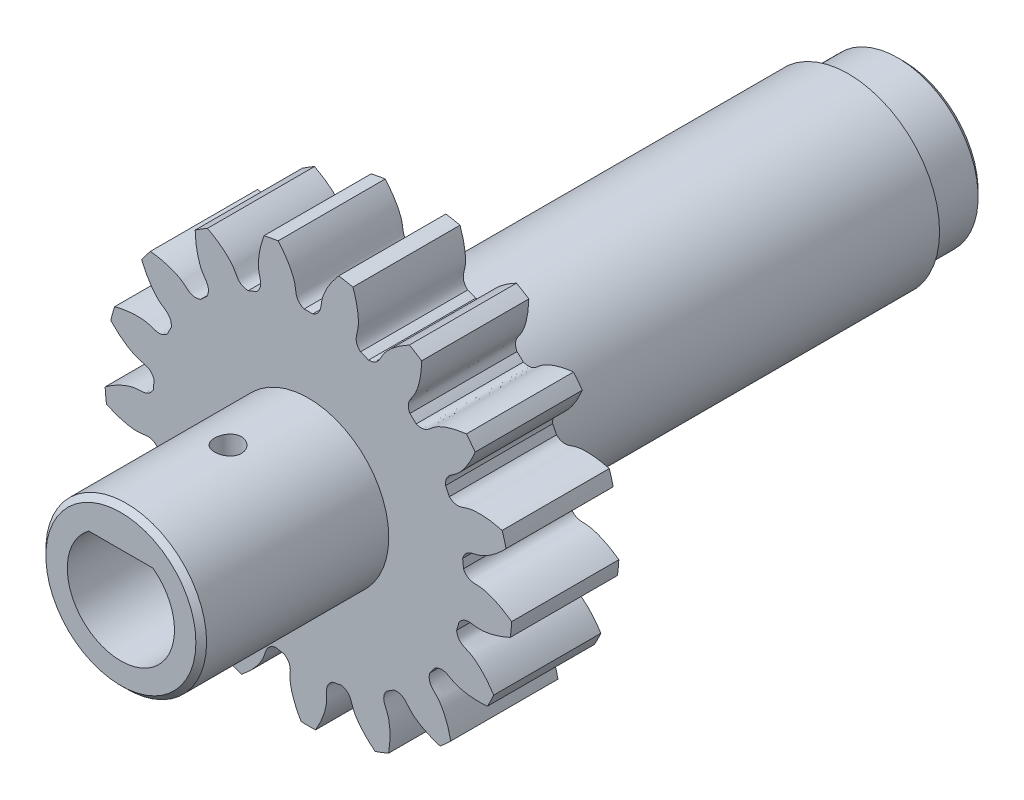
SolidWorks part; units mm, degrees
material "6061 合金"
ref_plane "前视基准面" through (0, 0, 0) normal (0, 0, 1) x (1, 0, 0)
ref_plane "上视基准面" through (0, 0, 0) normal (0, 1, 0) x (1, 0, 0)
ref_plane "右视基准面" through (0, 0, 0) normal (1, 0, 0) x (0, 0, -1)
sketch "草图1" plane through (0, 0, 0) normal (0, 0, 1) x (1, 0, 0)
  circle A0 centre (0, 0) radius 19
extrude "凸台-拉伸1" add sketch "草图1" along normal blind 5
ref_axis "基准轴1" through (0, 0, 5) along (0, 0, -1)
sketch "草图2" plane through (0, 0, 0) normal (0, 0, 1) x (1, 0, 0)
  line L0 (0, 0) -> (0, 19) construction
  circle A0 centre (0, 0) radius 19 construction
  arc A1 (0.4034, 14.4944) -> (-0.4034, 14.4944) centre (0, 0) ccw
  arc A2 (6.2313, 21.4814) -> (-6.2313, 21.4814) centre (0, 0) ccw
  spline S0 degree 3 poles (0.4034, 14.4944) (1.2558, 14.8496) (1.1324, 15.5096) (1.2766, 16.1296) (1.29, 16.1823) (1.306, 16.2408) (1.3251, 16.3052) (1.3474, 16.3752) (1.3731, 16.4508) (1.4025, 16.5319) (1.4359, 16.6184) (1.4733, 16.7101) (1.5152, 16.8068) (1.5616, 16.9086) (1.6128, 17.0151) (1.669, 17.1264) (1.7304, 17.2421) (1.7972, 17.3621) (1.8696, 17.4863) (1.9478, 17.6145) (2.032, 17.7465) (2.1224, 17.8821) (2.2191, 18.0211) (2.3223, 18.1634) (2.4322, 18.3086) (2.5489, 18.4566) (2.6727, 18.6072) (2.8035, 18.7601) (2.9417, 18.9152) (3.0873, 19.0722) (3.2404, 19.2308) (3.4012, 19.3908) (3.5698, 19.552) (3.7462, 19.7141) (3.9307, 19.8769) (4.1233, 20.0401) (4.324, 20.2035) (4.533, 20.3667) (4.7503, 20.5295) (4.9761, 20.6917) (5.2103, 20.853) (5.453, 21.0131) (5.7916, 21.2269) (6.0532, 21.3811) (6.2313, 21.4814) knots 0 0 0 0 0.193883 0.199024 0.204851 0.211363 0.21856 0.226443 0.235011 0.244265 0.254205 0.264829 0.27614 0.288136 0.300817 0.314184 0.328236 0.342973 0.358397 0.374505 0.391299 0.408779 0.426944 0.445795 0.465331 0.485552 0.506459 0.528051 0.550329 0.573293 0.596941 0.621276 0.646296 0.672001 0.698392 0.725468 0.753229 0.781677 0.810809 0.840627 0.871131 0.90232 0.934195 1 1 1 1
  spline S1 degree 3 poles (-0.4034, 14.4944) (-1.2558, 14.8496) (-1.1324, 15.5096) (-1.2766, 16.1296) (-1.29, 16.1823) (-1.306, 16.2408) (-1.3251, 16.3052) (-1.3474, 16.3752) (-1.3731, 16.4508) (-1.4025, 16.5319) (-1.4359, 16.6184) (-1.4733, 16.7101) (-1.5152, 16.8068) (-1.5616, 16.9086) (-1.6128, 17.0151) (-1.669, 17.1264) (-1.7304, 17.2421) (-1.7972, 17.3621) (-1.8696, 17.4863) (-1.9478, 17.6145) (-2.032, 17.7465) (-2.1224, 17.8821) (-2.2191, 18.0211) (-2.3223, 18.1634) (-2.4322, 18.3086) (-2.5489, 18.4566) (-2.6727, 18.6072) (-2.8035, 18.7601) (-2.9417, 18.9152) (-3.0873, 19.0722) (-3.2404, 19.2308) (-3.4012, 19.3908) (-3.5698, 19.552) (-3.7462, 19.7141) (-3.9307, 19.8769) (-4.1233, 20.0401) (-4.324, 20.2035) (-4.533, 20.3667) (-4.7503, 20.5295) (-4.9761, 20.6917) (-5.2103, 20.853) (-5.453, 21.0131) (-5.7916, 21.2269) (-6.0532, 21.3811) (-6.2313, 21.4814) knots 0 0 0 0 0.193883 0.199024 0.204851 0.211363 0.21856 0.226443 0.235011 0.244265 0.254205 0.264829 0.27614 0.288136 0.300817 0.314184 0.328236 0.342973 0.358397 0.374505 0.391299 0.408779 0.426944 0.445795 0.465331 0.485552 0.506459 0.528051 0.550329 0.573293 0.596941 0.621276 0.646296 0.672001 0.698392 0.725468 0.753229 0.781677 0.810809 0.840627 0.871131 0.90232 0.934195 1 1 1 1
extrude "切除-拉伸1" cut sketch "草图2" along normal through all
pattern_circular "阵列(圆周)1" count 17 over 360 about axis through (0, 0, 5) along (0, 0, -1) of "切除-拉伸1"
sketch "草图3" plane through (0, 0, 0) normal (0, 0, 1) x (1, 0, 0)
  circle A0 centre (0, 0) radius 17 construction
  dimension "Dn" = 34
sketch "草图4" plane through (0, 0, 5) normal (0, 0, 1) x (1, 0, 0)
  circle A0 centre (0, 0) radius 5
extrude "切除-拉伸2" cut sketch "草图4" against normal blind 10
sketch "草图5" plane through (0, 0, 0) normal (0, 0, -1) x (-1, 0, 0)
  circle A0 centre (0, 0) radius 7.5
  circle A1 centre (0, 0) radius 5
extrude "凸台-拉伸2" add sketch "草图5" along normal blind 20
sketch "草图6" plane through (0, 0, -20) normal (0, 0, -1) x (-1, 0, 0)
  line L0 (0, 5) -> (0, 4) construction
  line L1 (0, 4) -> (6.3443, 4)
  line L2 (6.3443, 4) -> (6.3443, 8.4587)
  line L3 (6.3443, 8.4587) -> (-6.8794, 8.4587)
  line L4 (-6.8794, 8.4587) -> (-6.8794, 4)
  line L5 (-6.8794, 4) -> (0, 4)
  circle A0 centre (0, 0) radius 5 construction
  circle A1 centre (0, 0) radius 7.5 construction
extrude "切除-拉伸3" cut sketch "草图6" against normal blind 18
sketch "草图7" plane through (0, 0, 5) normal (0, 0, 1) x (1, 0, 0)
  circle A0 centre (0, 0) radius 4
  circle A1 centre (0, 0) radius 6
sketch "草图8" plane through (0, 0, 5) normal (0, 0, 1) x (1, 0, 0)
  arc A34 (18.447, 4.5505) -> (18.0795, 5.8422) centre (0, 0) ccw
  arc A35 (13.1546, 6.0996) -> (12.795, 6.8218) centre (0, 0) ccw
  arc A36 (15.5575, 10.9071) -> (14.7482, 11.9787) centre (0, 0) ccw
  arc A37 (10.0629, 10.4397) -> (9.4667, 10.9832) centre (0, 0) ccw
  arc A38 (10.5668, 15.7906) -> (9.4251, 16.4975) centre (0, 0) ccw
  arc A39 (5.6121, 13.3699) -> (4.8598, 13.6613) centre (0, 0) ccw
  arc A40 (4.1491, 18.5414) -> (2.8291, 18.7882) centre (0, 0) ccw
  arc A41 (0.4034, 14.4944) -> (-0.4034, 14.4944) centre (0, 0) ccw
  arc A42 (-2.8291, 18.7882) -> (-4.1491, 18.5414) centre (0, 0) ccw
  arc A43 (-4.8598, 13.6613) -> (-5.6121, 13.3699) centre (0, 0) ccw
  arc A44 (-9.4251, 16.4975) -> (-10.5668, 15.7906) centre (0, 0) ccw
  arc A45 (-9.4667, 10.9832) -> (-10.0629, 10.4397) centre (0, 0) ccw
  arc A46 (-14.7482, 11.9787) -> (-15.5575, 10.9071) centre (0, 0) ccw
  arc A47 (-12.795, 6.8218) -> (-13.1546, 6.0996) centre (0, 0) ccw
  arc A48 (-18.0795, 5.8422) -> (-18.447, 4.5505) centre (0, 0) ccw
  arc A49 (-14.3953, 1.739) -> (-14.4698, 0.9357) centre (0, 0) ccw
  arc A50 (-18.9691, -1.0834) -> (-18.8452, -2.4206) centre (0, 0) ccw
  arc A51 (-14.0515, -3.5786) -> (-13.8307, -4.3546) centre (0, 0) ccw
  arc A52 (-17.2968, -7.8627) -> (-16.6982, -9.0648) centre (0, 0) ccw
  arc A53 (-11.8099, -8.4129) -> (-11.3237, -9.0567) centre (0, 0) ccw
  arc A54 (-13.2884, -13.5801) -> (-12.296, -14.4847) centre (0, 0) ccw
  arc A55 (-7.9733, -12.111) -> (-7.2873, -12.5357) centre (0, 0) ccw
  arc A56 (-7.4854, -17.4634) -> (-6.2332, -17.9485) centre (0, 0) ccw
  arc A57 (-3.0599, -14.1735) -> (-2.2668, -14.3217) centre (0, 0) ccw
  arc A58 (-0.6714, -18.9881) -> (0.6714, -18.9881) centre (0, 0) ccw
  arc A59 (2.2668, -14.3217) -> (3.0599, -14.1735) centre (0, 0) ccw
  arc A60 (6.2332, -17.9485) -> (7.4854, -17.4634) centre (0, 0) ccw
  arc A61 (7.2873, -12.5357) -> (7.9733, -12.111) centre (0, 0) ccw
  arc A62 (12.296, -14.4847) -> (13.2884, -13.5801) centre (0, 0) ccw
  arc A63 (11.3237, -9.0567) -> (11.8099, -8.4129) centre (0, 0) ccw
  arc A64 (16.6982, -9.0648) -> (17.2968, -7.8627) centre (0, 0) ccw
  arc A65 (13.8307, -4.3546) -> (14.0515, -3.5786) centre (0, 0) ccw
  arc A66 (18.8452, -2.4206) -> (18.9691, -1.0834) centre (0, 0) ccw
  arc A67 (14.4698, 0.9357) -> (14.3953, 1.739) centre (0, 0) ccw
  arc A68 (18.447, 4.5505) -> (18.0795, 5.8422) centre (0, 0) ccw
  arc A69 (13.1546, 6.0996) -> (12.795, 6.8218) centre (0, 0) ccw
  arc A70 (15.5575, 10.9071) -> (14.7482, 11.9787) centre (0, 0) ccw
  arc A71 (10.0629, 10.4397) -> (9.4667, 10.9832) centre (0, 0) ccw
  arc A72 (10.5668, 15.7906) -> (9.4251, 16.4975) centre (0, 0) ccw
  arc A73 (5.6121, 13.3699) -> (4.8598, 13.6613) centre (0, 0) ccw
  arc A74 (4.1491, 18.5414) -> (2.8291, 18.7882) centre (0, 0) ccw
  arc A75 (0.4034, 14.4944) -> (-0.4034, 14.4944) centre (0, 0) ccw
  arc A76 (-2.8291, 18.7882) -> (-4.1491, 18.5414) centre (0, 0) ccw
  arc A77 (-4.8598, 13.6613) -> (-5.6121, 13.3699) centre (0, 0) ccw
  arc A78 (-9.4251, 16.4975) -> (-10.5668, 15.7906) centre (0, 0) ccw
  arc A79 (-9.4667, 10.9832) -> (-10.0629, 10.4397) centre (0, 0) ccw
  arc A80 (-14.7482, 11.9787) -> (-15.5575, 10.9071) centre (0, 0) ccw
  arc A81 (-12.795, 6.8218) -> (-13.1546, 6.0996) centre (0, 0) ccw
  arc A82 (-18.0795, 5.8422) -> (-18.447, 4.5505) centre (0, 0) ccw
  arc A83 (-14.3953, 1.739) -> (-14.4698, 0.9357) centre (0, 0) ccw
  arc A84 (-18.9691, -1.0834) -> (-18.8452, -2.4206) centre (0, 0) ccw
  arc A85 (-14.0515, -3.5786) -> (-13.8307, -4.3546) centre (0, 0) ccw
  arc A86 (-17.2968, -7.8627) -> (-16.6982, -9.0648) centre (0, 0) ccw
  arc A87 (-11.8099, -8.4129) -> (-11.3237, -9.0567) centre (0, 0) ccw
  arc A88 (-13.2884, -13.5801) -> (-12.296, -14.4847) centre (0, 0) ccw
  arc A89 (-7.9733, -12.111) -> (-7.2873, -12.5357) centre (0, 0) ccw
  arc A90 (-7.4854, -17.4634) -> (-6.2332, -17.9485) centre (0, 0) ccw
  arc A91 (-3.0599, -14.1735) -> (-2.2668, -14.3217) centre (0, 0) ccw
  arc A92 (-0.6714, -18.9881) -> (0.6714, -18.9881) centre (0, 0) ccw
  arc A93 (2.2668, -14.3217) -> (3.0599, -14.1735) centre (0, 0) ccw
  arc A94 (6.2332, -17.9485) -> (7.4854, -17.4634) centre (0, 0) ccw
  arc A95 (7.2873, -12.5357) -> (7.9733, -12.111) centre (0, 0) ccw
  arc A96 (12.296, -14.4847) -> (13.2884, -13.5801) centre (0, 0) ccw
  arc A97 (11.3237, -9.0567) -> (11.8099, -8.4129) centre (0, 0) ccw
  arc A98 (16.6982, -9.0648) -> (17.2968, -7.8627) centre (0, 0) ccw
  arc A99 (13.8307, -4.3546) -> (14.0515, -3.5786) centre (0, 0) ccw
  arc A100 (18.8452, -2.4206) -> (18.9691, -1.0834) centre (0, 0) ccw
  arc A101 (14.4698, 0.9357) -> (14.3953, 1.739) centre (0, 0) ccw
  spline S34 degree 3 poles (-1099.3324, 2789.5842) (39.7143, -194.6612) (52.7497, -2.854) (17.8478, 5.9015) (17.6578, 5.9451) (17.4733, 5.9836) (17.2943, 6.0173) (17.121, 6.0463) (16.9535, 6.0709) (16.7918, 6.0913) (16.6361, 6.1079) (16.4865, 6.1207) (16.343, 6.1302) (16.2058, 6.1365) (16.0748, 6.1399) (15.9502, 6.1406) (15.832, 6.1389) (15.7202, 6.1351) (15.615, 6.1294) (15.5162, 6.1221) (15.4239, 6.1134) (15.3382, 6.1036) (15.2591, 6.0929) (15.1864, 6.0817) (15.1204, 6.07) (15.0608, 6.0584) (15.0077, 6.0468) (7.0464, 4.1537) (10.587, -43.3212) (-564.648, 2949.6814) knots -11.532914 -11.532914 -11.532914 -11.532914 0.004296 0.025888 0.046795 0.067016 0.086552 0.105403 0.123568 0.141048 0.157842 0.17395 0.189373 0.204111 0.218163 0.23153 0.244211 0.256207 0.267517 0.278142 0.288082 0.297336 0.305904 0.313787 0.320984 0.327496 0.333323 0.338464 2.960892 2.960892 2.960892 2.960892 only from (18.0795, 5.8422) to (13.1546, 6.0996)
  spline S35 degree 3 poles (2013.5379, -2228.0878) (-28.19, 34.5546) (7.5612, 3.1201) (13.8696, 8.3324) (13.9108, 8.3678) (13.9561, 8.4083) (14.0051, 8.454) (14.0579, 8.5052) (14.1141, 8.5619) (14.1736, 8.6244) (14.2361, 8.6928) (14.3015, 8.7672) (14.3695, 8.8478) (14.4399, 8.9347) (14.5125, 9.028) (14.587, 9.1279) (14.6632, 9.2344) (14.7409, 9.3477) (14.8198, 9.4679) (14.8997, 9.5951) (14.9803, 9.7293) (15.0614, 9.8706) (15.1427, 10.0192) (15.224, 10.175) (15.305, 10.3381) (15.3855, 10.5085) (15.4652, 10.6864) (29.5113, 43.8151) (-131.41, 149.0024) (1563.6438, -2558.3918) knots -1.960857 -1.960857 -1.960857 -1.960857 0.661536 0.666677 0.672504 0.679016 0.686213 0.694096 0.702664 0.711918 0.721858 0.732483 0.743793 0.755789 0.76847 0.781837 0.795889 0.810627 0.82605 0.842158 0.858952 0.876432 0.894597 0.913448 0.932984 0.953205 0.974112 0.995704 12.532922 12.532922 12.532922 12.532922 only from (12.795, 6.8218) to (15.5575, 10.9071)
  spline S36 degree 3 poles (-2032.811, 2204.0851) (107.3522, -167.1697) (50.2187, 16.3941) (14.5107, 11.9503) (14.3178, 11.9224) (14.1318, 11.8916) (13.9528, 11.8584) (13.7807, 11.8228) (13.6156, 11.7852) (13.4574, 11.7459) (13.3063, 11.7051) (13.1621, 11.663) (13.0249, 11.62) (12.8947, 11.5763) (12.7713, 11.5322) (12.6549, 11.4878) (12.5453, 11.4436) (12.4424, 11.3996) (12.3463, 11.3563) (12.2568, 11.3138) (12.174, 11.2723) (12.0976, 11.2322) (12.0276, 11.1937) (11.964, 11.157) (11.9066, 11.1223) (11.8552, 11.0898) (11.8099, 11.0599) (5.0701, 6.4187) (25.5215, -36.5713) (-1592.0664, 2546.5216) knots -11.532914 -11.532914 -11.532914 -11.532914 0.004296 0.025888 0.046795 0.067016 0.086552 0.105403 0.123568 0.141048 0.157842 0.17395 0.189373 0.204111 0.218163 0.23153 0.244211 0.256207 0.267517 0.278142 0.288082 0.297336 0.305904 0.313787 0.320984 0.327496 0.333323 0.338464 2.960892 2.960892 2.960892 2.960892 only from (14.7482, 11.9787) to (10.0629, 10.4397)
  spline S37 degree 3 poles (2682.4463, -1350.2562) (-38.7689, 22.0378) (5.9235, 5.6408) (9.923, 12.78) (9.9487, 12.8279) (9.9762, 12.882) (10.0055, 12.9424) (10.0362, 13.0091) (10.0681, 13.0824) (10.101, 13.1621) (10.1346, 13.2485) (10.1687, 13.3415) (10.203, 13.4412) (10.2372, 13.5476) (10.2712, 13.6609) (10.3046, 13.7809) (10.3372, 13.9078) (10.3687, 14.0415) (10.3988, 14.1821) (10.4274, 14.3295) (10.4541, 14.4838) (10.4786, 14.6449) (10.5008, 14.8128) (10.5204, 14.9874) (10.537, 15.1688) (10.5504, 15.3568) (10.5605, 15.5515) (11.6906, 51.5171) (-176.3621, 91.4698) (2382.2521, -1820.776) knots -1.960857 -1.960857 -1.960857 -1.960857 0.661536 0.666677 0.672504 0.679016 0.686213 0.694096 0.702664 0.711918 0.721858 0.732483 0.743793 0.755789 0.76847 0.781837 0.795889 0.810627 0.82605 0.842158 0.858952 0.876432 0.894597 0.913448 0.932984 0.953205 0.974112 0.995704 12.532922 12.532922 12.532922 12.532922 only from (9.4667, 10.9832) to (10.5668, 15.7906)
  spline S38 degree 3 poles (-2691.7472, 1320.9121) (160.4916, -117.1011) (40.9053, 33.4281) (9.2139, 16.3852) (9.0441, 16.2895) (8.8818, 16.1936) (8.7269, 16.0979) (8.5792, 16.0026) (8.4388, 15.9079) (8.3056, 15.8141) (8.1794, 15.7214) (8.0602, 15.6301) (7.9478, 15.5405) (7.8421, 15.4527) (7.743, 15.367) (7.6504, 15.2836) (7.5642, 15.2027) (7.4842, 15.1246) (7.4102, 15.0494) (7.3422, 14.9775) (7.2798, 14.9089) (7.2231, 14.8439) (7.1718, 14.7827) (7.1257, 14.7254) (7.0847, 14.6723) (7.0486, 14.6236) (7.0171, 14.5793) (2.409, 7.8167) (37.0092, -24.8823) (-2404.4674, 1799.44) knots -11.532914 -11.532914 -11.532914 -11.532914 0.004296 0.025888 0.046795 0.067016 0.086552 0.105403 0.123568 0.141048 0.157842 0.17395 0.189373 0.204111 0.218163 0.23153 0.244211 0.256207 0.267517 0.278142 0.288082 0.297336 0.305904 0.313787 0.320984 0.327496 0.333323 0.338464 2.960892 2.960892 2.960892 2.960892 only from (9.4251, 16.4975) to (5.6121, 13.3699)
  spline S39 degree 3 poles (2989.0755, -290.0651) (-44.1119, 6.5447) (3.4858, 7.3997) (4.6363, 15.5016) (4.6429, 15.5555) (4.649, 15.6159) (4.6545, 15.6828) (4.659, 15.7561) (4.6623, 15.836) (4.6642, 15.9222) (4.6643, 16.0149) (4.6625, 16.1139) (4.6585, 16.2193) (4.652, 16.3309) (4.6427, 16.4488) (4.6305, 16.5728) (4.615, 16.7028) (4.5961, 16.8389) (4.5734, 16.9809) (4.5468, 17.1287) (4.516, 17.2822) (4.4807, 17.4413) (4.4407, 17.6058) (4.3959, 17.7757) (4.3459, 17.9509) (4.2905, 18.1311) (4.2295, 18.3162) (-7.709, 52.2614) (-197.4955, 21.5837) (2879.1242, -837.2543) knots -1.960857 -1.960857 -1.960857 -1.960857 0.661536 0.666677 0.672504 0.679016 0.686213 0.694096 0.702664 0.711918 0.721858 0.732483 0.743793 0.755789 0.76847 0.781837 0.795889 0.810627 0.82605 0.842158 0.858952 0.876432 0.894597 0.913448 0.932984 0.953205 0.974112 0.995704 12.532922 12.532922 12.532922 12.532922 only from (4.8598, 13.6613) to (4.1491, 18.5414)
  spline S40 degree 3 poles (-2987.148, 259.3426) (191.9557, -51.2172) (26.0674, 45.9475) (2.6727, 18.6072) (2.5489, 18.4566) (2.4322, 18.3086) (2.3223, 18.1634) (2.2191, 18.0211) (2.1224, 17.8821) (2.032, 17.7465) (1.9478, 17.6145) (1.8696, 17.4863) (1.7972, 17.3621) (1.7304, 17.2421) (1.669, 17.1264) (1.6128, 17.0151) (1.5616, 16.9086) (1.5152, 16.8068) (1.4733, 16.7101) (1.4359, 16.6184) (1.4025, 16.5319) (1.3731, 16.4508) (1.3474, 16.3752) (1.3251, 16.3052) (1.306, 16.2408) (1.29, 16.1823) (1.2766, 16.1296) (-0.5774, 8.1591) (43.4986, -9.8328) (-2892.1317, 809.334) knots -11.532914 -11.532914 -11.532914 -11.532914 0.004296 0.025888 0.046795 0.067016 0.086552 0.105403 0.123568 0.141048 0.157842 0.17395 0.189373 0.204111 0.218163 0.23153 0.244211 0.256207 0.267517 0.278142 0.288082 0.297336 0.305904 0.313787 0.320984 0.327496 0.333323 0.338464 2.960892 2.960892 2.960892 2.960892 only from (2.8291, 18.7882) to (0.4034, 14.4944)
  spline S41 degree 3 poles (2892.0135, 809.301) (-43.4974, -9.8323) (0.5773, 8.1593) (-1.2766, 16.1296) (-1.29, 16.1823) (-1.306, 16.2408) (-1.3251, 16.3052) (-1.3474, 16.3752) (-1.3731, 16.4508) (-1.4025, 16.5319) (-1.4359, 16.6184) (-1.4733, 16.7101) (-1.5152, 16.8068) (-1.5616, 16.9086) (-1.6128, 17.0151) (-1.669, 17.1264) (-1.7304, 17.2421) (-1.7972, 17.3621) (-1.8696, 17.4863) (-1.9478, 17.6145) (-2.032, 17.7465) (-2.1224, 17.8821) (-2.2191, 18.0211) (-2.3223, 18.1634) (-2.4322, 18.3086) (-2.5489, 18.4566) (-2.6727, 18.6072) (-26.0674, 45.9475) (-191.956, -51.2174) (2987.1545, 259.3432) knots -1.960857 -1.960857 -1.960857 -1.960857 0.661536 0.666677 0.672504 0.679016 0.686213 0.694096 0.702664 0.711918 0.721858 0.732483 0.743793 0.755789 0.76847 0.781837 0.795889 0.810627 0.82605 0.842158 0.858952 0.876432 0.894597 0.913448 0.932984 0.953205 0.974112 0.995704 12.532922 12.532922 12.532922 12.532922 only from (-0.4034, 14.4944) to (-2.8291, 18.7882)
  spline S42 degree 3 poles (-2879.1179, -837.2525) (197.4952, 21.5838) (7.709, 52.2614) (-4.2295, 18.3162) (-4.2905, 18.1311) (-4.3459, 17.9509) (-4.3959, 17.7757) (-4.4407, 17.6058) (-4.4807, 17.4413) (-4.516, 17.2822) (-4.5468, 17.1287) (-4.5734, 16.9809) (-4.5961, 16.8389) (-4.615, 16.7028) (-4.6305, 16.5728) (-4.6427, 16.4488) (-4.652, 16.3309) (-4.6585, 16.2193) (-4.6625, 16.1139) (-4.6643, 16.0149) (-4.6642, 15.9222) (-4.6623, 15.836) (-4.659, 15.7561) (-4.6545, 15.6828) (-4.649, 15.6159) (-4.6429, 15.5555) (-4.6363, 15.5016) (-3.4858, 7.3996) (44.1132, 6.5447) (-2989.1977, -290.077) knots -11.532914 -11.532914 -11.532914 -11.532914 0.004296 0.025888 0.046795 0.067016 0.086552 0.105403 0.123568 0.141048 0.157842 0.17395 0.189373 0.204111 0.218163 0.23153 0.244211 0.256207 0.267517 0.278142 0.288082 0.297336 0.305904 0.313787 0.320984 0.327496 0.333323 0.338464 2.960892 2.960892 2.960892 2.960892 only from (-4.1491, 18.5414) to (-4.8598, 13.6613)
  spline S43 degree 3 poles (2404.369, 1799.3665) (-37.0083, -24.8814) (-2.4091, 7.8168) (-7.0171, 14.5793) (-7.0486, 14.6236) (-7.0847, 14.6723) (-7.1257, 14.7254) (-7.1718, 14.7827) (-7.2231, 14.8439) (-7.2798, 14.9089) (-7.3422, 14.9775) (-7.4102, 15.0494) (-7.4842, 15.1246) (-7.5642, 15.2027) (-7.6504, 15.2836) (-7.743, 15.367) (-7.8421, 15.4527) (-7.9478, 15.5405) (-8.0602, 15.6301) (-8.1794, 15.7214) (-8.3056, 15.8141) (-8.4388, 15.9079) (-8.5792, 16.0026) (-8.7269, 16.0979) (-8.8818, 16.1936) (-9.0441, 16.2895) (-9.2139, 16.3852) (-40.9053, 33.4282) (-160.4918, -117.1013) (2691.753, 1320.915) knots -1.960857 -1.960857 -1.960857 -1.960857 0.661536 0.666677 0.672504 0.679016 0.686213 0.694096 0.702664 0.711918 0.721858 0.732483 0.743793 0.755789 0.76847 0.781837 0.795889 0.810627 0.82605 0.842158 0.858952 0.876432 0.894597 0.913448 0.932984 0.953205 0.974112 0.995704 12.532922 12.532922 12.532922 12.532922 only from (-5.6121, 13.3699) to (-9.4251, 16.4975)
  spline S44 degree 3 poles (-2382.247, -1820.7721) (176.3618, 91.4698) (-11.6906, 51.5171) (-10.5605, 15.5515) (-10.5504, 15.3568) (-10.537, 15.1688) (-10.5204, 14.9874) (-10.5008, 14.8128) (-10.4786, 14.6449) (-10.4541, 14.4838) (-10.4274, 14.3295) (-10.3988, 14.1821) (-10.3687, 14.0415) (-10.3372, 13.9078) (-10.3046, 13.7809) (-10.2712, 13.6609) (-10.2372, 13.5476) (-10.203, 13.4412) (-10.1687, 13.3415) (-10.1346, 13.2485) (-10.101, 13.1621) (-10.0681, 13.0824) (-10.0362, 13.0091) (-10.0055, 12.9424) (-9.9762, 12.882) (-9.9487, 12.8279) (-9.923, 12.78) (-5.9235, 5.6407) (38.7701, 22.0383) (-2682.5559, -1350.3115) knots -11.532914 -11.532914 -11.532914 -11.532914 0.004296 0.025888 0.046795 0.067016 0.086552 0.105403 0.123568 0.141048 0.157842 0.17395 0.189373 0.204111 0.218163 0.23153 0.244211 0.256207 0.267517 0.278142 0.288082 0.297336 0.305904 0.313787 0.320984 0.327496 0.333323 0.338464 2.960892 2.960892 2.960892 2.960892 only from (-10.5668, 15.7906) to (-9.4667, 10.9832)
  spline S45 degree 3 poles (1592.0012, 2546.4175) (-25.521, -36.5702) (-5.0702, 6.4187) (-11.8099, 11.0599) (-11.8552, 11.0898) (-11.9066, 11.1223) (-11.964, 11.157) (-12.0276, 11.1937) (-12.0976, 11.2322) (-12.174, 11.2723) (-12.2568, 11.3138) (-12.3463, 11.3563) (-12.4424, 11.3996) (-12.5453, 11.4436) (-12.6549, 11.4878) (-12.7713, 11.5322) (-12.8947, 11.5763) (-13.0249, 11.62) (-13.1621, 11.663) (-13.3063, 11.7051) (-13.4574, 11.7459) (-13.6156, 11.7852) (-13.7807, 11.8228) (-13.9528, 11.8584) (-14.1318, 11.8916) (-14.3178, 11.9224) (-14.5107, 11.9503) (-50.2187, 16.3941) (-107.3523, -167.17) (2032.8154, 2204.0899) knots -1.960857 -1.960857 -1.960857 -1.960857 0.661536 0.666677 0.672504 0.679016 0.686213 0.694096 0.702664 0.711918 0.721858 0.732483 0.743793 0.755789 0.76847 0.781837 0.795889 0.810627 0.82605 0.842158 0.858952 0.876432 0.894597 0.913448 0.932984 0.953205 0.974112 0.995704 12.532922 12.532922 12.532922 12.532922 only from (-10.0629, 10.4397) to (-14.7482, 11.9787)
  spline S46 degree 3 poles (-1563.6404, -2558.3863) (131.4098, 149.0023) (-29.5113, 43.8151) (-15.4652, 10.6864) (-15.3855, 10.5085) (-15.305, 10.3381) (-15.224, 10.175) (-15.1427, 10.0192) (-15.0614, 9.8706) (-14.9803, 9.7293) (-14.8997, 9.5951) (-14.8198, 9.4679) (-14.7409, 9.3477) (-14.6632, 9.2344) (-14.587, 9.1279) (-14.5125, 9.028) (-14.4399, 8.9347) (-14.3695, 8.8478) (-14.3015, 8.7672) (-14.2361, 8.6928) (-14.1736, 8.6244) (-14.1141, 8.5619) (-14.0579, 8.5052) (-14.0051, 8.454) (-13.9561, 8.4083) (-13.9108, 8.3678) (-13.8696, 8.3324) (-7.5611, 3.12) (28.1909, 34.5555) (-2013.6201, -2228.179) knots -11.532914 -11.532914 -11.532914 -11.532914 0.004296 0.025888 0.046795 0.067016 0.086552 0.105403 0.123568 0.141048 0.157842 0.17395 0.189373 0.204111 0.218163 0.23153 0.244211 0.256207 0.267517 0.278142 0.288082 0.297336 0.305904 0.313787 0.320984 0.327496 0.333323 0.338464 2.960892 2.960892 2.960892 2.960892 only from (-15.5575, 10.9071) to (-12.795, 6.8218)
  spline S47 degree 3 poles (564.6248, 2949.5608) (-10.5869, -43.3199) (-7.0465, 4.1537) (-15.0077, 6.0468) (-15.0608, 6.0584) (-15.1204, 6.07) (-15.1864, 6.0817) (-15.2591, 6.0929) (-15.3382, 6.1036) (-15.4239, 6.1134) (-15.5162, 6.1221) (-15.615, 6.1294) (-15.7202, 6.1351) (-15.832, 6.1389) (-15.9502, 6.1406) (-16.0748, 6.1399) (-16.2058, 6.1365) (-16.343, 6.1302) (-16.4865, 6.1207) (-16.6361, 6.1079) (-16.7918, 6.0913) (-16.9535, 6.0709) (-17.121, 6.0463) (-17.2943, 6.0173) (-17.4733, 5.9836) (-17.6578, 5.9451) (-17.8478, 5.9015) (-52.7498, -2.854) (-39.7142, -194.6615) (1099.3348, 2789.5902) knots -1.960857 -1.960857 -1.960857 -1.960857 0.661536 0.666677 0.672504 0.679016 0.686213 0.694096 0.702664 0.711918 0.721858 0.732483 0.743793 0.755789 0.76847 0.781837 0.795889 0.810627 0.82605 0.842158 0.858952 0.876432 0.894597 0.913448 0.932984 0.953205 0.974112 0.995704 12.532922 12.532922 12.532922 12.532922 only from (-13.1546, 6.0996) to (-18.0795, 5.8422)
  spline S48 degree 3 poles (-533.8555, -2950.4762) (68.7102, 186.4112) (-43.3463, 30.1957) (-18.2812, 4.3781) (-18.1427, 4.241) (-18.0061, 4.1111) (-17.8716, 3.9883) (-17.7395, 3.8724) (-17.61, 3.7633) (-17.4833, 3.6608) (-17.3597, 3.5648) (-17.2392, 3.4751) (-17.1222, 3.3915) (-17.0089, 3.3139) (-16.8993, 3.2421) (-16.7938, 3.1758) (-16.6924, 3.115) (-16.5953, 3.0594) (-16.5028, 3.0089) (-16.415, 2.9631) (-16.332, 2.9219) (-16.2539, 2.8852) (-16.181, 2.8525) (-16.1134, 2.8239) (-16.0511, 2.799) (-15.9942, 2.7776) (-15.9431, 2.7594) (-8.1776, 0.1779) (13.8044, 42.4057) (-1072.7338, -2805.1185) knots -11.532914 -11.532914 -11.532914 -11.532914 0.004296 0.025888 0.046795 0.067016 0.086552 0.105403 0.123568 0.141048 0.157842 0.17395 0.189373 0.204111 0.218163 0.23153 0.244211 0.256207 0.267517 0.278142 0.288082 0.297336 0.305904 0.313787 0.320984 0.327496 0.333323 0.338464 2.960892 2.960892 2.960892 2.960892 only from (-18.447, 4.5505) to (-14.3953, 1.739)
  spline S49 degree 3 poles (-539.0073, 2954.3495) (5.7769, -44.219) (-8.0712, 1.3277) (-16.1786, 0.2171) (-16.2323, 0.2087) (-16.2921, 0.198) (-16.3579, 0.185) (-16.4297, 0.1693) (-16.5073, 0.1506) (-16.5908, 0.1288) (-16.68, 0.1036) (-16.7747, 0.0748) (-16.875, 0.042) (-16.9805, 0.0052) (-17.0914, -0.0359) (-17.2073, -0.0816) (-17.3282, -0.1321) (-17.4539, -0.1875) (-17.5843, -0.2482) (-17.7191, -0.3142) (-17.8583, -0.3859) (-18.0017, -0.4634) (-18.149, -0.5468) (-18.3002, -0.6365) (-18.4549, -0.7325) (-18.6131, -0.8351) (-18.7744, -0.9444) (-48.1567, -21.7167) (33.2874, -195.8629) (17.3829, 2998.341) knots -1.960857 -1.960857 -1.960857 -1.960857 0.661536 0.666677 0.672504 0.679016 0.686213 0.694096 0.702664 0.711918 0.721858 0.732483 0.743793 0.755789 0.76847 0.781837 0.795889 0.810627 0.82605 0.842158 0.858952 0.876432 0.894597 0.913448 0.932984 0.953205 0.974112 0.995704 12.532922 12.532922 12.532922 12.532922 only from (-14.4698, 0.9357) to (-18.9691, -1.0834)
  spline S50 degree 3 poles (568.0296, -2944.088) (-3.2691, 198.6442) (-51.3272, 12.4981) (-18.6283, -2.5215) (-18.4496, -2.5992) (-18.2753, -2.671) (-18.1055, -2.737) (-17.9405, -2.7973) (-17.7803, -2.8523) (-17.6252, -2.9021) (-17.4752, -2.947) (-17.3305, -2.9871) (-17.1912, -3.0228) (-17.0574, -3.0542) (-16.9293, -3.0816) (-16.807, -3.1052) (-16.6905, -3.1253) (-16.5799, -3.1421) (-16.4754, -3.1558) (-16.3769, -3.1668) (-16.2846, -3.1752) (-16.1986, -3.1813) (-16.1188, -3.1853) (-16.0454, -3.1876) (-15.9783, -3.1883) (-15.9176, -3.1878) (-15.8633, -3.1862) (-7.6897, -2.7882) (-2.4465, 44.5289) (13.0312, -3003.2112) knots -11.532914 -11.532914 -11.532914 -11.532914 0.004296 0.025888 0.046795 0.067016 0.086552 0.105403 0.123568 0.141048 0.157842 0.17395 0.189373 0.204111 0.218163 0.23153 0.244211 0.256207 0.267517 0.278142 0.288082 0.297336 0.305904 0.313787 0.320984 0.327496 0.333323 0.338464 2.960892 2.960892 2.960892 2.960892 only from (-18.8452, -2.4206) to (-14.0515, -3.5786)
  spline S51 degree 3 poles (-1569.8435, 2560.137) (21.3606, -39.1462) (-8.0058, -1.6776) (-15.1645, -5.642) (-15.2115, -5.6692) (-15.2634, -5.7007) (-15.3201, -5.7366) (-15.3814, -5.7772) (-15.447, -5.8227) (-15.517, -5.8732) (-15.591, -5.9289) (-15.669, -5.99) (-15.7506, -6.0567) (-15.8358, -6.1292) (-15.9243, -6.2076) (-16.0158, -6.2921) (-16.1103, -6.3828) (-16.2075, -6.48) (-16.3072, -6.5836) (-16.4091, -6.6939) (-16.513, -6.811) (-16.6187, -6.935) (-16.7259, -7.0661) (-16.8345, -7.2043) (-16.9441, -7.3497) (-17.0545, -7.5025) (-17.1655, -7.6627) (-37.0598, -37.6464) (101.7934, -170.6119) (-1066.9166, 2802.1492) knots -1.960857 -1.960857 -1.960857 -1.960857 0.661536 0.666677 0.672504 0.679016 0.686213 0.694096 0.702664 0.711918 0.721858 0.732483 0.743793 0.755789 0.76847 0.781837 0.795889 0.810627 0.82605 0.842158 0.858952 0.876432 0.894597 0.913448 0.932984 0.953205 0.974112 0.995704 12.532922 12.532922 12.532922 12.532922 only from (-13.8307, -4.3546) to (-17.2968, -7.8627)
  spline S52 degree 3 poles (1593.199, -2540.0844) (-74.807, 184.0493) (-52.376, -6.8873) (-16.4595, -9.0805) (-16.2648, -9.0885) (-16.0763, -9.0924) (-15.8942, -9.0926) (-15.7185, -9.0893) (-15.5493, -9.0827) (-15.3866, -9.0731) (-15.2305, -9.0607) (-15.0811, -9.0459) (-14.9383, -9.0288) (-14.8023, -9.0098) (-14.6729, -8.9891) (-14.5503, -8.9669) (-14.4344, -8.9435) (-14.3252, -8.9193) (-14.2228, -8.8943) (-14.127, -8.869) (-14.038, -8.8435) (-13.9555, -8.8181) (-13.8797, -8.793) (-13.8104, -8.7686) (-13.7475, -8.7451) (-13.6911, -8.7226) (-13.6411, -8.7015) (-6.1632, -5.3777) (-18.367, 40.6382) (1097.0363, -2795.7037) knots -11.532914 -11.532914 -11.532914 -11.532914 0.004296 0.025888 0.046795 0.067016 0.086552 0.105403 0.123568 0.141048 0.157842 0.17395 0.189373 0.204111 0.218163 0.23153 0.244211 0.256207 0.267517 0.278142 0.288082 0.297336 0.305904 0.313787 0.320984 0.327496 0.333323 0.338464 2.960892 2.960892 2.960892 2.960892 only from (-16.6982, -9.0648) to (-11.8099, -8.4129)
  spline S53 degree 3 poles (-2388.6636, 1820.1638) (34.0594, -28.7864) (-6.8592, -4.4563) (-12.1024, -10.739) (-12.1364, -10.7814) (-12.1734, -10.8295) (-12.2133, -10.8835) (-12.2557, -10.9435) (-12.3005, -11.0096) (-12.3475, -11.082) (-12.3964, -11.1607) (-12.447, -11.2458) (-12.4991, -11.3375) (-12.5523, -11.4359) (-12.6065, -11.5409) (-12.6614, -11.6528) (-12.7167, -11.7715) (-12.7722, -11.8972) (-12.8277, -12.0299) (-12.8829, -12.1695) (-12.9375, -12.3163) (-12.9912, -12.4701) (-13.0439, -12.631) (-13.0952, -12.7991) (-13.1448, -12.9743) (-13.1926, -13.1567) (-13.2382, -13.3462) (-20.9578, -48.4918) (156.5517, -122.3188) (-2007.1231, 2227.5115) knots -1.960857 -1.960857 -1.960857 -1.960857 0.661536 0.666677 0.672504 0.679016 0.686213 0.694096 0.702664 0.711918 0.721858 0.732483 0.743793 0.755789 0.76847 0.781837 0.795889 0.810627 0.82605 0.842158 0.858952 0.876432 0.894597 0.913448 0.932984 0.953205 0.974112 0.995704 12.532922 12.532922 12.532922 12.532922 only from (-11.3237, -9.0567) to (-13.2884, -13.5801)
  spline S54 degree 3 poles (2403.1981, -1793.0283) (-136.2417, 144.5974) (-46.3512, -25.3426) (-12.0678, -14.4132) (-11.8833, -14.3503) (-11.7061, -14.2859) (-11.5362, -14.2203) (-11.3736, -14.1537) (-11.2182, -14.0864) (-11.07, -14.0187) (-10.9289, -13.9508) (-10.7949, -13.883) (-10.668, -13.8155) (-10.548, -13.7486) (-10.4349, -13.6825) (-10.3285, -13.6176) (-10.2289, -13.5539) (-10.1359, -13.4918) (-10.0494, -13.4316) (-9.9692, -13.3733) (-9.8954, -13.3174) (-9.8277, -13.2639) (-9.766, -13.2132) (-9.7102, -13.1654) (-9.6601, -13.1207) (-9.6156, -13.0794) (-9.5766, -13.0417) (-3.8043, -7.241) (-31.8069, 31.259) (2032.8805, -2210.6208) knots -11.532914 -11.532914 -11.532914 -11.532914 0.004296 0.025888 0.046795 0.067016 0.086552 0.105403 0.123568 0.141048 0.157842 0.17395 0.189373 0.204111 0.218163 0.23153 0.244211 0.256207 0.267517 0.278142 0.288082 0.297336 0.305904 0.313787 0.320984 0.327496 0.333323 0.338464 2.960892 2.960892 2.960892 2.960892 only from (-12.296, -14.4847) to (-7.9733, -12.111)
  spline S55 degree 3 poles (-2884.8815, 834.3673) (42.1583, -14.5388) (-4.7862, -6.6332) (-7.4058, -14.3858) (-7.4221, -14.4375) (-7.4393, -14.4958) (-7.4569, -14.5605) (-7.4749, -14.6318) (-7.4928, -14.7096) (-7.5105, -14.7941) (-7.5276, -14.8851) (-7.5441, -14.9828) (-7.5594, -15.0871) (-7.5736, -15.198) (-7.5861, -15.3156) (-7.5969, -15.4397) (-7.6056, -15.5704) (-7.612, -15.7077) (-7.6158, -15.8514) (-7.6168, -16.0016) (-7.6147, -16.1581) (-7.6092, -16.321) (-7.6002, -16.4901) (-7.5873, -16.6653) (-7.5703, -16.8467) (-7.549, -17.034) (-7.5231, -17.2271) (-2.0253, -52.7881) (190.1667, -57.5059) (-2676.2566, 1352.0361) knots -1.960857 -1.960857 -1.960857 -1.960857 0.661536 0.666677 0.672504 0.679016 0.686213 0.694096 0.702664 0.711918 0.721858 0.732483 0.743793 0.755789 0.76847 0.781837 0.795889 0.810627 0.82605 0.842158 0.858952 0.876432 0.894597 0.913448 0.932984 0.953205 0.974112 0.995704 12.532922 12.532922 12.532922 12.532922 only from (-7.2873, -12.5357) to (-7.4854, -17.4634)
  spline S56 degree 3 poles (2888.632, -803.8137) (-179.2762, 85.6169) (-34.0664, -40.3753) (-6.0462, -17.7993) (-5.8969, -17.674) (-5.755, -17.5499) (-5.6203, -17.4274) (-5.4927, -17.3065) (-5.3721, -17.1877) (-5.2583, -17.071) (-5.1513, -16.9567) (-5.0509, -16.8451) (-4.9569, -16.7363) (-4.8691, -16.6305) (-4.7875, -16.5281) (-4.7118, -16.4291) (-4.6419, -16.3338) (-4.5776, -16.2423) (-4.5187, -16.1548) (-4.465, -16.0716) (-4.4164, -15.9927) (-4.3726, -15.9184) (-4.3334, -15.8488) (-4.2986, -15.7841) (-4.268, -15.7243) (-4.2415, -15.6697) (-4.2187, -15.6204) (-0.9317, -8.1263) (-40.9511, 17.6582) (2694.173, -1326.9814) knots -11.532914 -11.532914 -11.532914 -11.532914 0.004296 0.025888 0.046795 0.067016 0.086552 0.105403 0.123568 0.141048 0.157842 0.17395 0.189373 0.204111 0.218163 0.23153 0.244211 0.256207 0.267517 0.278142 0.288082 0.297336 0.305904 0.313787 0.320984 0.327496 0.333323 0.338464 2.960892 2.960892 2.960892 2.960892 only from (-6.2332, -17.9485) to (-3.0599, -14.1735)
  spline S57 degree 3 poles (-2991.4801, -264.115) (44.5634, 1.6723) (-2.0668, -7.9142) (-1.7089, -16.0896) (-1.7055, -16.1438) (-1.7004, -16.2043) (-1.6935, -16.271) (-1.6845, -16.344) (-1.6731, -16.423) (-1.6591, -16.5081) (-1.6422, -16.5993) (-1.6222, -16.6963) (-1.5989, -16.7991) (-1.572, -16.9076) (-1.5412, -17.0218) (-1.5064, -17.1414) (-1.4673, -17.2665) (-1.4237, -17.3967) (-1.3753, -17.5321) (-1.322, -17.6725) (-1.2635, -17.8177) (-1.1996, -17.9676) (-1.1301, -18.1221) (-1.0547, -18.2808) (-0.9734, -18.4438) (-0.8858, -18.6107) (-0.7919, -18.7815) (17.1807, -49.955) (198.0987, 15.0735) (-2983.9467, 293.9608) knots -1.960857 -1.960857 -1.960857 -1.960857 0.661536 0.666677 0.672504 0.679016 0.686213 0.694096 0.702664 0.711918 0.721858 0.732483 0.743793 0.755789 0.76847 0.781837 0.795889 0.810627 0.82605 0.842158 0.858952 0.876432 0.894597 0.913448 0.932984 0.953205 0.974112 0.995704 12.532922 12.532922 12.532922 12.532922 only from (-2.2668, -14.3217) to (-0.6714, -18.9881)
  spline S58 degree 3 poles (2983.9402, 293.9602) (-198.0985, 15.0734) (-17.1807, -49.955) (0.7919, -18.7815) (0.8858, -18.6107) (0.9734, -18.4438) (1.0547, -18.2808) (1.1301, -18.1221) (1.1996, -17.9676) (1.2635, -17.8177) (1.322, -17.6725) (1.3753, -17.5321) (1.4237, -17.3967) (1.4673, -17.2665) (1.5064, -17.1414) (1.5412, -17.0218) (1.572, -16.9076) (1.5989, -16.7991) (1.6222, -16.6963) (1.6422, -16.5993) (1.6591, -16.5081) (1.6731, -16.423) (1.6845, -16.344) (1.6935, -16.271) (1.7004, -16.2043) (1.7055, -16.1438) (1.7089, -16.0896) (2.0668, -7.9141) (-44.5647, 1.6725) (2991.6024, -264.1257) knots -11.532914 -11.532914 -11.532914 -11.532914 0.004296 0.025888 0.046795 0.067016 0.086552 0.105403 0.123568 0.141048 0.157842 0.17395 0.189373 0.204111 0.218163 0.23153 0.244211 0.256207 0.267517 0.278142 0.288082 0.297336 0.305904 0.313787 0.320984 0.327496 0.333323 0.338464 2.960892 2.960892 2.960892 2.960892 only from (0.6714, -18.9881) to (2.2668, -14.3217)
  spline S59 degree 3 poles (-2694.0628, -1326.9272) (40.9501, 17.6575) (0.9317, -8.1264) (4.2187, -15.6204) (4.2415, -15.6697) (4.268, -15.7243) (4.2986, -15.7841) (4.3334, -15.8488) (4.3726, -15.9184) (4.4164, -15.9927) (4.465, -16.0716) (4.5187, -16.1548) (4.5776, -16.2423) (4.6419, -16.3338) (4.7118, -16.4291) (4.7875, -16.5281) (4.8691, -16.6305) (4.9569, -16.7363) (5.0509, -16.8451) (5.1513, -16.9567) (5.2583, -17.071) (5.3721, -17.1877) (5.4927, -17.3065) (5.6203, -17.4274) (5.755, -17.5499) (5.8969, -17.674) (6.0462, -17.7993) (34.0664, -40.3753) (179.2764, 85.6171) (-2888.6383, -803.8155) knots -1.960857 -1.960857 -1.960857 -1.960857 0.661536 0.666677 0.672504 0.679016 0.686213 0.694096 0.702664 0.711918 0.721858 0.732483 0.743793 0.755789 0.76847 0.781837 0.795889 0.810627 0.82605 0.842158 0.858952 0.876432 0.894597 0.913448 0.932984 0.953205 0.974112 0.995704 12.532922 12.532922 12.532922 12.532922 only from (3.0599, -14.1735) to (6.2332, -17.9485)
  spline S60 degree 3 poles (2676.2507, 1352.0333) (-190.1665, -57.5059) (2.0253, -52.7881) (7.5231, -17.2271) (7.549, -17.034) (7.5703, -16.8467) (7.5873, -16.6653) (7.6002, -16.4901) (7.6092, -16.321) (7.6147, -16.1581) (7.6168, -16.0016) (7.6158, -15.8514) (7.612, -15.7077) (7.6056, -15.5704) (7.5969, -15.4397) (7.5861, -15.3156) (7.5736, -15.198) (7.5594, -15.0871) (7.5441, -14.9828) (7.5276, -14.8851) (7.5105, -14.7941) (7.4928, -14.7096) (7.4749, -14.6318) (7.4569, -14.5605) (7.4393, -14.4958) (7.4221, -14.4375) (7.4058, -14.3858) (4.7861, -6.6331) (-42.1595, -14.539) (2884.9994, 834.4015) knots -11.532914 -11.532914 -11.532914 -11.532914 0.004296 0.025888 0.046795 0.067016 0.086552 0.105403 0.123568 0.141048 0.157842 0.17395 0.189373 0.204111 0.218163 0.23153 0.244211 0.256207 0.267517 0.278142 0.288082 0.297336 0.305904 0.313787 0.320984 0.327496 0.333323 0.338464 2.960892 2.960892 2.960892 2.960892 only from (7.4854, -17.4634) to (7.2873, -12.5357)
  spline S61 degree 3 poles (-2032.7974, -2210.5305) (31.8062, 31.258) (3.8044, -7.2411) (9.5766, -13.0417) (9.6156, -13.0794) (9.6601, -13.1207) (9.7102, -13.1654) (9.766, -13.2132) (9.8277, -13.2639) (9.8954, -13.3174) (9.9692, -13.3733) (10.0494, -13.4316) (10.1359, -13.4918) (10.2289, -13.5539) (10.3285, -13.6176) (10.4349, -13.6825) (10.548, -13.7486) (10.668, -13.8155) (10.7949, -13.883) (10.9289, -13.9508) (11.07, -14.0187) (11.2182, -14.0864) (11.3736, -14.1537) (11.5362, -14.2203) (11.7061, -14.2859) (11.8833, -14.3503) (12.0678, -14.4132) (46.3512, -25.3427) (136.2418, 144.5977) (-2403.2033, -1793.0322) knots -1.960857 -1.960857 -1.960857 -1.960857 0.661536 0.666677 0.672504 0.679016 0.686213 0.694096 0.702664 0.711918 0.721858 0.732483 0.743793 0.755789 0.76847 0.781837 0.795889 0.810627 0.82605 0.842158 0.858952 0.876432 0.894597 0.913448 0.932984 0.953205 0.974112 0.995704 12.532922 12.532922 12.532922 12.532922 only from (7.9733, -12.111) to (12.296, -14.4847)
  spline S62 degree 3 poles (2007.1187, 2227.5068) (-156.5514, -122.3187) (20.9578, -48.4918) (13.2382, -13.3462) (13.1926, -13.1567) (13.1448, -12.9743) (13.0952, -12.7991) (13.0439, -12.631) (12.9912, -12.4701) (12.9375, -12.3163) (12.8829, -12.1695) (12.8277, -12.0299) (12.7722, -11.8972) (12.7167, -11.7715) (12.6614, -11.6528) (12.6065, -11.5409) (12.5523, -11.4359) (12.4991, -11.3375) (12.447, -11.2458) (12.3964, -11.1607) (12.3475, -11.082) (12.3005, -11.0096) (12.2557, -10.9435) (12.2133, -10.8835) (12.1734, -10.8295) (12.1364, -10.7814) (12.1024, -10.739) (6.8591, -4.4562) (-34.0605, -28.787) (2388.7612, 1820.2383) knots -11.532914 -11.532914 -11.532914 -11.532914 0.004296 0.025888 0.046795 0.067016 0.086552 0.105403 0.123568 0.141048 0.157842 0.17395 0.189373 0.204111 0.218163 0.23153 0.244211 0.256207 0.267517 0.278142 0.288082 0.297336 0.305904 0.313787 0.320984 0.327496 0.333323 0.338464 2.960892 2.960892 2.960892 2.960892 only from (13.2884, -13.5801) to (11.3237, -9.0567)
  spline S63 degree 3 poles (-1096.9914, -2795.5894) (18.3667, 40.6369) (6.1633, -5.3778) (13.6411, -8.7015) (13.6911, -8.7226) (13.7475, -8.7451) (13.8104, -8.7686) (13.8797, -8.793) (13.9555, -8.8181) (14.038, -8.8435) (14.127, -8.869) (14.2228, -8.8943) (14.3252, -8.9193) (14.4344, -8.9435) (14.5503, -8.9669) (14.6729, -8.9891) (14.8023, -9.0098) (14.9383, -9.0288) (15.0811, -9.0459) (15.2305, -9.0607) (15.3866, -9.0731) (15.5493, -9.0827) (15.7185, -9.0893) (15.8942, -9.0926) (16.0763, -9.0924) (16.2648, -9.0885) (16.4595, -9.0805) (52.376, -6.8873) (74.807, 184.0495) (-1593.2024, -2540.0899) knots -1.960857 -1.960857 -1.960857 -1.960857 0.661536 0.666677 0.672504 0.679016 0.686213 0.694096 0.702664 0.711918 0.721858 0.732483 0.743793 0.755789 0.76847 0.781837 0.795889 0.810627 0.82605 0.842158 0.858952 0.876432 0.894597 0.913448 0.932984 0.953205 0.974112 0.995704 12.532922 12.532922 12.532922 12.532922 only from (11.8099, -8.4129) to (16.6982, -9.0648)
  spline S64 degree 3 poles (1066.9141, 2802.1431) (-101.7932, -170.6117) (37.0598, -37.6464) (17.1655, -7.6627) (17.0545, -7.5025) (16.9441, -7.3497) (16.8345, -7.2043) (16.7259, -7.0661) (16.6187, -6.935) (16.513, -6.811) (16.4091, -6.6939) (16.3072, -6.5836) (16.2075, -6.48) (16.1103, -6.3828) (16.0158, -6.2921) (15.9243, -6.2076) (15.8358, -6.1292) (15.7506, -6.0567) (15.669, -5.99) (15.591, -5.9289) (15.517, -5.8732) (15.447, -5.8227) (15.3814, -5.7772) (15.3201, -5.7366) (15.2634, -5.7007) (15.2115, -5.6692) (15.1645, -5.642) (8.0057, -1.6775) (-21.3614, -39.1472) (1569.9076, 2560.2417) knots -11.532914 -11.532914 -11.532914 -11.532914 0.004296 0.025888 0.046795 0.067016 0.086552 0.105403 0.123568 0.141048 0.157842 0.17395 0.189373 0.204111 0.218163 0.23153 0.244211 0.256207 0.267517 0.278142 0.288082 0.297336 0.305904 0.313787 0.320984 0.327496 0.333323 0.338464 2.960892 2.960892 2.960892 2.960892 only from (17.2968, -7.8627) to (13.8307, -4.3546)
  spline S65 degree 3 poles (-13.0306, -3003.0885) (2.4467, 44.5276) (7.6898, -2.7882) (15.8633, -3.1862) (15.9176, -3.1878) (15.9783, -3.1883) (16.0454, -3.1876) (16.1188, -3.1853) (16.1986, -3.1813) (16.2846, -3.1752) (16.3769, -3.1668) (16.4754, -3.1558) (16.5799, -3.1421) (16.6905, -3.1253) (16.807, -3.1052) (16.9293, -3.0816) (17.0574, -3.0542) (17.1912, -3.0228) (17.3305, -2.9871) (17.4752, -2.947) (17.6252, -2.9021) (17.7803, -2.8523) (17.9405, -2.7973) (18.1055, -2.737) (18.2753, -2.671) (18.4496, -2.5992) (18.6283, -2.5215) (51.3272, 12.4982) (3.2691, 198.6445) (-568.0307, -2944.0944) knots -1.960857 -1.960857 -1.960857 -1.960857 0.661536 0.666677 0.672504 0.679016 0.686213 0.694096 0.702664 0.711918 0.721858 0.732483 0.743793 0.755789 0.76847 0.781837 0.795889 0.810627 0.82605 0.842158 0.858952 0.876432 0.894597 0.913448 0.932984 0.953205 0.974112 0.995704 12.532922 12.532922 12.532922 12.532922 only from (14.0515, -3.5786) to (18.8452, -2.4206)
  spline S66 degree 3 poles (-17.383, 2998.3345) (-33.2873, -195.8626) (48.1567, -21.7167) (18.7744, -0.9444) (18.6131, -0.8351) (18.4549, -0.7325) (18.3002, -0.6365) (18.149, -0.5468) (18.0017, -0.4634) (17.8583, -0.3859) (17.7191, -0.3142) (17.5843, -0.2482) (17.4539, -0.1875) (17.3282, -0.1321) (17.2073, -0.0816) (17.0914, -0.0359) (16.9805, 0.0052) (16.875, 0.042) (16.7747, 0.0748) (16.68, 0.1036) (16.5908, 0.1288) (16.5073, 0.1506) (16.4297, 0.1693) (16.3579, 0.185) (16.2921, 0.198) (16.2323, 0.2087) (16.1786, 0.2171) (8.0711, 1.3277) (-5.7773, -44.2203) (539.0293, 2954.4703) knots -11.532914 -11.532914 -11.532914 -11.532914 0.004296 0.025888 0.046795 0.067016 0.086552 0.105403 0.123568 0.141048 0.157842 0.17395 0.189373 0.204111 0.218163 0.23153 0.244211 0.256207 0.267517 0.278142 0.288082 0.297336 0.305904 0.313787 0.320984 0.327496 0.333323 0.338464 2.960892 2.960892 2.960892 2.960892 only from (18.9691, -1.0834) to (14.4698, 0.9357)
  spline S67 degree 3 poles (1072.69, -2805.0038) (-13.8038, 42.4046) (8.1777, 0.178) (15.9431, 2.7594) (15.9942, 2.7776) (16.0511, 2.799) (16.1134, 2.8239) (16.181, 2.8525) (16.2539, 2.8852) (16.332, 2.9219) (16.415, 2.9631) (16.5028, 3.0089) (16.5953, 3.0594) (16.6924, 3.115) (16.7938, 3.1758) (16.8993, 3.2421) (17.0089, 3.3139) (17.1222, 3.3915) (17.2392, 3.4751) (17.3597, 3.5648) (17.4833, 3.6608) (17.61, 3.7633) (17.7395, 3.8724) (17.8716, 3.9883) (18.0061, 4.1111) (18.1427, 4.241) (18.2812, 4.3781) (43.3463, 30.1957) (-68.7103, 186.4114) (533.8568, -2950.4826) knots -1.960857 -1.960857 -1.960857 -1.960857 0.661536 0.666677 0.672504 0.679016 0.686213 0.694096 0.702664 0.711918 0.721858 0.732483 0.743793 0.755789 0.76847 0.781837 0.795889 0.810627 0.82605 0.842158 0.858952 0.876432 0.894597 0.913448 0.932984 0.953205 0.974112 0.995704 12.532922 12.532922 12.532922 12.532922 only from (14.3953, 1.739) to (18.447, 4.5505)
  spline S68 degree 3 poles (18.0795, 5.8422) (18.0666, 5.8456) (17.9888, 5.8661) (17.8478, 5.9015) (17.6578, 5.9451) (17.4733, 5.9836) (17.2943, 6.0173) (17.121, 6.0463) (16.9535, 6.0709) (16.7918, 6.0913) (16.6361, 6.1079) (16.4865, 6.1207) (16.343, 6.1302) (16.2058, 6.1365) (16.0748, 6.1399) (15.9502, 6.1406) (15.832, 6.1389) (15.7202, 6.1351) (15.615, 6.1294) (15.5162, 6.1221) (15.4239, 6.1134) (15.3382, 6.1036) (15.2591, 6.0929) (15.1864, 6.0817) (15.1204, 6.07) (15.0608, 6.0584) (15.0077, 6.0468) (14.3884, 5.8996) (13.8526, 5.4949) (13.1546, 6.0996) knots 0 0 0 0 0.004296 0.025888 0.046795 0.067016 0.086552 0.105403 0.123568 0.141048 0.157842 0.17395 0.189373 0.204111 0.218163 0.23153 0.244211 0.256207 0.267517 0.278142 0.288082 0.297336 0.305904 0.313787 0.320984 0.327496 0.333323 0.338464 0.532347 0.532347 0.532347 0.532347
  spline S69 degree 3 poles (12.795, 6.8218) (12.7331, 7.7432) (13.3789, 7.9269) (13.8696, 8.3324) (13.9108, 8.3678) (13.9561, 8.4083) (14.0051, 8.454) (14.0579, 8.5052) (14.1141, 8.5619) (14.1736, 8.6244) (14.2361, 8.6928) (14.3015, 8.7672) (14.3695, 8.8478) (14.4399, 8.9347) (14.5125, 9.028) (14.587, 9.1279) (14.6632, 9.2344) (14.7409, 9.3477) (14.8198, 9.4679) (14.8997, 9.5951) (14.9803, 9.7293) (15.0614, 9.8706) (15.1427, 10.0192) (15.224, 10.175) (15.305, 10.3381) (15.3855, 10.5085) (15.4652, 10.6864) (15.5219, 10.8203) (15.5524, 10.8947) (15.5575, 10.9071) knots 0.467653 0.467653 0.467653 0.467653 0.661536 0.666677 0.672504 0.679016 0.686213 0.694096 0.702664 0.711918 0.721858 0.732483 0.743793 0.755789 0.76847 0.781837 0.795889 0.810627 0.82605 0.842158 0.858952 0.876432 0.894597 0.913448 0.932984 0.953205 0.974112 0.995704 1 1 1 1
  spline S70 degree 3 poles (14.7482, 11.9787) (14.735, 11.9773) (14.655, 11.9683) (14.5107, 11.9503) (14.3178, 11.9224) (14.1318, 11.8916) (13.9528, 11.8584) (13.7807, 11.8228) (13.6156, 11.7852) (13.4574, 11.7459) (13.3063, 11.7051) (13.1621, 11.663) (13.0249, 11.62) (12.8947, 11.5763) (12.7713, 11.5322) (12.6549, 11.4878) (12.5453, 11.4436) (12.4424, 11.3996) (12.3463, 11.3563) (12.2568, 11.3138) (12.174, 11.2723) (12.0976, 11.2322) (12.0276, 11.1937) (11.964, 11.157) (11.9066, 11.1223) (11.8552, 11.0898) (11.8099, 11.0599) (11.2856, 10.6989) (10.9322, 10.128) (10.0629, 10.4397) knots 0 0 0 0 0.004296 0.025888 0.046795 0.067016 0.086552 0.105403 0.123568 0.141048 0.157842 0.17395 0.189373 0.204111 0.218163 0.23153 0.244211 0.256207 0.267517 0.278142 0.288082 0.297336 0.305904 0.313787 0.320984 0.327496 0.333323 0.338464 0.532347 0.532347 0.532347 0.532347
  spline S71 degree 3 poles (9.4667, 10.9832) (9.0761, 11.82) (9.6119, 12.2246) (9.923, 12.78) (9.9487, 12.8279) (9.9762, 12.882) (10.0055, 12.9424) (10.0362, 13.0091) (10.0681, 13.0824) (10.101, 13.1621) (10.1346, 13.2485) (10.1687, 13.3415) (10.203, 13.4412) (10.2372, 13.5476) (10.2712, 13.6609) (10.3046, 13.7809) (10.3372, 13.9078) (10.3687, 14.0415) (10.3988, 14.1821) (10.4274, 14.3295) (10.4541, 14.4838) (10.4786, 14.6449) (10.5008, 14.8128) (10.5204, 14.9874) (10.537, 15.1688) (10.5504, 15.3568) (10.5605, 15.5515) (10.565, 15.6968) (10.5666, 15.7772) (10.5668, 15.7906) knots 0.467653 0.467653 0.467653 0.467653 0.661536 0.666677 0.672504 0.679016 0.686213 0.694096 0.702664 0.711918 0.721858 0.732483 0.743793 0.755789 0.76847 0.781837 0.795889 0.810627 0.82605 0.842158 0.858952 0.876432 0.894597 0.913448 0.932984 0.953205 0.974112 0.995704 1 1 1 1
  spline S72 degree 3 poles (9.4251, 16.4975) (9.4133, 16.4913) (9.342, 16.4541) (9.2139, 16.3852) (9.0441, 16.2895) (8.8818, 16.1936) (8.7269, 16.0979) (8.5792, 16.0026) (8.4388, 15.9079) (8.3056, 15.8141) (8.1794, 15.7214) (8.0602, 15.6301) (7.9478, 15.5405) (7.8421, 15.4527) (7.743, 15.367) (7.6504, 15.2836) (7.5642, 15.2027) (7.4842, 15.1246) (7.4102, 15.0494) (7.3422, 14.9775) (7.2798, 14.9089) (7.2231, 14.8439) (7.1718, 14.7827) (7.1257, 14.7254) (7.0847, 14.6723) (7.0486, 14.6236) (7.0171, 14.5793) (6.6586, 14.0532) (6.5353, 13.3932) (5.6121, 13.3699) knots 0 0 0 0 0.004296 0.025888 0.046795 0.067016 0.086552 0.105403 0.123568 0.141048 0.157842 0.17395 0.189373 0.204111 0.218163 0.23153 0.244211 0.256207 0.267517 0.278142 0.288082 0.297336 0.305904 0.313787 0.320984 0.327496 0.333323 0.338464 0.532347 0.532347 0.532347 0.532347
  spline S73 degree 3 poles (4.8598, 13.6613) (4.1933, 14.3005) (4.5468, 14.8714) (4.6363, 15.5016) (4.6429, 15.5555) (4.649, 15.6159) (4.6545, 15.6828) (4.659, 15.7561) (4.6623, 15.836) (4.6642, 15.9222) (4.6643, 16.0149) (4.6625, 16.1139) (4.6585, 16.2193) (4.652, 16.3309) (4.6427, 16.4488) (4.6305, 16.5728) (4.615, 16.7028) (4.5961, 16.8389) (4.5734, 16.9809) (4.5468, 17.1287) (4.516, 17.2822) (4.4807, 17.4413) (4.4407, 17.6058) (4.3959, 17.7757) (4.3459, 17.9509) (4.2905, 18.1311) (4.2295, 18.3162) (4.1813, 18.4534) (4.1537, 18.5289) (4.1491, 18.5414) knots 0.467653 0.467653 0.467653 0.467653 0.661536 0.666677 0.672504 0.679016 0.686213 0.694096 0.702664 0.711918 0.721858 0.732483 0.743793 0.755789 0.76847 0.781837 0.795889 0.810627 0.82605 0.842158 0.858952 0.876432 0.894597 0.913448 0.932984 0.953205 0.974112 0.995704 1 1 1 1
  spline S74 degree 3 poles (2.8291, 18.7882) (2.8202, 18.7782) (2.7672, 18.7177) (2.6727, 18.6072) (2.5489, 18.4566) (2.4322, 18.3086) (2.3223, 18.1634) (2.2191, 18.0211) (2.1224, 17.8821) (2.032, 17.7465) (1.9478, 17.6145) (1.8696, 17.4863) (1.7972, 17.3621) (1.7304, 17.2421) (1.669, 17.1264) (1.6128, 17.0151) (1.5616, 16.9086) (1.5152, 16.8068) (1.4733, 16.7101) (1.4359, 16.6184) (1.4025, 16.5319) (1.3731, 16.4508) (1.3474, 16.3752) (1.3251, 16.3052) (1.306, 16.2408) (1.29, 16.1823) (1.2766, 16.1296) (1.1324, 15.5096) (1.2558, 14.8496) (0.4034, 14.4944) knots 0 0 0 0 0.004296 0.025888 0.046795 0.067016 0.086552 0.105403 0.123568 0.141048 0.157842 0.17395 0.189373 0.204111 0.218163 0.23153 0.244211 0.256207 0.267517 0.278142 0.288082 0.297336 0.305904 0.313787 0.320984 0.327496 0.333323 0.338464 0.532347 0.532347 0.532347 0.532347
  spline S75 degree 3 poles (-0.4034, 14.4944) (-1.2558, 14.8496) (-1.1324, 15.5096) (-1.2766, 16.1296) (-1.29, 16.1823) (-1.306, 16.2408) (-1.3251, 16.3052) (-1.3474, 16.3752) (-1.3731, 16.4508) (-1.4025, 16.5319) (-1.4359, 16.6184) (-1.4733, 16.7101) (-1.5152, 16.8068) (-1.5616, 16.9086) (-1.6128, 17.0151) (-1.669, 17.1264) (-1.7304, 17.2421) (-1.7972, 17.3621) (-1.8696, 17.4863) (-1.9478, 17.6145) (-2.032, 17.7465) (-2.1224, 17.8821) (-2.2191, 18.0211) (-2.3223, 18.1634) (-2.4322, 18.3086) (-2.5489, 18.4566) (-2.6727, 18.6072) (-2.7672, 18.7177) (-2.8202, 18.7782) (-2.8291, 18.7882) knots 0.467653 0.467653 0.467653 0.467653 0.661536 0.666677 0.672504 0.679016 0.686213 0.694096 0.702664 0.711918 0.721858 0.732483 0.743793 0.755789 0.76847 0.781837 0.795889 0.810627 0.82605 0.842158 0.858952 0.876432 0.894597 0.913448 0.932984 0.953205 0.974112 0.995704 1 1 1 1
  spline S76 degree 3 poles (-4.1491, 18.5414) (-4.1537, 18.5289) (-4.1813, 18.4534) (-4.2295, 18.3162) (-4.2905, 18.1311) (-4.3459, 17.9509) (-4.3959, 17.7757) (-4.4407, 17.6058) (-4.4807, 17.4413) (-4.516, 17.2822) (-4.5468, 17.1287) (-4.5734, 16.9809) (-4.5961, 16.8389) (-4.615, 16.7028) (-4.6305, 16.5728) (-4.6427, 16.4488) (-4.652, 16.3309) (-4.6585, 16.2193) (-4.6625, 16.1139) (-4.6643, 16.0149) (-4.6642, 15.9222) (-4.6623, 15.836) (-4.659, 15.7561) (-4.6545, 15.6828) (-4.649, 15.6159) (-4.6429, 15.5555) (-4.6363, 15.5016) (-4.5468, 14.8714) (-4.1933, 14.3005) (-4.8598, 13.6613) knots 0 0 0 0 0.004296 0.025888 0.046795 0.067016 0.086552 0.105403 0.123568 0.141048 0.157842 0.17395 0.189373 0.204111 0.218163 0.23153 0.244211 0.256207 0.267517 0.278142 0.288082 0.297336 0.305904 0.313787 0.320984 0.327496 0.333323 0.338464 0.532347 0.532347 0.532347 0.532347
  spline S77 degree 3 poles (-5.6121, 13.3699) (-6.5353, 13.3932) (-6.6586, 14.0532) (-7.0171, 14.5793) (-7.0486, 14.6236) (-7.0847, 14.6723) (-7.1257, 14.7254) (-7.1718, 14.7827) (-7.2231, 14.8439) (-7.2798, 14.9089) (-7.3422, 14.9775) (-7.4102, 15.0494) (-7.4842, 15.1246) (-7.5642, 15.2027) (-7.6504, 15.2836) (-7.743, 15.367) (-7.8421, 15.4527) (-7.9478, 15.5405) (-8.0602, 15.6301) (-8.1794, 15.7214) (-8.3056, 15.8141) (-8.4388, 15.9079) (-8.5792, 16.0026) (-8.7269, 16.0979) (-8.8818, 16.1936) (-9.0441, 16.2895) (-9.2139, 16.3852) (-9.342, 16.4541) (-9.4133, 16.4913) (-9.4251, 16.4975) knots 0.467653 0.467653 0.467653 0.467653 0.661536 0.666677 0.672504 0.679016 0.686213 0.694096 0.702664 0.711918 0.721858 0.732483 0.743793 0.755789 0.76847 0.781837 0.795889 0.810627 0.82605 0.842158 0.858952 0.876432 0.894597 0.913448 0.932984 0.953205 0.974112 0.995704 1 1 1 1
  spline S78 degree 3 poles (-10.5668, 15.7906) (-10.5666, 15.7772) (-10.565, 15.6968) (-10.5605, 15.5515) (-10.5504, 15.3568) (-10.537, 15.1688) (-10.5204, 14.9874) (-10.5008, 14.8128) (-10.4786, 14.6449) (-10.4541, 14.4838) (-10.4274, 14.3295) (-10.3988, 14.1821) (-10.3687, 14.0415) (-10.3372, 13.9078) (-10.3046, 13.7809) (-10.2712, 13.6609) (-10.2372, 13.5476) (-10.203, 13.4412) (-10.1687, 13.3415) (-10.1346, 13.2485) (-10.101, 13.1621) (-10.0681, 13.0824) (-10.0362, 13.0091) (-10.0055, 12.9424) (-9.9762, 12.882) (-9.9487, 12.8279) (-9.923, 12.78) (-9.6119, 12.2246) (-9.0761, 11.82) (-9.4667, 10.9832) knots 0 0 0 0 0.004296 0.025888 0.046795 0.067016 0.086552 0.105403 0.123568 0.141048 0.157842 0.17395 0.189373 0.204111 0.218163 0.23153 0.244211 0.256207 0.267517 0.278142 0.288082 0.297336 0.305904 0.313787 0.320984 0.327496 0.333323 0.338464 0.532347 0.532347 0.532347 0.532347
  spline S79 degree 3 poles (-10.0629, 10.4397) (-10.9322, 10.128) (-11.2856, 10.6989) (-11.8099, 11.0599) (-11.8552, 11.0898) (-11.9066, 11.1223) (-11.964, 11.157) (-12.0276, 11.1937) (-12.0976, 11.2322) (-12.174, 11.2723) (-12.2568, 11.3138) (-12.3463, 11.3563) (-12.4424, 11.3996) (-12.5453, 11.4436) (-12.6549, 11.4878) (-12.7713, 11.5322) (-12.8947, 11.5763) (-13.0249, 11.62) (-13.1621, 11.663) (-13.3063, 11.7051) (-13.4574, 11.7459) (-13.6156, 11.7852) (-13.7807, 11.8228) (-13.9528, 11.8584) (-14.1318, 11.8916) (-14.3178, 11.9224) (-14.5107, 11.9503) (-14.655, 11.9683) (-14.735, 11.9773) (-14.7482, 11.9787) knots 0.467653 0.467653 0.467653 0.467653 0.661536 0.666677 0.672504 0.679016 0.686213 0.694096 0.702664 0.711918 0.721858 0.732483 0.743793 0.755789 0.76847 0.781837 0.795889 0.810627 0.82605 0.842158 0.858952 0.876432 0.894597 0.913448 0.932984 0.953205 0.974112 0.995704 1 1 1 1
  spline S80 degree 3 poles (-15.5575, 10.9071) (-15.5524, 10.8947) (-15.5219, 10.8203) (-15.4652, 10.6864) (-15.3855, 10.5085) (-15.305, 10.3381) (-15.224, 10.175) (-15.1427, 10.0192) (-15.0614, 9.8706) (-14.9803, 9.7293) (-14.8997, 9.5951) (-14.8198, 9.4679) (-14.7409, 9.3477) (-14.6632, 9.2344) (-14.587, 9.1279) (-14.5125, 9.028) (-14.4399, 8.9347) (-14.3695, 8.8478) (-14.3015, 8.7672) (-14.2361, 8.6928) (-14.1736, 8.6244) (-14.1141, 8.5619) (-14.0579, 8.5052) (-14.0051, 8.454) (-13.9561, 8.4083) (-13.9108, 8.3678) (-13.8696, 8.3324) (-13.3789, 7.9269) (-12.7331, 7.7432) (-12.795, 6.8218) knots 0 0 0 0 0.004296 0.025888 0.046795 0.067016 0.086552 0.105403 0.123568 0.141048 0.157842 0.17395 0.189373 0.204111 0.218163 0.23153 0.244211 0.256207 0.267517 0.278142 0.288082 0.297336 0.305904 0.313787 0.320984 0.327496 0.333323 0.338464 0.532347 0.532347 0.532347 0.532347
  spline S81 degree 3 poles (-13.1546, 6.0996) (-13.8526, 5.4949) (-14.3884, 5.8996) (-15.0077, 6.0468) (-15.0608, 6.0584) (-15.1204, 6.07) (-15.1864, 6.0817) (-15.2591, 6.0929) (-15.3382, 6.1036) (-15.4239, 6.1134) (-15.5162, 6.1221) (-15.615, 6.1294) (-15.7202, 6.1351) (-15.832, 6.1389) (-15.9502, 6.1406) (-16.0748, 6.1399) (-16.2058, 6.1365) (-16.343, 6.1302) (-16.4865, 6.1207) (-16.6361, 6.1079) (-16.7918, 6.0913) (-16.9535, 6.0709) (-17.121, 6.0463) (-17.2943, 6.0173) (-17.4733, 5.9836) (-17.6578, 5.9451) (-17.8478, 5.9015) (-17.9888, 5.8661) (-18.0666, 5.8456) (-18.0795, 5.8422) knots 0.467653 0.467653 0.467653 0.467653 0.661536 0.666677 0.672504 0.679016 0.686213 0.694096 0.702664 0.711918 0.721858 0.732483 0.743793 0.755789 0.76847 0.781837 0.795889 0.810627 0.82605 0.842158 0.858952 0.876432 0.894597 0.913448 0.932984 0.953205 0.974112 0.995704 1 1 1 1
  spline S82 degree 3 poles (-18.447, 4.5505) (-18.4379, 4.5408) (-18.3825, 4.4825) (-18.2812, 4.3781) (-18.1427, 4.241) (-18.0061, 4.1111) (-17.8716, 3.9883) (-17.7395, 3.8724) (-17.61, 3.7633) (-17.4833, 3.6608) (-17.3597, 3.5648) (-17.2392, 3.4751) (-17.1222, 3.3915) (-17.0089, 3.3139) (-16.8993, 3.2421) (-16.7938, 3.1758) (-16.6924, 3.115) (-16.5953, 3.0594) (-16.5028, 3.0089) (-16.415, 2.9631) (-16.332, 2.9219) (-16.2539, 2.8852) (-16.181, 2.8525) (-16.1134, 2.8239) (-16.0511, 2.799) (-15.9942, 2.7776) (-15.9431, 2.7594) (-15.339, 2.5586) (-14.6704, 2.6206) (-14.3953, 1.739) knots 0 0 0 0 0.004296 0.025888 0.046795 0.067016 0.086552 0.105403 0.123568 0.141048 0.157842 0.17395 0.189373 0.204111 0.218163 0.23153 0.244211 0.256207 0.267517 0.278142 0.288082 0.297336 0.305904 0.313787 0.320984 0.327496 0.333323 0.338464 0.532347 0.532347 0.532347 0.532347
  spline S83 degree 3 poles (-14.4698, 0.9357) (-14.9022, 0.1197) (-15.5479, 0.3035) (-16.1786, 0.2171) (-16.2323, 0.2087) (-16.2921, 0.198) (-16.3579, 0.185) (-16.4297, 0.1693) (-16.5073, 0.1506) (-16.5908, 0.1288) (-16.68, 0.1036) (-16.7747, 0.0748) (-16.875, 0.042) (-16.9805, 0.0052) (-17.0914, -0.0359) (-17.2073, -0.0816) (-17.3282, -0.1321) (-17.4539, -0.1875) (-17.5843, -0.2482) (-17.7191, -0.3142) (-17.8583, -0.3859) (-18.0017, -0.4634) (-18.149, -0.5468) (-18.3002, -0.6365) (-18.4549, -0.7325) (-18.6131, -0.8351) (-18.7744, -0.9444) (-18.8932, -1.0284) (-18.9583, -1.0756) (-18.9691, -1.0834) knots 0.467653 0.467653 0.467653 0.467653 0.661536 0.666677 0.672504 0.679016 0.686213 0.694096 0.702664 0.711918 0.721858 0.732483 0.743793 0.755789 0.76847 0.781837 0.795889 0.810627 0.82605 0.842158 0.858952 0.876432 0.894597 0.913448 0.932984 0.953205 0.974112 0.995704 1 1 1 1
  spline S84 degree 3 poles (-18.8452, -2.4206) (-18.8331, -2.4263) (-18.7604, -2.4608) (-18.6283, -2.5215) (-18.4496, -2.5992) (-18.2753, -2.671) (-18.1055, -2.737) (-17.9405, -2.7973) (-17.7803, -2.8523) (-17.6252, -2.9021) (-17.4752, -2.947) (-17.3305, -2.9871) (-17.1912, -3.0228) (-17.0574, -3.0542) (-16.9293, -3.0816) (-16.807, -3.1052) (-16.6905, -3.1253) (-16.5799, -3.1421) (-16.4754, -3.1558) (-16.3769, -3.1668) (-16.2846, -3.1752) (-16.1986, -3.1813) (-16.1188, -3.1853) (-16.0454, -3.1876) (-15.9783, -3.1883) (-15.9176, -3.1878) (-15.8633, -3.1862) (-15.2275, -3.1552) (-14.6264, -2.856) (-14.0515, -3.5786) knots 0 0 0 0 0.004296 0.025888 0.046795 0.067016 0.086552 0.105403 0.123568 0.141048 0.157842 0.17395 0.189373 0.204111 0.218163 0.23153 0.244211 0.256207 0.267517 0.278142 0.288082 0.297336 0.305904 0.313787 0.320984 0.327496 0.333323 0.338464 0.532347 0.532347 0.532347 0.532347
  spline S85 degree 3 poles (-13.8307, -4.3546) (-13.9391, -5.2716) (-14.6077, -5.3336) (-15.1645, -5.642) (-15.2115, -5.6692) (-15.2634, -5.7007) (-15.3201, -5.7366) (-15.3814, -5.7772) (-15.447, -5.8227) (-15.517, -5.8732) (-15.591, -5.9289) (-15.669, -5.99) (-15.7506, -6.0567) (-15.8358, -6.1292) (-15.9243, -6.2076) (-16.0158, -6.2921) (-16.1103, -6.3828) (-16.2075, -6.48) (-16.3072, -6.5836) (-16.4091, -6.6939) (-16.513, -6.811) (-16.6187, -6.935) (-16.7259, -7.0661) (-16.8345, -7.2043) (-16.9441, -7.3497) (-17.0545, -7.5025) (-17.1655, -7.6627) (-17.2459, -7.7839) (-17.2895, -7.8515) (-17.2968, -7.8627) knots 0.467653 0.467653 0.467653 0.467653 0.661536 0.666677 0.672504 0.679016 0.686213 0.694096 0.702664 0.711918 0.721858 0.732483 0.743793 0.755789 0.76847 0.781837 0.795889 0.810627 0.82605 0.842158 0.858952 0.876432 0.894597 0.913448 0.932984 0.953205 0.974112 0.995704 1 1 1 1
  spline S86 degree 3 poles (-16.6982, -9.0648) (-16.6849, -9.0658) (-16.6047, -9.0716) (-16.4595, -9.0805) (-16.2648, -9.0885) (-16.0763, -9.0924) (-15.8942, -9.0926) (-15.7185, -9.0893) (-15.5493, -9.0827) (-15.3866, -9.0731) (-15.2305, -9.0607) (-15.0811, -9.0459) (-14.9383, -9.0288) (-14.8023, -9.0098) (-14.6729, -8.9891) (-14.5503, -8.9669) (-14.4344, -8.9435) (-14.3252, -8.9193) (-14.2228, -8.8943) (-14.127, -8.869) (-14.038, -8.8435) (-13.9555, -8.8181) (-13.8797, -8.793) (-13.8104, -8.7686) (-13.7475, -8.7451) (-13.6911, -8.7226) (-13.6411, -8.7015) (-13.0594, -8.443) (-12.607, -7.9468) (-11.8099, -8.4129) knots 0 0 0 0 0.004296 0.025888 0.046795 0.067016 0.086552 0.105403 0.123568 0.141048 0.157842 0.17395 0.189373 0.204111 0.218163 0.23153 0.244211 0.256207 0.267517 0.278142 0.288082 0.297336 0.305904 0.313787 0.320984 0.327496 0.333323 0.338464 0.532347 0.532347 0.532347 0.532347
  spline S87 degree 3 poles (-11.3237, -9.0567) (-11.0935, -9.951) (-11.6945, -10.2503) (-12.1024, -10.739) (-12.1364, -10.7814) (-12.1734, -10.8295) (-12.2133, -10.8835) (-12.2557, -10.9435) (-12.3005, -11.0096) (-12.3475, -11.082) (-12.3964, -11.1607) (-12.447, -11.2458) (-12.4991, -11.3375) (-12.5523, -11.4359) (-12.6065, -11.5409) (-12.6614, -11.6528) (-12.7167, -11.7715) (-12.7722, -11.8972) (-12.8277, -12.0299) (-12.8829, -12.1695) (-12.9375, -12.3163) (-12.9912, -12.4701) (-13.0439, -12.631) (-13.0952, -12.7991) (-13.1448, -12.9743) (-13.1926, -13.1567) (-13.2382, -13.3462) (-13.2694, -13.4882) (-13.2857, -13.567) (-13.2884, -13.5801) knots 0.467653 0.467653 0.467653 0.467653 0.661536 0.666677 0.672504 0.679016 0.686213 0.694096 0.702664 0.711918 0.721858 0.732483 0.743793 0.755789 0.76847 0.781837 0.795889 0.810627 0.82605 0.842158 0.858952 0.876432 0.894597 0.913448 0.932984 0.953205 0.974112 0.995704 1 1 1 1
  spline S88 degree 3 poles (-12.296, -14.4847) (-12.2832, -14.4809) (-12.2063, -14.4573) (-12.0678, -14.4132) (-11.8833, -14.3503) (-11.7061, -14.2859) (-11.5362, -14.2203) (-11.3736, -14.1537) (-11.2182, -14.0864) (-11.07, -14.0187) (-10.9289, -13.9508) (-10.7949, -13.883) (-10.668, -13.8155) (-10.548, -13.7486) (-10.4349, -13.6825) (-10.3285, -13.6176) (-10.2289, -13.5539) (-10.1359, -13.4918) (-10.0494, -13.4316) (-9.9692, -13.3733) (-9.8954, -13.3174) (-9.8277, -13.2639) (-9.766, -13.2132) (-9.7102, -13.1654) (-9.6601, -13.1207) (-9.6156, -13.0794) (-9.5766, -13.0417) (-9.1275, -12.5904) (-8.885, -11.9643) (-7.9733, -12.111) knots 0 0 0 0 0.004296 0.025888 0.046795 0.067016 0.086552 0.105403 0.123568 0.141048 0.157842 0.17395 0.189373 0.204111 0.218163 0.23153 0.244211 0.256207 0.267517 0.278142 0.288082 0.297336 0.305904 0.313787 0.320984 0.327496 0.333323 0.338464 0.532347 0.532347 0.532347 0.532347
  spline S89 degree 3 poles (-7.2873, -12.5357) (-6.7497, -13.2865) (-7.202, -13.7827) (-7.4058, -14.3858) (-7.4221, -14.4375) (-7.4393, -14.4958) (-7.4569, -14.5605) (-7.4749, -14.6318) (-7.4928, -14.7096) (-7.5105, -14.7941) (-7.5276, -14.8851) (-7.5441, -14.9828) (-7.5594, -15.0871) (-7.5736, -15.198) (-7.5861, -15.3156) (-7.5969, -15.4397) (-7.6056, -15.5704) (-7.612, -15.7077) (-7.6158, -15.8514) (-7.6168, -16.0016) (-7.6147, -16.1581) (-7.6092, -16.321) (-7.6002, -16.4901) (-7.5873, -16.6653) (-7.5703, -16.8467) (-7.549, -17.034) (-7.5231, -17.2271) (-7.5009, -17.3708) (-7.4876, -17.4502) (-7.4854, -17.4634) knots 0.467653 0.467653 0.467653 0.467653 0.661536 0.666677 0.672504 0.679016 0.686213 0.694096 0.702664 0.711918 0.721858 0.732483 0.743793 0.755789 0.76847 0.781837 0.795889 0.810627 0.82605 0.842158 0.858952 0.876432 0.894597 0.913448 0.932984 0.953205 0.974112 0.995704 1 1 1 1
  spline S90 degree 3 poles (-6.2332, -17.9485) (-6.2227, -17.9402) (-6.1595, -17.8905) (-6.0462, -17.7993) (-5.8969, -17.674) (-5.755, -17.5499) (-5.6203, -17.4274) (-5.4927, -17.3065) (-5.3721, -17.1877) (-5.2583, -17.071) (-5.1513, -16.9567) (-5.0509, -16.8451) (-4.9569, -16.7363) (-4.8691, -16.6305) (-4.7875, -16.5281) (-4.7118, -16.4291) (-4.6419, -16.3338) (-4.5776, -16.2423) (-4.5187, -16.1548) (-4.465, -16.0716) (-4.4164, -15.9927) (-4.3726, -15.9184) (-4.3334, -15.8488) (-4.2986, -15.7841) (-4.268, -15.7243) (-4.2415, -15.6697) (-4.2187, -15.6204) (-3.963, -15.0375) (-3.963, -14.3661) (-3.0599, -14.1735) knots 0 0 0 0 0.004296 0.025888 0.046795 0.067016 0.086552 0.105403 0.123568 0.141048 0.157842 0.17395 0.189373 0.204111 0.218163 0.23153 0.244211 0.256207 0.267517 0.278142 0.288082 0.297336 0.305904 0.313787 0.320984 0.327496 0.333323 0.338464 0.532347 0.532347 0.532347 0.532347
  spline S91 degree 3 poles (-2.2668, -14.3217) (-1.4942, -14.8275) (-1.7368, -15.4536) (-1.7089, -16.0896) (-1.7055, -16.1438) (-1.7004, -16.2043) (-1.6935, -16.271) (-1.6845, -16.344) (-1.6731, -16.423) (-1.6591, -16.5081) (-1.6422, -16.5993) (-1.6222, -16.6963) (-1.5989, -16.7991) (-1.572, -16.9076) (-1.5412, -17.0218) (-1.5064, -17.1414) (-1.4673, -17.2665) (-1.4237, -17.3967) (-1.3753, -17.5321) (-1.322, -17.6725) (-1.2635, -17.8177) (-1.1996, -17.9676) (-1.1301, -18.1221) (-1.0547, -18.2808) (-0.9734, -18.4438) (-0.8858, -18.6107) (-0.7919, -18.7815) (-0.7193, -18.9075) (-0.6783, -18.9767) (-0.6714, -18.9881) knots 0.467653 0.467653 0.467653 0.467653 0.661536 0.666677 0.672504 0.679016 0.686213 0.694096 0.702664 0.711918 0.721858 0.732483 0.743793 0.755789 0.76847 0.781837 0.795889 0.810627 0.82605 0.842158 0.858952 0.876432 0.894597 0.913448 0.932984 0.953205 0.974112 0.995704 1 1 1 1
  spline S92 degree 3 poles (0.6714, -18.9881) (0.6783, -18.9767) (0.7193, -18.9075) (0.7919, -18.7815) (0.8858, -18.6107) (0.9734, -18.4438) (1.0547, -18.2808) (1.1301, -18.1221) (1.1996, -17.9676) (1.2635, -17.8177) (1.322, -17.6725) (1.3753, -17.5321) (1.4237, -17.3967) (1.4673, -17.2665) (1.5064, -17.1414) (1.5412, -17.0218) (1.572, -16.9076) (1.5989, -16.7991) (1.6222, -16.6963) (1.6422, -16.5993) (1.6591, -16.5081) (1.6731, -16.423) (1.6845, -16.344) (1.6935, -16.271) (1.7004, -16.2043) (1.7055, -16.1438) (1.7089, -16.0896) (1.7368, -15.4536) (1.4942, -14.8275) (2.2668, -14.3217) knots 0 0 0 0 0.004296 0.025888 0.046795 0.067016 0.086552 0.105403 0.123568 0.141048 0.157842 0.17395 0.189373 0.204111 0.218163 0.23153 0.244211 0.256207 0.267517 0.278142 0.288082 0.297336 0.305904 0.313787 0.320984 0.327496 0.333323 0.338464 0.532347 0.532347 0.532347 0.532347
  spline S93 degree 3 poles (3.0599, -14.1735) (3.963, -14.3661) (3.963, -15.0375) (4.2187, -15.6204) (4.2415, -15.6697) (4.268, -15.7243) (4.2986, -15.7841) (4.3334, -15.8488) (4.3726, -15.9184) (4.4164, -15.9927) (4.465, -16.0716) (4.5187, -16.1548) (4.5776, -16.2423) (4.6419, -16.3338) (4.7118, -16.4291) (4.7875, -16.5281) (4.8691, -16.6305) (4.9569, -16.7363) (5.0509, -16.8451) (5.1513, -16.9567) (5.2583, -17.071) (5.3721, -17.1877) (5.4927, -17.3065) (5.6203, -17.4274) (5.755, -17.5499) (5.8969, -17.674) (6.0462, -17.7993) (6.1595, -17.8905) (6.2227, -17.9402) (6.2332, -17.9485) knots 0.467653 0.467653 0.467653 0.467653 0.661536 0.666677 0.672504 0.679016 0.686213 0.694096 0.702664 0.711918 0.721858 0.732483 0.743793 0.755789 0.76847 0.781837 0.795889 0.810627 0.82605 0.842158 0.858952 0.876432 0.894597 0.913448 0.932984 0.953205 0.974112 0.995704 1 1 1 1
  spline S94 degree 3 poles (7.4854, -17.4634) (7.4876, -17.4502) (7.5009, -17.3708) (7.5231, -17.2271) (7.549, -17.034) (7.5703, -16.8467) (7.5873, -16.6653) (7.6002, -16.4901) (7.6092, -16.321) (7.6147, -16.1581) (7.6168, -16.0016) (7.6158, -15.8514) (7.612, -15.7077) (7.6056, -15.5704) (7.5969, -15.4397) (7.5861, -15.3156) (7.5736, -15.198) (7.5594, -15.0871) (7.5441, -14.9828) (7.5276, -14.8851) (7.5105, -14.7941) (7.4928, -14.7096) (7.4749, -14.6318) (7.4569, -14.5605) (7.4393, -14.4958) (7.4221, -14.4375) (7.4058, -14.3858) (7.202, -13.7827) (6.7497, -13.2865) (7.2873, -12.5357) knots 0 0 0 0 0.004296 0.025888 0.046795 0.067016 0.086552 0.105403 0.123568 0.141048 0.157842 0.17395 0.189373 0.204111 0.218163 0.23153 0.244211 0.256207 0.267517 0.278142 0.288082 0.297336 0.305904 0.313787 0.320984 0.327496 0.333323 0.338464 0.532347 0.532347 0.532347 0.532347
  spline S95 degree 3 poles (7.9733, -12.111) (8.885, -11.9643) (9.1275, -12.5904) (9.5766, -13.0417) (9.6156, -13.0794) (9.6601, -13.1207) (9.7102, -13.1654) (9.766, -13.2132) (9.8277, -13.2639) (9.8954, -13.3174) (9.9692, -13.3733) (10.0494, -13.4316) (10.1359, -13.4918) (10.2289, -13.5539) (10.3285, -13.6176) (10.4349, -13.6825) (10.548, -13.7486) (10.668, -13.8155) (10.7949, -13.883) (10.9289, -13.9508) (11.07, -14.0187) (11.2182, -14.0864) (11.3736, -14.1537) (11.5362, -14.2203) (11.7061, -14.2859) (11.8833, -14.3503) (12.0678, -14.4132) (12.2063, -14.4573) (12.2832, -14.4809) (12.296, -14.4847) knots 0.467653 0.467653 0.467653 0.467653 0.661536 0.666677 0.672504 0.679016 0.686213 0.694096 0.702664 0.711918 0.721858 0.732483 0.743793 0.755789 0.76847 0.781837 0.795889 0.810627 0.82605 0.842158 0.858952 0.876432 0.894597 0.913448 0.932984 0.953205 0.974112 0.995704 1 1 1 1
  spline S96 degree 3 poles (13.2884, -13.5801) (13.2857, -13.567) (13.2694, -13.4882) (13.2382, -13.3462) (13.1926, -13.1567) (13.1448, -12.9743) (13.0952, -12.7991) (13.0439, -12.631) (12.9912, -12.4701) (12.9375, -12.3163) (12.8829, -12.1695) (12.8277, -12.0299) (12.7722, -11.8972) (12.7167, -11.7715) (12.6614, -11.6528) (12.6065, -11.5409) (12.5523, -11.4359) (12.4991, -11.3375) (12.447, -11.2458) (12.3964, -11.1607) (12.3475, -11.082) (12.3005, -11.0096) (12.2557, -10.9435) (12.2133, -10.8835) (12.1734, -10.8295) (12.1364, -10.7814) (12.1024, -10.739) (11.6945, -10.2503) (11.0935, -9.951) (11.3237, -9.0567) knots 0 0 0 0 0.004296 0.025888 0.046795 0.067016 0.086552 0.105403 0.123568 0.141048 0.157842 0.17395 0.189373 0.204111 0.218163 0.23153 0.244211 0.256207 0.267517 0.278142 0.288082 0.297336 0.305904 0.313787 0.320984 0.327496 0.333323 0.338464 0.532347 0.532347 0.532347 0.532347
  spline S97 degree 3 poles (11.8099, -8.4129) (12.607, -7.9468) (13.0594, -8.443) (13.6411, -8.7015) (13.6911, -8.7226) (13.7475, -8.7451) (13.8104, -8.7686) (13.8797, -8.793) (13.9555, -8.8181) (14.038, -8.8435) (14.127, -8.869) (14.2228, -8.8943) (14.3252, -8.9193) (14.4344, -8.9435) (14.5503, -8.9669) (14.6729, -8.9891) (14.8023, -9.0098) (14.9383, -9.0288) (15.0811, -9.0459) (15.2305, -9.0607) (15.3866, -9.0731) (15.5493, -9.0827) (15.7185, -9.0893) (15.8942, -9.0926) (16.0763, -9.0924) (16.2648, -9.0885) (16.4595, -9.0805) (16.6047, -9.0716) (16.6849, -9.0658) (16.6982, -9.0648) knots 0.467653 0.467653 0.467653 0.467653 0.661536 0.666677 0.672504 0.679016 0.686213 0.694096 0.702664 0.711918 0.721858 0.732483 0.743793 0.755789 0.76847 0.781837 0.795889 0.810627 0.82605 0.842158 0.858952 0.876432 0.894597 0.913448 0.932984 0.953205 0.974112 0.995704 1 1 1 1
  spline S98 degree 3 poles (17.2968, -7.8627) (17.2895, -7.8515) (17.2459, -7.7839) (17.1655, -7.6627) (17.0545, -7.5025) (16.9441, -7.3497) (16.8345, -7.2043) (16.7259, -7.0661) (16.6187, -6.935) (16.513, -6.811) (16.4091, -6.6939) (16.3072, -6.5836) (16.2075, -6.48) (16.1103, -6.3828) (16.0158, -6.2921) (15.9243, -6.2076) (15.8358, -6.1292) (15.7506, -6.0567) (15.669, -5.99) (15.591, -5.9289) (15.517, -5.8732) (15.447, -5.8227) (15.3814, -5.7772) (15.3201, -5.7366) (15.2634, -5.7007) (15.2115, -5.6692) (15.1645, -5.642) (14.6077, -5.3336) (13.9391, -5.2716) (13.8307, -4.3546) knots 0 0 0 0 0.004296 0.025888 0.046795 0.067016 0.086552 0.105403 0.123568 0.141048 0.157842 0.17395 0.189373 0.204111 0.218163 0.23153 0.244211 0.256207 0.267517 0.278142 0.288082 0.297336 0.305904 0.313787 0.320984 0.327496 0.333323 0.338464 0.532347 0.532347 0.532347 0.532347
  spline S99 degree 3 poles (14.0515, -3.5786) (14.6264, -2.856) (15.2275, -3.1552) (15.8633, -3.1862) (15.9176, -3.1878) (15.9783, -3.1883) (16.0454, -3.1876) (16.1188, -3.1853) (16.1986, -3.1813) (16.2846, -3.1752) (16.3769, -3.1668) (16.4754, -3.1558) (16.5799, -3.1421) (16.6905, -3.1253) (16.807, -3.1052) (16.9293, -3.0816) (17.0574, -3.0542) (17.1912, -3.0228) (17.3305, -2.9871) (17.4752, -2.947) (17.6252, -2.9021) (17.7803, -2.8523) (17.9405, -2.7973) (18.1055, -2.737) (18.2753, -2.671) (18.4496, -2.5992) (18.6283, -2.5215) (18.7604, -2.4608) (18.8331, -2.4263) (18.8452, -2.4206) knots 0.467653 0.467653 0.467653 0.467653 0.661536 0.666677 0.672504 0.679016 0.686213 0.694096 0.702664 0.711918 0.721858 0.732483 0.743793 0.755789 0.76847 0.781837 0.795889 0.810627 0.82605 0.842158 0.858952 0.876432 0.894597 0.913448 0.932984 0.953205 0.974112 0.995704 1 1 1 1
  spline S100 degree 3 poles (18.9691, -1.0834) (18.9583, -1.0756) (18.8932, -1.0284) (18.7744, -0.9444) (18.6131, -0.8351) (18.4549, -0.7325) (18.3002, -0.6365) (18.149, -0.5468) (18.0017, -0.4634) (17.8583, -0.3859) (17.7191, -0.3142) (17.5843, -0.2482) (17.4539, -0.1875) (17.3282, -0.1321) (17.2073, -0.0816) (17.0914, -0.0359) (16.9805, 0.0052) (16.875, 0.042) (16.7747, 0.0748) (16.68, 0.1036) (16.5908, 0.1288) (16.5073, 0.1506) (16.4297, 0.1693) (16.3579, 0.185) (16.2921, 0.198) (16.2323, 0.2087) (16.1786, 0.2171) (15.5479, 0.3035) (14.9022, 0.1197) (14.4698, 0.9357) knots 0 0 0 0 0.004296 0.025888 0.046795 0.067016 0.086552 0.105403 0.123568 0.141048 0.157842 0.17395 0.189373 0.204111 0.218163 0.23153 0.244211 0.256207 0.267517 0.278142 0.288082 0.297336 0.305904 0.313787 0.320984 0.327496 0.333323 0.338464 0.532347 0.532347 0.532347 0.532347
  spline S101 degree 3 poles (14.3953, 1.739) (14.6704, 2.6206) (15.339, 2.5586) (15.9431, 2.7594) (15.9942, 2.7776) (16.0511, 2.799) (16.1134, 2.8239) (16.181, 2.8525) (16.2539, 2.8852) (16.332, 2.9219) (16.415, 2.9631) (16.5028, 3.0089) (16.5953, 3.0594) (16.6924, 3.115) (16.7938, 3.1758) (16.8993, 3.2421) (17.0089, 3.3139) (17.1222, 3.3915) (17.2392, 3.4751) (17.3597, 3.5648) (17.4833, 3.6608) (17.61, 3.7633) (17.7395, 3.8724) (17.8716, 3.9883) (18.0061, 4.1111) (18.1427, 4.241) (18.2812, 4.3781) (18.3825, 4.4825) (18.4379, 4.5408) (18.447, 4.5505) knots 0.467653 0.467653 0.467653 0.467653 0.661536 0.666677 0.672504 0.679016 0.686213 0.694096 0.702664 0.711918 0.721858 0.732483 0.743793 0.755789 0.76847 0.781837 0.795889 0.810627 0.82605 0.842158 0.858952 0.876432 0.894597 0.913448 0.932984 0.953205 0.974112 0.995704 1 1 1 1
  dimension "D1" = 0
extrude "凸台-拉伸4" add sketch "草图8" along normal blind 5
sketch "草图10" plane through (0, 0, -2) normal (0, 0, -1) x (-1, 0, 0)
  line L0 (-3, 4) -> (3, 4)
  line L2 (3, 4) -> (6.3443, 4)
  line L3 (-6.3443, 4) -> (-3, 4)
  line L4 (3, 4) -> (6.3443, 4)
  line L5 (-6.3443, 4) -> (-3, 4)
  arc A2 (3, 4) -> (-3, 4) centre (0, 0) ccw
  arc A3 (6.3443, 4) -> (-6.3443, 4) centre (0, 0) ccw
  arc A5 (6.3443, 4) -> (-6.3443, 4) centre (0, 0) ccw
  dimension "D1" = 0
extrude "凸台-拉伸5" add sketch "草图10" along normal up to surface (18 mm away) up to face at (0, -1.125, -20)
sketch "草图11" plane through (0, 0, 5) normal (0, 0, -1) x (-1, 0, 0)
  circle A1 centre (0, 0) radius 5
  circle A2 centre (0, 0) radius 5
  dimension "D1" = 0
extrude "切除-拉伸4" cut sketch "草图11" against normal blind 56
sketch "草图12" plane through (0, 0, -2) normal (0, 0, 1) x (1, 0, 0)
  line L1 (-3, 4) -> (3, 4)
  line L2 (-3, 4) -> (3, 4)
  arc A1 (3, 4) -> (-3, 4) centre (0, 0) ccw
  arc A2 (3, 4) -> (-3, 4) centre (0, 0) ccw
  dimension "D1" = 0
extrude "凸台-拉伸6" add sketch "草图12" along normal up to surface (12 mm away) up to face at (5, 0, 10)
sketch "草图13" plane through (0, 0, -20) normal (0, 0, -1) x (-1, 0, 0)
  circle A1 centre (0, 0) radius 7.5
  circle A2 centre (0, 0) radius 7.5
  dimension "D1" = 0
extrude "切除-拉伸5" cut sketch "草图13" against normal blind 20
sketch "草图15" plane through (0, 0, 10) normal (0, 0, 1) x (1, 0, 0)
  line L0 (-3, 4) -> (3, 4)
  arc A0 (-3, 4) -> (3, 4) centre (0, 0) ccw
  circle A1 centre (0, 0) radius 7.5
extrude "凸台-拉伸7" add sketch "草图15" along normal blind 22.5
sketch "草图16" plane through (0, 0, 0) normal (0, 0, -1) x (-1, 0, 0)
  circle A0 centre (0, 0) radius 5
  circle A1 centre (0, 0) radius 7.5
extrude "凸台-拉伸8" add sketch "草图16" along normal blind 43.5
sketch "草图17" plane through (0, 0, 0) normal (0, 1, 0) x (1, 0, 0)
  line L0 (7.5, 43.5) -> (7.5, 40.5) construction
  line L1 (7.5, 0) -> (7.5, 43.5) construction
  line L2 (0, 43.5) -> (0, 36.1753) construction
  line L3 (7.5, 40.5) -> (7.15, 40.5)
  line L4 (7.5, 40.5) -> (7.5, 41.6)
  line L5 (7.5, 41.6) -> (7.15, 41.6)
  line L6 (7.15, 40.5) -> (7.15, 41.6)
  line L7 (5, 43.5) -> (-5, 43.5) construction
  dimension "D1" = 1.1
  dimension "D2" = 0.35
revolve "切除-旋转1" cut sketch "草图17" angle 360 about L2
chamfer "倒角1" distance 0.2 angle 45 1 edges at (-7.5, 0, -43.5)
sketch "草图18" plane through (0, 0, 0) normal (0, 0, -1) x (-1, 0, 0)
  line L1 (-3, 4) -> (3, 4)
  line L2 (-3, 4) -> (3, 4)
  arc A1 (3, 4) -> (-3, 4) centre (0, 0) ccw
  arc A2 (3, 4) -> (-3, 4) centre (0, 0) ccw
  dimension "D1" = 0
extrude "凸台-拉伸9" add sketch "草图18" along normal up to surface (43.5 mm away) up to face at (-7.3, 0, -43.5)
sketch "草图19" plane through (0, 0, 10) normal (0, 0, 1) x (1, 0, 0)
  circle A0 centre (0, 0) radius 7.5
  arc A34 (18.447, 4.5505) -> (18.0795, 5.8422) centre (0, 0) ccw
  arc A35 (13.1546, 6.0996) -> (12.795, 6.8218) centre (0, 0) ccw
  arc A36 (15.5575, 10.9071) -> (14.7482, 11.9787) centre (0, 0) ccw
  arc A37 (10.0629, 10.4397) -> (9.4667, 10.9832) centre (0, 0) ccw
  arc A38 (10.5668, 15.7906) -> (9.4251, 16.4975) centre (0, 0) ccw
  arc A39 (5.6121, 13.3699) -> (4.8598, 13.6613) centre (0, 0) ccw
  arc A40 (4.1491, 18.5414) -> (2.8291, 18.7882) centre (0, 0) ccw
  arc A41 (0.4034, 14.4944) -> (-0.4034, 14.4944) centre (0, 0) ccw
  arc A42 (-2.8291, 18.7882) -> (-4.1491, 18.5414) centre (0, 0) ccw
  arc A43 (-4.8598, 13.6613) -> (-5.6121, 13.3699) centre (0, 0) ccw
  arc A44 (-9.4251, 16.4975) -> (-10.5668, 15.7906) centre (0, 0) ccw
  arc A45 (-9.4667, 10.9832) -> (-10.0629, 10.4397) centre (0, 0) ccw
  arc A46 (-14.7482, 11.9787) -> (-15.5575, 10.9071) centre (0, 0) ccw
  arc A47 (-12.795, 6.8218) -> (-13.1546, 6.0996) centre (0, 0) ccw
  arc A48 (-18.0795, 5.8422) -> (-18.447, 4.5505) centre (0, 0) ccw
  arc A49 (-14.3953, 1.739) -> (-14.4698, 0.9357) centre (0, 0) ccw
  arc A50 (-18.9691, -1.0834) -> (-18.8452, -2.4206) centre (0, 0) ccw
  arc A51 (-14.0515, -3.5786) -> (-13.8307, -4.3546) centre (0, 0) ccw
  arc A52 (-17.2968, -7.8627) -> (-16.6982, -9.0648) centre (0, 0) ccw
  arc A53 (-11.8099, -8.4129) -> (-11.3237, -9.0567) centre (0, 0) ccw
  arc A54 (-13.2884, -13.5801) -> (-12.296, -14.4847) centre (0, 0) ccw
  arc A55 (-7.9733, -12.111) -> (-7.2873, -12.5357) centre (0, 0) ccw
  arc A56 (-7.4854, -17.4634) -> (-6.2332, -17.9485) centre (0, 0) ccw
  arc A57 (-3.0599, -14.1735) -> (-2.2668, -14.3217) centre (0, 0) ccw
  arc A58 (-0.6714, -18.9881) -> (0.6714, -18.9881) centre (0, 0) ccw
  arc A59 (2.2668, -14.3217) -> (3.0599, -14.1735) centre (0, 0) ccw
  arc A60 (6.2332, -17.9485) -> (7.4854, -17.4634) centre (0, 0) ccw
  arc A61 (7.2873, -12.5357) -> (7.9733, -12.111) centre (0, 0) ccw
  arc A62 (12.296, -14.4847) -> (13.2884, -13.5801) centre (0, 0) ccw
  arc A63 (11.3237, -9.0567) -> (11.8099, -8.4129) centre (0, 0) ccw
  arc A64 (16.6982, -9.0648) -> (17.2968, -7.8627) centre (0, 0) ccw
  arc A65 (13.8307, -4.3546) -> (14.0515, -3.5786) centre (0, 0) ccw
  arc A66 (18.8452, -2.4206) -> (18.9691, -1.0834) centre (0, 0) ccw
  arc A67 (14.4698, 0.9357) -> (14.3953, 1.739) centre (0, 0) ccw
  arc A68 (18.447, 4.5505) -> (18.0795, 5.8422) centre (0, 0) ccw
  arc A69 (13.1546, 6.0996) -> (12.795, 6.8218) centre (0, 0) ccw
  arc A70 (15.5575, 10.9071) -> (14.7482, 11.9787) centre (0, 0) ccw
  arc A71 (10.0629, 10.4397) -> (9.4667, 10.9832) centre (0, 0) ccw
  arc A72 (10.5668, 15.7906) -> (9.4251, 16.4975) centre (0, 0) ccw
  arc A73 (5.6121, 13.3699) -> (4.8598, 13.6613) centre (0, 0) ccw
  arc A74 (4.1491, 18.5414) -> (2.8291, 18.7882) centre (0, 0) ccw
  arc A75 (0.4034, 14.4944) -> (-0.4034, 14.4944) centre (0, 0) ccw
  arc A76 (-2.8291, 18.7882) -> (-4.1491, 18.5414) centre (0, 0) ccw
  arc A77 (-4.8598, 13.6613) -> (-5.6121, 13.3699) centre (0, 0) ccw
  arc A78 (-9.4251, 16.4975) -> (-10.5668, 15.7906) centre (0, 0) ccw
  arc A79 (-9.4667, 10.9832) -> (-10.0629, 10.4397) centre (0, 0) ccw
  arc A80 (-14.7482, 11.9787) -> (-15.5575, 10.9071) centre (0, 0) ccw
  arc A81 (-12.795, 6.8218) -> (-13.1546, 6.0996) centre (0, 0) ccw
  arc A82 (-18.0795, 5.8422) -> (-18.447, 4.5505) centre (0, 0) ccw
  arc A83 (-14.3953, 1.739) -> (-14.4698, 0.9357) centre (0, 0) ccw
  arc A84 (-18.9691, -1.0834) -> (-18.8452, -2.4206) centre (0, 0) ccw
  arc A85 (-14.0515, -3.5786) -> (-13.8307, -4.3546) centre (0, 0) ccw
  arc A86 (-17.2968, -7.8627) -> (-16.6982, -9.0648) centre (0, 0) ccw
  arc A87 (-11.8099, -8.4129) -> (-11.3237, -9.0567) centre (0, 0) ccw
  arc A88 (-13.2884, -13.5801) -> (-12.296, -14.4847) centre (0, 0) ccw
  arc A89 (-7.9733, -12.111) -> (-7.2873, -12.5357) centre (0, 0) ccw
  arc A90 (-7.4854, -17.4634) -> (-6.2332, -17.9485) centre (0, 0) ccw
  arc A91 (-3.0599, -14.1735) -> (-2.2668, -14.3217) centre (0, 0) ccw
  arc A92 (-0.6714, -18.9881) -> (0.6714, -18.9881) centre (0, 0) ccw
  arc A93 (2.2668, -14.3217) -> (3.0599, -14.1735) centre (0, 0) ccw
  arc A94 (6.2332, -17.9485) -> (7.4854, -17.4634) centre (0, 0) ccw
  arc A95 (7.2873, -12.5357) -> (7.9733, -12.111) centre (0, 0) ccw
  arc A96 (12.296, -14.4847) -> (13.2884, -13.5801) centre (0, 0) ccw
  arc A97 (11.3237, -9.0567) -> (11.8099, -8.4129) centre (0, 0) ccw
  arc A98 (16.6982, -9.0648) -> (17.2968, -7.8627) centre (0, 0) ccw
  arc A99 (13.8307, -4.3546) -> (14.0515, -3.5786) centre (0, 0) ccw
  arc A100 (18.8452, -2.4206) -> (18.9691, -1.0834) centre (0, 0) ccw
  arc A101 (14.4698, 0.9357) -> (14.3953, 1.739) centre (0, 0) ccw
  spline S34 degree 3 poles (1072.69, -2805.0038) (-13.8038, 42.4046) (8.1777, 0.178) (15.9431, 2.7594) (15.9942, 2.7776) (16.0511, 2.799) (16.1134, 2.8239) (16.181, 2.8525) (16.2539, 2.8852) (16.332, 2.9219) (16.415, 2.9631) (16.5028, 3.0089) (16.5953, 3.0594) (16.6924, 3.115) (16.7938, 3.1758) (16.8993, 3.2421) (17.0089, 3.3139) (17.1222, 3.3915) (17.2392, 3.4751) (17.3597, 3.5648) (17.4833, 3.6608) (17.61, 3.7633) (17.7395, 3.8724) (17.8716, 3.9883) (18.0061, 4.1111) (18.1427, 4.241) (18.2812, 4.3781) (43.3463, 30.1957) (-68.7103, 186.4114) (533.8567, -2950.4826) knots -2.42851 -2.42851 -2.42851 -2.42851 0.193883 0.199024 0.204851 0.211363 0.21856 0.226443 0.235011 0.244265 0.254205 0.264829 0.27614 0.288136 0.300817 0.314184 0.328236 0.342973 0.358397 0.374505 0.391299 0.408779 0.426944 0.445795 0.465331 0.485552 0.506459 0.528051 12.065269 12.065269 12.065269 12.065269 only from (14.3953, 1.739) to (18.447, 4.5505)
  spline S35 degree 3 poles (-1099.3325, 2789.5841) (39.7143, -194.6612) (52.7497, -2.854) (17.8478, 5.9015) (17.6578, 5.9451) (17.4733, 5.9836) (17.2943, 6.0173) (17.121, 6.0463) (16.9535, 6.0709) (16.7918, 6.0913) (16.6361, 6.1079) (16.4865, 6.1207) (16.343, 6.1302) (16.2058, 6.1365) (16.0748, 6.1399) (15.9502, 6.1406) (15.832, 6.1389) (15.7202, 6.1351) (15.615, 6.1294) (15.5162, 6.1221) (15.4239, 6.1134) (15.3382, 6.1036) (15.2591, 6.0929) (15.1864, 6.0817) (15.1204, 6.07) (15.0608, 6.0584) (15.0077, 6.0468) (7.0464, 4.1537) (10.587, -43.3212) (-564.648, 2949.6814) knots -11.065261 -11.065261 -11.065261 -11.065261 0.471949 0.493541 0.514448 0.534669 0.554205 0.573056 0.591221 0.608701 0.625495 0.641603 0.657027 0.671764 0.685816 0.699183 0.711864 0.72386 0.735171 0.745795 0.755735 0.764989 0.773557 0.78144 0.788637 0.795149 0.800976 0.806117 3.428545 3.428545 3.428545 3.428545 only from (18.0795, 5.8422) to (13.1546, 6.0996)
  spline S36 degree 3 poles (2013.5379, -2228.0878) (-28.19, 34.5546) (7.5612, 3.1201) (13.8696, 8.3324) (13.9108, 8.3678) (13.9561, 8.4083) (14.0051, 8.454) (14.0579, 8.5052) (14.1141, 8.5619) (14.1736, 8.6244) (14.2361, 8.6928) (14.3015, 8.7672) (14.3695, 8.8478) (14.4399, 8.9347) (14.5125, 9.028) (14.587, 9.1279) (14.6632, 9.2344) (14.7409, 9.3477) (14.8198, 9.4679) (14.8997, 9.5951) (14.9803, 9.7293) (15.0614, 9.8706) (15.1427, 10.0192) (15.224, 10.175) (15.305, 10.3381) (15.3855, 10.5085) (15.4652, 10.6864) (29.5113, 43.8151) (-131.41, 149.0024) (1563.6438, -2558.3918) knots -2.42851 -2.42851 -2.42851 -2.42851 0.193883 0.199024 0.204851 0.211363 0.21856 0.226443 0.235011 0.244265 0.254205 0.264829 0.27614 0.288136 0.300817 0.314184 0.328236 0.342973 0.358397 0.374505 0.391299 0.408779 0.426944 0.445795 0.465331 0.485552 0.506459 0.528051 12.065269 12.065269 12.065269 12.065269 only from (12.795, 6.8218) to (15.5575, 10.9071)
  spline S37 degree 3 poles (-2032.8111, 2204.0851) (107.3522, -167.1697) (50.2187, 16.3941) (14.5107, 11.9503) (14.3178, 11.9224) (14.1318, 11.8916) (13.9528, 11.8584) (13.7807, 11.8228) (13.6156, 11.7852) (13.4574, 11.7459) (13.3063, 11.7051) (13.1621, 11.663) (13.0249, 11.62) (12.8947, 11.5763) (12.7713, 11.5322) (12.6549, 11.4878) (12.5453, 11.4436) (12.4424, 11.3996) (12.3463, 11.3563) (12.2568, 11.3138) (12.174, 11.2723) (12.0976, 11.2322) (12.0276, 11.1937) (11.964, 11.157) (11.9066, 11.1223) (11.8552, 11.0898) (11.8099, 11.0599) (5.0701, 6.4187) (25.5215, -36.5713) (-1592.0664, 2546.5216) knots -11.065261 -11.065261 -11.065261 -11.065261 0.471949 0.493541 0.514448 0.534669 0.554205 0.573056 0.591221 0.608701 0.625495 0.641603 0.657027 0.671764 0.685816 0.699183 0.711864 0.72386 0.735171 0.745795 0.755735 0.764989 0.773557 0.78144 0.788637 0.795149 0.800976 0.806117 3.428545 3.428545 3.428545 3.428545 only from (14.7482, 11.9787) to (10.0629, 10.4397)
  spline S38 degree 3 poles (2682.4463, -1350.2562) (-38.7689, 22.0378) (5.9235, 5.6408) (9.923, 12.78) (9.9487, 12.8279) (9.9762, 12.882) (10.0055, 12.9424) (10.0362, 13.0091) (10.0681, 13.0824) (10.101, 13.1621) (10.1346, 13.2485) (10.1687, 13.3415) (10.203, 13.4412) (10.2372, 13.5476) (10.2712, 13.6609) (10.3046, 13.7809) (10.3372, 13.9078) (10.3687, 14.0415) (10.3988, 14.1821) (10.4274, 14.3295) (10.4541, 14.4838) (10.4786, 14.6449) (10.5008, 14.8128) (10.5204, 14.9874) (10.537, 15.1688) (10.5504, 15.3568) (10.5605, 15.5515) (11.6906, 51.5171) (-176.3621, 91.4698) (2382.2522, -1820.776) knots -2.42851 -2.42851 -2.42851 -2.42851 0.193883 0.199024 0.204851 0.211363 0.21856 0.226443 0.235011 0.244265 0.254205 0.264829 0.27614 0.288136 0.300817 0.314184 0.328236 0.342973 0.358397 0.374505 0.391299 0.408779 0.426944 0.445795 0.465331 0.485552 0.506459 0.528051 12.065269 12.065269 12.065269 12.065269 only from (9.4667, 10.9832) to (10.5668, 15.7906)
  spline S39 degree 3 poles (-2691.7472, 1320.9121) (160.4916, -117.1011) (40.9053, 33.4281) (9.2139, 16.3852) (9.0441, 16.2895) (8.8818, 16.1936) (8.7269, 16.0979) (8.5792, 16.0026) (8.4388, 15.9079) (8.3056, 15.8141) (8.1794, 15.7214) (8.0602, 15.6301) (7.9478, 15.5405) (7.8421, 15.4527) (7.743, 15.367) (7.6504, 15.2836) (7.5642, 15.2027) (7.4842, 15.1246) (7.4102, 15.0494) (7.3422, 14.9775) (7.2798, 14.9089) (7.2231, 14.8439) (7.1718, 14.7827) (7.1257, 14.7254) (7.0847, 14.6723) (7.0486, 14.6236) (7.0171, 14.5793) (2.409, 7.8167) (37.0092, -24.8823) (-2404.4674, 1799.44) knots -11.065261 -11.065261 -11.065261 -11.065261 0.471949 0.493541 0.514448 0.534669 0.554205 0.573056 0.591221 0.608701 0.625495 0.641603 0.657027 0.671764 0.685816 0.699183 0.711864 0.72386 0.735171 0.745795 0.755735 0.764989 0.773557 0.78144 0.788637 0.795149 0.800976 0.806117 3.428545 3.428545 3.428545 3.428545 only from (9.4251, 16.4975) to (5.6121, 13.3699)
  spline S40 degree 3 poles (2989.0755, -290.0651) (-44.1119, 6.5447) (3.4858, 7.3997) (4.6363, 15.5016) (4.6429, 15.5555) (4.649, 15.6159) (4.6545, 15.6828) (4.659, 15.7561) (4.6623, 15.836) (4.6642, 15.9222) (4.6643, 16.0149) (4.6625, 16.1139) (4.6585, 16.2193) (4.652, 16.3309) (4.6427, 16.4488) (4.6305, 16.5728) (4.615, 16.7028) (4.5961, 16.8389) (4.5734, 16.9809) (4.5468, 17.1287) (4.516, 17.2822) (4.4807, 17.4413) (4.4407, 17.6058) (4.3959, 17.7757) (4.3459, 17.9509) (4.2905, 18.1311) (4.2295, 18.3162) (-7.709, 52.2614) (-197.4955, 21.5837) (2879.1242, -837.2543) knots -2.42851 -2.42851 -2.42851 -2.42851 0.193883 0.199024 0.204851 0.211363 0.21856 0.226443 0.235011 0.244265 0.254205 0.264829 0.27614 0.288136 0.300817 0.314184 0.328236 0.342973 0.358397 0.374505 0.391299 0.408779 0.426944 0.445795 0.465331 0.485552 0.506459 0.528051 12.065269 12.065269 12.065269 12.065269 only from (4.8598, 13.6613) to (4.1491, 18.5414)
  spline S41 degree 3 poles (-2987.148, 259.3425) (191.9557, -51.2172) (26.0674, 45.9475) (2.6727, 18.6072) (2.5489, 18.4566) (2.4322, 18.3086) (2.3223, 18.1634) (2.2191, 18.0211) (2.1224, 17.8821) (2.032, 17.7465) (1.9478, 17.6145) (1.8696, 17.4863) (1.7972, 17.3621) (1.7304, 17.2421) (1.669, 17.1264) (1.6128, 17.0151) (1.5616, 16.9086) (1.5152, 16.8068) (1.4733, 16.7101) (1.4359, 16.6184) (1.4025, 16.5319) (1.3731, 16.4508) (1.3474, 16.3752) (1.3251, 16.3052) (1.306, 16.2408) (1.29, 16.1823) (1.2766, 16.1296) (-0.5774, 8.1591) (43.4986, -9.8328) (-2892.1317, 809.334) knots -11.065261 -11.065261 -11.065261 -11.065261 0.471949 0.493541 0.514448 0.534669 0.554205 0.573056 0.591221 0.608701 0.625495 0.641603 0.657027 0.671764 0.685816 0.699183 0.711864 0.72386 0.735171 0.745795 0.755735 0.764989 0.773557 0.78144 0.788637 0.795149 0.800976 0.806117 3.428545 3.428545 3.428545 3.428545 only from (2.8291, 18.7882) to (0.4034, 14.4944)
  spline S42 degree 3 poles (2892.0135, 809.301) (-43.4974, -9.8323) (0.5773, 8.1593) (-1.2766, 16.1296) (-1.29, 16.1823) (-1.306, 16.2408) (-1.3251, 16.3052) (-1.3474, 16.3752) (-1.3731, 16.4508) (-1.4025, 16.5319) (-1.4359, 16.6184) (-1.4733, 16.7101) (-1.5152, 16.8068) (-1.5616, 16.9086) (-1.6128, 17.0151) (-1.669, 17.1264) (-1.7304, 17.2421) (-1.7972, 17.3621) (-1.8696, 17.4863) (-1.9478, 17.6145) (-2.032, 17.7465) (-2.1224, 17.8821) (-2.2191, 18.0211) (-2.3223, 18.1634) (-2.4322, 18.3086) (-2.5489, 18.4566) (-2.6727, 18.6072) (-26.0674, 45.9475) (-191.956, -51.2174) (2987.1545, 259.3432) knots -2.42851 -2.42851 -2.42851 -2.42851 0.193883 0.199024 0.204851 0.211363 0.21856 0.226443 0.235011 0.244265 0.254205 0.264829 0.27614 0.288136 0.300817 0.314184 0.328236 0.342973 0.358397 0.374505 0.391299 0.408779 0.426944 0.445795 0.465331 0.485552 0.506459 0.528051 12.065269 12.065269 12.065269 12.065269 only from (-0.4034, 14.4944) to (-2.8291, 18.7882)
  spline S43 degree 3 poles (-2879.1179, -837.2526) (197.4952, 21.5838) (7.709, 52.2614) (-4.2295, 18.3162) (-4.2905, 18.1311) (-4.3459, 17.9509) (-4.3959, 17.7757) (-4.4407, 17.6058) (-4.4807, 17.4413) (-4.516, 17.2822) (-4.5468, 17.1287) (-4.5734, 16.9809) (-4.5961, 16.8389) (-4.615, 16.7028) (-4.6305, 16.5728) (-4.6427, 16.4488) (-4.652, 16.3309) (-4.6585, 16.2193) (-4.6625, 16.1139) (-4.6643, 16.0149) (-4.6642, 15.9222) (-4.6623, 15.836) (-4.659, 15.7561) (-4.6545, 15.6828) (-4.649, 15.6159) (-4.6429, 15.5555) (-4.6363, 15.5016) (-3.4858, 7.3996) (44.1132, 6.5447) (-2989.1977, -290.077) knots -11.065261 -11.065261 -11.065261 -11.065261 0.471949 0.493541 0.514448 0.534669 0.554205 0.573056 0.591221 0.608701 0.625495 0.641603 0.657027 0.671764 0.685816 0.699183 0.711864 0.72386 0.735171 0.745795 0.755735 0.764989 0.773557 0.78144 0.788637 0.795149 0.800976 0.806117 3.428545 3.428545 3.428545 3.428545 only from (-4.1491, 18.5414) to (-4.8598, 13.6613)
  spline S44 degree 3 poles (2404.369, 1799.3665) (-37.0083, -24.8814) (-2.4091, 7.8168) (-7.0171, 14.5793) (-7.0486, 14.6236) (-7.0847, 14.6723) (-7.1257, 14.7254) (-7.1718, 14.7827) (-7.2231, 14.8439) (-7.2798, 14.9089) (-7.3422, 14.9775) (-7.4102, 15.0494) (-7.4842, 15.1246) (-7.5642, 15.2027) (-7.6504, 15.2836) (-7.743, 15.367) (-7.8421, 15.4527) (-7.9478, 15.5405) (-8.0602, 15.6301) (-8.1794, 15.7214) (-8.3056, 15.8141) (-8.4388, 15.9079) (-8.5792, 16.0026) (-8.7269, 16.0979) (-8.8818, 16.1936) (-9.0441, 16.2895) (-9.2139, 16.3852) (-40.9053, 33.4282) (-160.4918, -117.1013) (2691.753, 1320.915) knots -2.42851 -2.42851 -2.42851 -2.42851 0.193883 0.199024 0.204851 0.211363 0.21856 0.226443 0.235011 0.244265 0.254205 0.264829 0.27614 0.288136 0.300817 0.314184 0.328236 0.342973 0.358397 0.374505 0.391299 0.408779 0.426944 0.445795 0.465331 0.485552 0.506459 0.528051 12.065269 12.065269 12.065269 12.065269 only from (-5.6121, 13.3699) to (-9.4251, 16.4975)
  spline S45 degree 3 poles (-2382.247, -1820.7721) (176.3618, 91.4698) (-11.6906, 51.5171) (-10.5605, 15.5515) (-10.5504, 15.3568) (-10.537, 15.1688) (-10.5204, 14.9874) (-10.5008, 14.8128) (-10.4786, 14.6449) (-10.4541, 14.4838) (-10.4274, 14.3295) (-10.3988, 14.1821) (-10.3687, 14.0415) (-10.3372, 13.9078) (-10.3046, 13.7809) (-10.2712, 13.6609) (-10.2372, 13.5476) (-10.203, 13.4412) (-10.1687, 13.3415) (-10.1346, 13.2485) (-10.101, 13.1621) (-10.0681, 13.0824) (-10.0362, 13.0091) (-10.0055, 12.9424) (-9.9762, 12.882) (-9.9487, 12.8279) (-9.923, 12.78) (-5.9235, 5.6407) (38.7701, 22.0383) (-2682.5559, -1350.3115) knots -11.065261 -11.065261 -11.065261 -11.065261 0.471949 0.493541 0.514448 0.534669 0.554205 0.573056 0.591221 0.608701 0.625495 0.641603 0.657027 0.671764 0.685816 0.699183 0.711864 0.72386 0.735171 0.745795 0.755735 0.764989 0.773557 0.78144 0.788637 0.795149 0.800976 0.806117 3.428545 3.428545 3.428545 3.428545 only from (-10.5668, 15.7906) to (-9.4667, 10.9832)
  spline S46 degree 3 poles (1592.0012, 2546.4175) (-25.521, -36.5702) (-5.0702, 6.4187) (-11.8099, 11.0599) (-11.8552, 11.0898) (-11.9066, 11.1223) (-11.964, 11.157) (-12.0276, 11.1937) (-12.0976, 11.2322) (-12.174, 11.2723) (-12.2568, 11.3138) (-12.3463, 11.3563) (-12.4424, 11.3996) (-12.5453, 11.4436) (-12.6549, 11.4878) (-12.7713, 11.5322) (-12.8947, 11.5763) (-13.0249, 11.62) (-13.1621, 11.663) (-13.3063, 11.7051) (-13.4574, 11.7459) (-13.6156, 11.7852) (-13.7807, 11.8228) (-13.9528, 11.8584) (-14.1318, 11.8916) (-14.3178, 11.9224) (-14.5107, 11.9503) (-50.2187, 16.3941) (-107.3523, -167.17) (2032.8154, 2204.0899) knots -2.42851 -2.42851 -2.42851 -2.42851 0.193883 0.199024 0.204851 0.211363 0.21856 0.226443 0.235011 0.244265 0.254205 0.264829 0.27614 0.288136 0.300817 0.314184 0.328236 0.342973 0.358397 0.374505 0.391299 0.408779 0.426944 0.445795 0.465331 0.485552 0.506459 0.528051 12.065269 12.065269 12.065269 12.065269 only from (-10.0629, 10.4397) to (-14.7482, 11.9787)
  spline S47 degree 3 poles (-1563.6404, -2558.3863) (131.4098, 149.0023) (-29.5113, 43.8151) (-15.4652, 10.6864) (-15.3855, 10.5085) (-15.305, 10.3381) (-15.224, 10.175) (-15.1427, 10.0192) (-15.0614, 9.8706) (-14.9803, 9.7293) (-14.8997, 9.5951) (-14.8198, 9.4679) (-14.7409, 9.3477) (-14.6632, 9.2344) (-14.587, 9.1279) (-14.5125, 9.028) (-14.4399, 8.9347) (-14.3695, 8.8478) (-14.3015, 8.7672) (-14.2361, 8.6928) (-14.1736, 8.6244) (-14.1141, 8.5619) (-14.0579, 8.5052) (-14.0051, 8.454) (-13.9561, 8.4083) (-13.9108, 8.3678) (-13.8696, 8.3324) (-7.5611, 3.12) (28.1909, 34.5555) (-2013.6201, -2228.179) knots -11.065261 -11.065261 -11.065261 -11.065261 0.471949 0.493541 0.514448 0.534669 0.554205 0.573056 0.591221 0.608701 0.625495 0.641603 0.657027 0.671764 0.685816 0.699183 0.711864 0.72386 0.735171 0.745795 0.755735 0.764989 0.773557 0.78144 0.788637 0.795149 0.800976 0.806117 3.428545 3.428545 3.428545 3.428545 only from (-15.5575, 10.9071) to (-12.795, 6.8218)
  spline S48 degree 3 poles (564.6248, 2949.5608) (-10.5869, -43.3199) (-7.0465, 4.1537) (-15.0077, 6.0468) (-15.0608, 6.0584) (-15.1204, 6.07) (-15.1864, 6.0817) (-15.2591, 6.0929) (-15.3382, 6.1036) (-15.4239, 6.1134) (-15.5162, 6.1221) (-15.615, 6.1294) (-15.7202, 6.1351) (-15.832, 6.1389) (-15.9502, 6.1406) (-16.0748, 6.1399) (-16.2058, 6.1365) (-16.343, 6.1302) (-16.4865, 6.1207) (-16.6361, 6.1079) (-16.7918, 6.0913) (-16.9535, 6.0709) (-17.121, 6.0463) (-17.2943, 6.0173) (-17.4733, 5.9836) (-17.6578, 5.9451) (-17.8478, 5.9015) (-52.7498, -2.854) (-39.7142, -194.6615) (1099.3348, 2789.5902) knots -2.42851 -2.42851 -2.42851 -2.42851 0.193883 0.199024 0.204851 0.211363 0.21856 0.226443 0.235011 0.244265 0.254205 0.264829 0.27614 0.288136 0.300817 0.314184 0.328236 0.342973 0.358397 0.374505 0.391299 0.408779 0.426944 0.445795 0.465331 0.485552 0.506459 0.528051 12.065269 12.065269 12.065269 12.065269 only from (-13.1546, 6.0996) to (-18.0795, 5.8422)
  spline S49 degree 3 poles (-533.8555, -2950.4763) (68.7102, 186.4112) (-43.3463, 30.1957) (-18.2812, 4.3781) (-18.1427, 4.241) (-18.0061, 4.1111) (-17.8716, 3.9883) (-17.7395, 3.8724) (-17.61, 3.7633) (-17.4833, 3.6608) (-17.3597, 3.5648) (-17.2392, 3.4751) (-17.1222, 3.3915) (-17.0089, 3.3139) (-16.8993, 3.2421) (-16.7938, 3.1758) (-16.6924, 3.115) (-16.5953, 3.0594) (-16.5028, 3.0089) (-16.415, 2.9631) (-16.332, 2.9219) (-16.2539, 2.8852) (-16.181, 2.8525) (-16.1134, 2.8239) (-16.0511, 2.799) (-15.9942, 2.7776) (-15.9431, 2.7594) (-8.1776, 0.1779) (13.8044, 42.4057) (-1072.7338, -2805.1185) knots -11.065261 -11.065261 -11.065261 -11.065261 0.471949 0.493541 0.514448 0.534669 0.554205 0.573056 0.591221 0.608701 0.625495 0.641603 0.657027 0.671764 0.685816 0.699183 0.711864 0.72386 0.735171 0.745795 0.755735 0.764989 0.773557 0.78144 0.788637 0.795149 0.800976 0.806117 3.428545 3.428545 3.428545 3.428545 only from (-18.447, 4.5505) to (-14.3953, 1.739)
  spline S50 degree 3 poles (-539.0073, 2954.3495) (5.7769, -44.219) (-8.0712, 1.3277) (-16.1786, 0.2171) (-16.2323, 0.2087) (-16.2921, 0.198) (-16.3579, 0.185) (-16.4297, 0.1693) (-16.5073, 0.1506) (-16.5908, 0.1288) (-16.68, 0.1036) (-16.7747, 0.0748) (-16.875, 0.042) (-16.9805, 0.0052) (-17.0914, -0.0359) (-17.2073, -0.0816) (-17.3282, -0.1321) (-17.4539, -0.1875) (-17.5843, -0.2482) (-17.7191, -0.3142) (-17.8583, -0.3859) (-18.0017, -0.4634) (-18.149, -0.5468) (-18.3002, -0.6365) (-18.4549, -0.7325) (-18.6131, -0.8351) (-18.7744, -0.9444) (-48.1567, -21.7167) (33.2874, -195.8629) (17.383, 2998.341) knots -2.42851 -2.42851 -2.42851 -2.42851 0.193883 0.199024 0.204851 0.211363 0.21856 0.226443 0.235011 0.244265 0.254205 0.264829 0.27614 0.288136 0.300817 0.314184 0.328236 0.342973 0.358397 0.374505 0.391299 0.408779 0.426944 0.445795 0.465331 0.485552 0.506459 0.528051 12.065269 12.065269 12.065269 12.065269 only from (-14.4698, 0.9357) to (-18.9691, -1.0834)
  spline S51 degree 3 poles (568.0295, -2944.088) (-3.2691, 198.6442) (-51.3272, 12.4981) (-18.6283, -2.5215) (-18.4496, -2.5992) (-18.2753, -2.671) (-18.1055, -2.737) (-17.9405, -2.7973) (-17.7803, -2.8523) (-17.6252, -2.9021) (-17.4752, -2.947) (-17.3305, -2.9871) (-17.1912, -3.0228) (-17.0574, -3.0542) (-16.9293, -3.0816) (-16.807, -3.1052) (-16.6905, -3.1253) (-16.5799, -3.1421) (-16.4754, -3.1558) (-16.3769, -3.1668) (-16.2846, -3.1752) (-16.1986, -3.1813) (-16.1188, -3.1853) (-16.0454, -3.1876) (-15.9783, -3.1883) (-15.9176, -3.1878) (-15.8633, -3.1862) (-7.6897, -2.7882) (-2.4465, 44.5289) (13.0312, -3003.2112) knots -11.065261 -11.065261 -11.065261 -11.065261 0.471949 0.493541 0.514448 0.534669 0.554205 0.573056 0.591221 0.608701 0.625495 0.641603 0.657027 0.671764 0.685816 0.699183 0.711864 0.72386 0.735171 0.745795 0.755735 0.764989 0.773557 0.78144 0.788637 0.795149 0.800976 0.806117 3.428545 3.428545 3.428545 3.428545 only from (-18.8452, -2.4206) to (-14.0515, -3.5786)
  spline S52 degree 3 poles (-1569.8435, 2560.137) (21.3606, -39.1462) (-8.0058, -1.6776) (-15.1645, -5.642) (-15.2115, -5.6692) (-15.2634, -5.7007) (-15.3201, -5.7366) (-15.3814, -5.7772) (-15.447, -5.8227) (-15.517, -5.8732) (-15.591, -5.9289) (-15.669, -5.99) (-15.7506, -6.0567) (-15.8358, -6.1292) (-15.9243, -6.2076) (-16.0158, -6.2921) (-16.1103, -6.3828) (-16.2075, -6.48) (-16.3072, -6.5836) (-16.4091, -6.6939) (-16.513, -6.811) (-16.6187, -6.935) (-16.7259, -7.0661) (-16.8345, -7.2043) (-16.9441, -7.3497) (-17.0545, -7.5025) (-17.1655, -7.6627) (-37.0598, -37.6464) (101.7934, -170.6119) (-1066.9166, 2802.1491) knots -2.42851 -2.42851 -2.42851 -2.42851 0.193883 0.199024 0.204851 0.211363 0.21856 0.226443 0.235011 0.244265 0.254205 0.264829 0.27614 0.288136 0.300817 0.314184 0.328236 0.342973 0.358397 0.374505 0.391299 0.408779 0.426944 0.445795 0.465331 0.485552 0.506459 0.528051 12.065269 12.065269 12.065269 12.065269 only from (-13.8307, -4.3546) to (-17.2968, -7.8627)
  spline S53 degree 3 poles (1593.199, -2540.0843) (-74.807, 184.0493) (-52.376, -6.8873) (-16.4595, -9.0805) (-16.2648, -9.0885) (-16.0763, -9.0924) (-15.8942, -9.0926) (-15.7185, -9.0893) (-15.5493, -9.0827) (-15.3866, -9.0731) (-15.2305, -9.0607) (-15.0811, -9.0459) (-14.9383, -9.0288) (-14.8023, -9.0098) (-14.6729, -8.9891) (-14.5503, -8.9669) (-14.4344, -8.9435) (-14.3252, -8.9193) (-14.2228, -8.8943) (-14.127, -8.869) (-14.038, -8.8435) (-13.9555, -8.8181) (-13.8797, -8.793) (-13.8104, -8.7686) (-13.7475, -8.7451) (-13.6911, -8.7226) (-13.6411, -8.7015) (-6.1632, -5.3777) (-18.367, 40.6382) (1097.0363, -2795.7037) knots -11.065261 -11.065261 -11.065261 -11.065261 0.471949 0.493541 0.514448 0.534669 0.554205 0.573056 0.591221 0.608701 0.625495 0.641603 0.657027 0.671764 0.685816 0.699183 0.711864 0.72386 0.735171 0.745795 0.755735 0.764989 0.773557 0.78144 0.788637 0.795149 0.800976 0.806117 3.428545 3.428545 3.428545 3.428545 only from (-16.6982, -9.0648) to (-11.8099, -8.4129)
  spline S54 degree 3 poles (-2388.6636, 1820.1638) (34.0594, -28.7864) (-6.8592, -4.4563) (-12.1024, -10.739) (-12.1364, -10.7814) (-12.1734, -10.8295) (-12.2133, -10.8835) (-12.2557, -10.9435) (-12.3005, -11.0096) (-12.3475, -11.082) (-12.3964, -11.1607) (-12.447, -11.2458) (-12.4991, -11.3375) (-12.5523, -11.4359) (-12.6065, -11.5409) (-12.6614, -11.6528) (-12.7167, -11.7715) (-12.7722, -11.8972) (-12.8277, -12.0299) (-12.8829, -12.1695) (-12.9375, -12.3163) (-12.9912, -12.4701) (-13.0439, -12.631) (-13.0952, -12.7991) (-13.1448, -12.9743) (-13.1926, -13.1567) (-13.2382, -13.3462) (-20.9578, -48.4918) (156.5517, -122.3188) (-2007.1231, 2227.5116) knots -2.42851 -2.42851 -2.42851 -2.42851 0.193883 0.199024 0.204851 0.211363 0.21856 0.226443 0.235011 0.244265 0.254205 0.264829 0.27614 0.288136 0.300817 0.314184 0.328236 0.342973 0.358397 0.374505 0.391299 0.408779 0.426944 0.445795 0.465331 0.485552 0.506459 0.528051 12.065269 12.065269 12.065269 12.065269 only from (-11.3237, -9.0567) to (-13.2884, -13.5801)
  spline S55 degree 3 poles (2403.1981, -1793.0283) (-136.2417, 144.5974) (-46.3512, -25.3426) (-12.0678, -14.4132) (-11.8833, -14.3503) (-11.7061, -14.2859) (-11.5362, -14.2203) (-11.3736, -14.1537) (-11.2182, -14.0864) (-11.07, -14.0187) (-10.9289, -13.9508) (-10.7949, -13.883) (-10.668, -13.8155) (-10.548, -13.7486) (-10.4349, -13.6825) (-10.3285, -13.6176) (-10.2289, -13.5539) (-10.1359, -13.4918) (-10.0494, -13.4316) (-9.9692, -13.3733) (-9.8954, -13.3174) (-9.8277, -13.2639) (-9.766, -13.2132) (-9.7102, -13.1654) (-9.6601, -13.1207) (-9.6156, -13.0794) (-9.5766, -13.0417) (-3.8043, -7.241) (-31.8069, 31.259) (2032.8805, -2210.6208) knots -11.065261 -11.065261 -11.065261 -11.065261 0.471949 0.493541 0.514448 0.534669 0.554205 0.573056 0.591221 0.608701 0.625495 0.641603 0.657027 0.671764 0.685816 0.699183 0.711864 0.72386 0.735171 0.745795 0.755735 0.764989 0.773557 0.78144 0.788637 0.795149 0.800976 0.806117 3.428545 3.428545 3.428545 3.428545 only from (-12.296, -14.4847) to (-7.9733, -12.111)
  spline S56 degree 3 poles (-2884.8815, 834.3673) (42.1583, -14.5388) (-4.7862, -6.6332) (-7.4058, -14.3858) (-7.4221, -14.4375) (-7.4393, -14.4958) (-7.4569, -14.5605) (-7.4749, -14.6318) (-7.4928, -14.7096) (-7.5105, -14.7941) (-7.5276, -14.8851) (-7.5441, -14.9828) (-7.5594, -15.0871) (-7.5736, -15.198) (-7.5861, -15.3156) (-7.5969, -15.4397) (-7.6056, -15.5704) (-7.612, -15.7077) (-7.6158, -15.8514) (-7.6168, -16.0016) (-7.6147, -16.1581) (-7.6092, -16.321) (-7.6002, -16.4901) (-7.5873, -16.6653) (-7.5703, -16.8467) (-7.549, -17.034) (-7.5231, -17.2271) (-2.0253, -52.7881) (190.1667, -57.5059) (-2676.2565, 1352.0362) knots -2.42851 -2.42851 -2.42851 -2.42851 0.193883 0.199024 0.204851 0.211363 0.21856 0.226443 0.235011 0.244265 0.254205 0.264829 0.27614 0.288136 0.300817 0.314184 0.328236 0.342973 0.358397 0.374505 0.391299 0.408779 0.426944 0.445795 0.465331 0.485552 0.506459 0.528051 12.065269 12.065269 12.065269 12.065269 only from (-7.2873, -12.5357) to (-7.4854, -17.4634)
  spline S57 degree 3 poles (2888.6321, -803.8138) (-179.2762, 85.6169) (-34.0664, -40.3753) (-6.0462, -17.7993) (-5.8969, -17.674) (-5.755, -17.5499) (-5.6203, -17.4274) (-5.4927, -17.3065) (-5.3721, -17.1877) (-5.2583, -17.071) (-5.1513, -16.9567) (-5.0509, -16.8451) (-4.9569, -16.7363) (-4.8691, -16.6305) (-4.7875, -16.5281) (-4.7118, -16.4291) (-4.6419, -16.3338) (-4.5776, -16.2423) (-4.5187, -16.1548) (-4.465, -16.0716) (-4.4164, -15.9927) (-4.3726, -15.9184) (-4.3334, -15.8488) (-4.2986, -15.7841) (-4.268, -15.7243) (-4.2415, -15.6697) (-4.2187, -15.6204) (-0.9317, -8.1263) (-40.9511, 17.6582) (2694.173, -1326.9814) knots -11.065261 -11.065261 -11.065261 -11.065261 0.471949 0.493541 0.514448 0.534669 0.554205 0.573056 0.591221 0.608701 0.625495 0.641603 0.657027 0.671764 0.685816 0.699183 0.711864 0.72386 0.735171 0.745795 0.755735 0.764989 0.773557 0.78144 0.788637 0.795149 0.800976 0.806117 3.428545 3.428545 3.428545 3.428545 only from (-6.2332, -17.9485) to (-3.0599, -14.1735)
  spline S58 degree 3 poles (-2991.4801, -264.115) (44.5634, 1.6723) (-2.0668, -7.9142) (-1.7089, -16.0896) (-1.7055, -16.1438) (-1.7004, -16.2043) (-1.6935, -16.271) (-1.6845, -16.344) (-1.6731, -16.423) (-1.6591, -16.5081) (-1.6422, -16.5993) (-1.6222, -16.6963) (-1.5989, -16.7991) (-1.572, -16.9076) (-1.5412, -17.0218) (-1.5064, -17.1414) (-1.4673, -17.2665) (-1.4237, -17.3967) (-1.3753, -17.5321) (-1.322, -17.6725) (-1.2635, -17.8177) (-1.1996, -17.9676) (-1.1301, -18.1221) (-1.0547, -18.2808) (-0.9734, -18.4438) (-0.8858, -18.6107) (-0.7919, -18.7815) (17.1807, -49.955) (198.0987, 15.0735) (-2983.9467, 293.9608) knots -2.42851 -2.42851 -2.42851 -2.42851 0.193883 0.199024 0.204851 0.211363 0.21856 0.226443 0.235011 0.244265 0.254205 0.264829 0.27614 0.288136 0.300817 0.314184 0.328236 0.342973 0.358397 0.374505 0.391299 0.408779 0.426944 0.445795 0.465331 0.485552 0.506459 0.528051 12.065269 12.065269 12.065269 12.065269 only from (-2.2668, -14.3217) to (-0.6714, -18.9881)
  spline S59 degree 3 poles (2983.9402, 293.9602) (-198.0985, 15.0734) (-17.1807, -49.955) (0.7919, -18.7815) (0.8858, -18.6107) (0.9734, -18.4438) (1.0547, -18.2808) (1.1301, -18.1221) (1.1996, -17.9676) (1.2635, -17.8177) (1.322, -17.6725) (1.3753, -17.5321) (1.4237, -17.3967) (1.4673, -17.2665) (1.5064, -17.1414) (1.5412, -17.0218) (1.572, -16.9076) (1.5989, -16.7991) (1.6222, -16.6963) (1.6422, -16.5993) (1.6591, -16.5081) (1.6731, -16.423) (1.6845, -16.344) (1.6935, -16.271) (1.7004, -16.2043) (1.7055, -16.1438) (1.7089, -16.0896) (2.0668, -7.9141) (-44.5647, 1.6725) (2991.6024, -264.1257) knots -11.065261 -11.065261 -11.065261 -11.065261 0.471949 0.493541 0.514448 0.534669 0.554205 0.573056 0.591221 0.608701 0.625495 0.641603 0.657027 0.671764 0.685816 0.699183 0.711864 0.72386 0.735171 0.745795 0.755735 0.764989 0.773557 0.78144 0.788637 0.795149 0.800976 0.806117 3.428545 3.428545 3.428545 3.428545 only from (0.6714, -18.9881) to (2.2668, -14.3217)
  spline S60 degree 3 poles (-2694.0628, -1326.9272) (40.9501, 17.6575) (0.9317, -8.1264) (4.2187, -15.6204) (4.2415, -15.6697) (4.268, -15.7243) (4.2986, -15.7841) (4.3334, -15.8488) (4.3726, -15.9184) (4.4164, -15.9927) (4.465, -16.0716) (4.5187, -16.1548) (4.5776, -16.2423) (4.6419, -16.3338) (4.7118, -16.4291) (4.7875, -16.5281) (4.8691, -16.6305) (4.9569, -16.7363) (5.0509, -16.8451) (5.1513, -16.9567) (5.2583, -17.071) (5.3721, -17.1877) (5.4927, -17.3065) (5.6203, -17.4274) (5.755, -17.5499) (5.8969, -17.674) (6.0462, -17.7993) (34.0664, -40.3753) (179.2764, 85.6171) (-2888.6383, -803.8156) knots -2.42851 -2.42851 -2.42851 -2.42851 0.193883 0.199024 0.204851 0.211363 0.21856 0.226443 0.235011 0.244265 0.254205 0.264829 0.27614 0.288136 0.300817 0.314184 0.328236 0.342973 0.358397 0.374505 0.391299 0.408779 0.426944 0.445795 0.465331 0.485552 0.506459 0.528051 12.065269 12.065269 12.065269 12.065269 only from (3.0599, -14.1735) to (6.2332, -17.9485)
  spline S61 degree 3 poles (2676.2507, 1352.0333) (-190.1665, -57.5059) (2.0253, -52.7881) (7.5231, -17.2271) (7.549, -17.034) (7.5703, -16.8467) (7.5873, -16.6653) (7.6002, -16.4901) (7.6092, -16.321) (7.6147, -16.1581) (7.6168, -16.0016) (7.6158, -15.8514) (7.612, -15.7077) (7.6056, -15.5704) (7.5969, -15.4397) (7.5861, -15.3156) (7.5736, -15.198) (7.5594, -15.0871) (7.5441, -14.9828) (7.5276, -14.8851) (7.5105, -14.7941) (7.4928, -14.7096) (7.4749, -14.6318) (7.4569, -14.5605) (7.4393, -14.4958) (7.4221, -14.4375) (7.4058, -14.3858) (4.7861, -6.6331) (-42.1595, -14.539) (2884.9994, 834.4015) knots -11.065261 -11.065261 -11.065261 -11.065261 0.471949 0.493541 0.514448 0.534669 0.554205 0.573056 0.591221 0.608701 0.625495 0.641603 0.657027 0.671764 0.685816 0.699183 0.711864 0.72386 0.735171 0.745795 0.755735 0.764989 0.773557 0.78144 0.788637 0.795149 0.800976 0.806117 3.428545 3.428545 3.428545 3.428545 only from (7.4854, -17.4634) to (7.2873, -12.5357)
  spline S62 degree 3 poles (-2032.7974, -2210.5305) (31.8062, 31.258) (3.8044, -7.2411) (9.5766, -13.0417) (9.6156, -13.0794) (9.6601, -13.1207) (9.7102, -13.1654) (9.766, -13.2132) (9.8277, -13.2639) (9.8954, -13.3174) (9.9692, -13.3733) (10.0494, -13.4316) (10.1359, -13.4918) (10.2289, -13.5539) (10.3285, -13.6176) (10.4349, -13.6825) (10.548, -13.7486) (10.668, -13.8155) (10.7949, -13.883) (10.9289, -13.9508) (11.07, -14.0187) (11.2182, -14.0864) (11.3736, -14.1537) (11.5362, -14.2203) (11.7061, -14.2859) (11.8833, -14.3503) (12.0678, -14.4132) (46.3512, -25.3427) (136.2418, 144.5977) (-2403.2033, -1793.0323) knots -2.42851 -2.42851 -2.42851 -2.42851 0.193883 0.199024 0.204851 0.211363 0.21856 0.226443 0.235011 0.244265 0.254205 0.264829 0.27614 0.288136 0.300817 0.314184 0.328236 0.342973 0.358397 0.374505 0.391299 0.408779 0.426944 0.445795 0.465331 0.485552 0.506459 0.528051 12.065269 12.065269 12.065269 12.065269 only from (7.9733, -12.111) to (12.296, -14.4847)
  spline S63 degree 3 poles (2007.1187, 2227.5068) (-156.5514, -122.3187) (20.9578, -48.4918) (13.2382, -13.3462) (13.1926, -13.1567) (13.1448, -12.9743) (13.0952, -12.7991) (13.0439, -12.631) (12.9912, -12.4701) (12.9375, -12.3163) (12.8829, -12.1695) (12.8277, -12.0299) (12.7722, -11.8972) (12.7167, -11.7715) (12.6614, -11.6528) (12.6065, -11.5409) (12.5523, -11.4359) (12.4991, -11.3375) (12.447, -11.2458) (12.3964, -11.1607) (12.3475, -11.082) (12.3005, -11.0096) (12.2557, -10.9435) (12.2133, -10.8835) (12.1734, -10.8295) (12.1364, -10.7814) (12.1024, -10.739) (6.8591, -4.4562) (-34.0605, -28.787) (2388.7612, 1820.2383) knots -11.065261 -11.065261 -11.065261 -11.065261 0.471949 0.493541 0.514448 0.534669 0.554205 0.573056 0.591221 0.608701 0.625495 0.641603 0.657027 0.671764 0.685816 0.699183 0.711864 0.72386 0.735171 0.745795 0.755735 0.764989 0.773557 0.78144 0.788637 0.795149 0.800976 0.806117 3.428545 3.428545 3.428545 3.428545 only from (13.2884, -13.5801) to (11.3237, -9.0567)
  spline S64 degree 3 poles (-1096.9914, -2795.5894) (18.3667, 40.6369) (6.1633, -5.3778) (13.6411, -8.7015) (13.6911, -8.7226) (13.7475, -8.7451) (13.8104, -8.7686) (13.8797, -8.793) (13.9555, -8.8181) (14.038, -8.8435) (14.127, -8.869) (14.2228, -8.8943) (14.3252, -8.9193) (14.4344, -8.9435) (14.5503, -8.9669) (14.6729, -8.9891) (14.8023, -9.0098) (14.9383, -9.0288) (15.0811, -9.0459) (15.2305, -9.0607) (15.3866, -9.0731) (15.5493, -9.0827) (15.7185, -9.0893) (15.8942, -9.0926) (16.0763, -9.0924) (16.2648, -9.0885) (16.4595, -9.0805) (52.376, -6.8873) (74.807, 184.0495) (-1593.2024, -2540.0899) knots -2.42851 -2.42851 -2.42851 -2.42851 0.193883 0.199024 0.204851 0.211363 0.21856 0.226443 0.235011 0.244265 0.254205 0.264829 0.27614 0.288136 0.300817 0.314184 0.328236 0.342973 0.358397 0.374505 0.391299 0.408779 0.426944 0.445795 0.465331 0.485552 0.506459 0.528051 12.065269 12.065269 12.065269 12.065269 only from (11.8099, -8.4129) to (16.6982, -9.0648)
  spline S65 degree 3 poles (1066.9142, 2802.1431) (-101.7932, -170.6117) (37.0598, -37.6464) (17.1655, -7.6627) (17.0545, -7.5025) (16.9441, -7.3497) (16.8345, -7.2043) (16.7259, -7.0661) (16.6187, -6.935) (16.513, -6.811) (16.4091, -6.6939) (16.3072, -6.5836) (16.2075, -6.48) (16.1103, -6.3828) (16.0158, -6.2921) (15.9243, -6.2076) (15.8358, -6.1292) (15.7506, -6.0567) (15.669, -5.99) (15.591, -5.9289) (15.517, -5.8732) (15.447, -5.8227) (15.3814, -5.7772) (15.3201, -5.7366) (15.2634, -5.7007) (15.2115, -5.6692) (15.1645, -5.642) (8.0057, -1.6775) (-21.3614, -39.1472) (1569.9076, 2560.2417) knots -11.065261 -11.065261 -11.065261 -11.065261 0.471949 0.493541 0.514448 0.534669 0.554205 0.573056 0.591221 0.608701 0.625495 0.641603 0.657027 0.671764 0.685816 0.699183 0.711864 0.72386 0.735171 0.745795 0.755735 0.764989 0.773557 0.78144 0.788637 0.795149 0.800976 0.806117 3.428545 3.428545 3.428545 3.428545 only from (17.2968, -7.8627) to (13.8307, -4.3546)
  spline S66 degree 3 poles (-13.0306, -3003.0885) (2.4467, 44.5276) (7.6898, -2.7882) (15.8633, -3.1862) (15.9176, -3.1878) (15.9783, -3.1883) (16.0454, -3.1876) (16.1188, -3.1853) (16.1986, -3.1813) (16.2846, -3.1752) (16.3769, -3.1668) (16.4754, -3.1558) (16.5799, -3.1421) (16.6905, -3.1253) (16.807, -3.1052) (16.9293, -3.0816) (17.0574, -3.0542) (17.1912, -3.0228) (17.3305, -2.9871) (17.4752, -2.947) (17.6252, -2.9021) (17.7803, -2.8523) (17.9405, -2.7973) (18.1055, -2.737) (18.2753, -2.671) (18.4496, -2.5992) (18.6283, -2.5215) (51.3272, 12.4982) (3.2691, 198.6445) (-568.0306, -2944.0944) knots -2.42851 -2.42851 -2.42851 -2.42851 0.193883 0.199024 0.204851 0.211363 0.21856 0.226443 0.235011 0.244265 0.254205 0.264829 0.27614 0.288136 0.300817 0.314184 0.328236 0.342973 0.358397 0.374505 0.391299 0.408779 0.426944 0.445795 0.465331 0.485552 0.506459 0.528051 12.065269 12.065269 12.065269 12.065269 only from (14.0515, -3.5786) to (18.8452, -2.4206)
  spline S67 degree 3 poles (-17.383, 2998.3345) (-33.2873, -195.8626) (48.1567, -21.7167) (18.7744, -0.9444) (18.6131, -0.8351) (18.4549, -0.7325) (18.3002, -0.6365) (18.149, -0.5468) (18.0017, -0.4634) (17.8583, -0.3859) (17.7191, -0.3142) (17.5843, -0.2482) (17.4539, -0.1875) (17.3282, -0.1321) (17.2073, -0.0816) (17.0914, -0.0359) (16.9805, 0.0052) (16.875, 0.042) (16.7747, 0.0748) (16.68, 0.1036) (16.5908, 0.1288) (16.5073, 0.1506) (16.4297, 0.1693) (16.3579, 0.185) (16.2921, 0.198) (16.2323, 0.2087) (16.1786, 0.2171) (8.0711, 1.3277) (-5.7773, -44.2203) (539.0293, 2954.4703) knots -11.065261 -11.065261 -11.065261 -11.065261 0.471949 0.493541 0.514448 0.534669 0.554205 0.573056 0.591221 0.608701 0.625495 0.641603 0.657027 0.671764 0.685816 0.699183 0.711864 0.72386 0.735171 0.745795 0.755735 0.764989 0.773557 0.78144 0.788637 0.795149 0.800976 0.806117 3.428545 3.428545 3.428545 3.428545 only from (18.9691, -1.0834) to (14.4698, 0.9357)
  spline S68 degree 3 poles (14.3953, 1.739) (14.6704, 2.6206) (15.339, 2.5586) (15.9431, 2.7594) (15.9942, 2.7776) (16.0511, 2.799) (16.1134, 2.8239) (16.181, 2.8525) (16.2539, 2.8852) (16.332, 2.9219) (16.415, 2.9631) (16.5028, 3.0089) (16.5953, 3.0594) (16.6924, 3.115) (16.7938, 3.1758) (16.8993, 3.2421) (17.0089, 3.3139) (17.1222, 3.3915) (17.2392, 3.4751) (17.3597, 3.5648) (17.4833, 3.6608) (17.61, 3.7633) (17.7395, 3.8724) (17.8716, 3.9883) (18.0061, 4.1111) (18.1427, 4.241) (18.2812, 4.3781) (18.3825, 4.4825) (18.4379, 4.5408) (18.447, 4.5505) knots 0 0 0 0 0.193883 0.199024 0.204851 0.211363 0.21856 0.226443 0.235011 0.244265 0.254205 0.264829 0.27614 0.288136 0.300817 0.314184 0.328236 0.342973 0.358397 0.374505 0.391299 0.408779 0.426944 0.445795 0.465331 0.485552 0.506459 0.528051 0.532347 0.532347 0.532347 0.532347
  spline S69 degree 3 poles (18.0795, 5.8422) (18.0666, 5.8456) (17.9888, 5.8661) (17.8478, 5.9015) (17.6578, 5.9451) (17.4733, 5.9836) (17.2943, 6.0173) (17.121, 6.0463) (16.9535, 6.0709) (16.7918, 6.0913) (16.6361, 6.1079) (16.4865, 6.1207) (16.343, 6.1302) (16.2058, 6.1365) (16.0748, 6.1399) (15.9502, 6.1406) (15.832, 6.1389) (15.7202, 6.1351) (15.615, 6.1294) (15.5162, 6.1221) (15.4239, 6.1134) (15.3382, 6.1036) (15.2591, 6.0929) (15.1864, 6.0817) (15.1204, 6.07) (15.0608, 6.0584) (15.0077, 6.0468) (14.3884, 5.8996) (13.8526, 5.4949) (13.1546, 6.0996) knots 0.467653 0.467653 0.467653 0.467653 0.471949 0.493541 0.514448 0.534669 0.554205 0.573056 0.591221 0.608701 0.625495 0.641603 0.657027 0.671764 0.685816 0.699183 0.711864 0.72386 0.735171 0.745795 0.755735 0.764989 0.773557 0.78144 0.788637 0.795149 0.800976 0.806117 1 1 1 1
  spline S70 degree 3 poles (12.795, 6.8218) (12.7331, 7.7432) (13.3789, 7.9269) (13.8696, 8.3324) (13.9108, 8.3678) (13.9561, 8.4083) (14.0051, 8.454) (14.0579, 8.5052) (14.1141, 8.5619) (14.1736, 8.6244) (14.2361, 8.6928) (14.3015, 8.7672) (14.3695, 8.8478) (14.4399, 8.9347) (14.5125, 9.028) (14.587, 9.1279) (14.6632, 9.2344) (14.7409, 9.3477) (14.8198, 9.4679) (14.8997, 9.5951) (14.9803, 9.7293) (15.0614, 9.8706) (15.1427, 10.0192) (15.224, 10.175) (15.305, 10.3381) (15.3855, 10.5085) (15.4652, 10.6864) (15.5219, 10.8203) (15.5524, 10.8947) (15.5575, 10.9071) knots 0 0 0 0 0.193883 0.199024 0.204851 0.211363 0.21856 0.226443 0.235011 0.244265 0.254205 0.264829 0.27614 0.288136 0.300817 0.314184 0.328236 0.342973 0.358397 0.374505 0.391299 0.408779 0.426944 0.445795 0.465331 0.485552 0.506459 0.528051 0.532347 0.532347 0.532347 0.532347
  spline S71 degree 3 poles (14.7482, 11.9787) (14.735, 11.9773) (14.655, 11.9683) (14.5107, 11.9503) (14.3178, 11.9224) (14.1318, 11.8916) (13.9528, 11.8584) (13.7807, 11.8228) (13.6156, 11.7852) (13.4574, 11.7459) (13.3063, 11.7051) (13.1621, 11.663) (13.0249, 11.62) (12.8947, 11.5763) (12.7713, 11.5322) (12.6549, 11.4878) (12.5453, 11.4436) (12.4424, 11.3996) (12.3463, 11.3563) (12.2568, 11.3138) (12.174, 11.2723) (12.0976, 11.2322) (12.0276, 11.1937) (11.964, 11.157) (11.9066, 11.1223) (11.8552, 11.0898) (11.8099, 11.0599) (11.2856, 10.6989) (10.9322, 10.128) (10.0629, 10.4397) knots 0.467653 0.467653 0.467653 0.467653 0.471949 0.493541 0.514448 0.534669 0.554205 0.573056 0.591221 0.608701 0.625495 0.641603 0.657027 0.671764 0.685816 0.699183 0.711864 0.72386 0.735171 0.745795 0.755735 0.764989 0.773557 0.78144 0.788637 0.795149 0.800976 0.806117 1 1 1 1
  spline S72 degree 3 poles (9.4667, 10.9832) (9.0761, 11.82) (9.6119, 12.2246) (9.923, 12.78) (9.9487, 12.8279) (9.9762, 12.882) (10.0055, 12.9424) (10.0362, 13.0091) (10.0681, 13.0824) (10.101, 13.1621) (10.1346, 13.2485) (10.1687, 13.3415) (10.203, 13.4412) (10.2372, 13.5476) (10.2712, 13.6609) (10.3046, 13.7809) (10.3372, 13.9078) (10.3687, 14.0415) (10.3988, 14.1821) (10.4274, 14.3295) (10.4541, 14.4838) (10.4786, 14.6449) (10.5008, 14.8128) (10.5204, 14.9874) (10.537, 15.1688) (10.5504, 15.3568) (10.5605, 15.5515) (10.565, 15.6968) (10.5666, 15.7772) (10.5668, 15.7906) knots 0 0 0 0 0.193883 0.199024 0.204851 0.211363 0.21856 0.226443 0.235011 0.244265 0.254205 0.264829 0.27614 0.288136 0.300817 0.314184 0.328236 0.342973 0.358397 0.374505 0.391299 0.408779 0.426944 0.445795 0.465331 0.485552 0.506459 0.528051 0.532347 0.532347 0.532347 0.532347
  spline S73 degree 3 poles (9.4251, 16.4975) (9.4133, 16.4913) (9.342, 16.4541) (9.2139, 16.3852) (9.0441, 16.2895) (8.8818, 16.1936) (8.7269, 16.0979) (8.5792, 16.0026) (8.4388, 15.9079) (8.3056, 15.8141) (8.1794, 15.7214) (8.0602, 15.6301) (7.9478, 15.5405) (7.8421, 15.4527) (7.743, 15.367) (7.6504, 15.2836) (7.5642, 15.2027) (7.4842, 15.1246) (7.4102, 15.0494) (7.3422, 14.9775) (7.2798, 14.9089) (7.2231, 14.8439) (7.1718, 14.7827) (7.1257, 14.7254) (7.0847, 14.6723) (7.0486, 14.6236) (7.0171, 14.5793) (6.6586, 14.0532) (6.5353, 13.3932) (5.6121, 13.3699) knots 0.467653 0.467653 0.467653 0.467653 0.471949 0.493541 0.514448 0.534669 0.554205 0.573056 0.591221 0.608701 0.625495 0.641603 0.657027 0.671764 0.685816 0.699183 0.711864 0.72386 0.735171 0.745795 0.755735 0.764989 0.773557 0.78144 0.788637 0.795149 0.800976 0.806117 1 1 1 1
  spline S74 degree 3 poles (4.8598, 13.6613) (4.1933, 14.3005) (4.5468, 14.8714) (4.6363, 15.5016) (4.6429, 15.5555) (4.649, 15.6159) (4.6545, 15.6828) (4.659, 15.7561) (4.6623, 15.836) (4.6642, 15.9222) (4.6643, 16.0149) (4.6625, 16.1139) (4.6585, 16.2193) (4.652, 16.3309) (4.6427, 16.4488) (4.6305, 16.5728) (4.615, 16.7028) (4.5961, 16.8389) (4.5734, 16.9809) (4.5468, 17.1287) (4.516, 17.2822) (4.4807, 17.4413) (4.4407, 17.6058) (4.3959, 17.7757) (4.3459, 17.9509) (4.2905, 18.1311) (4.2295, 18.3162) (4.1813, 18.4534) (4.1537, 18.5289) (4.1491, 18.5414) knots 0 0 0 0 0.193883 0.199024 0.204851 0.211363 0.21856 0.226443 0.235011 0.244265 0.254205 0.264829 0.27614 0.288136 0.300817 0.314184 0.328236 0.342973 0.358397 0.374505 0.391299 0.408779 0.426944 0.445795 0.465331 0.485552 0.506459 0.528051 0.532347 0.532347 0.532347 0.532347
  spline S75 degree 3 poles (2.8291, 18.7882) (2.8202, 18.7782) (2.7672, 18.7177) (2.6727, 18.6072) (2.5489, 18.4566) (2.4322, 18.3086) (2.3223, 18.1634) (2.2191, 18.0211) (2.1224, 17.8821) (2.032, 17.7465) (1.9478, 17.6145) (1.8696, 17.4863) (1.7972, 17.3621) (1.7304, 17.2421) (1.669, 17.1264) (1.6128, 17.0151) (1.5616, 16.9086) (1.5152, 16.8068) (1.4733, 16.7101) (1.4359, 16.6184) (1.4025, 16.5319) (1.3731, 16.4508) (1.3474, 16.3752) (1.3251, 16.3052) (1.306, 16.2408) (1.29, 16.1823) (1.2766, 16.1296) (1.1324, 15.5096) (1.2558, 14.8496) (0.4034, 14.4944) knots 0.467653 0.467653 0.467653 0.467653 0.471949 0.493541 0.514448 0.534669 0.554205 0.573056 0.591221 0.608701 0.625495 0.641603 0.657027 0.671764 0.685816 0.699183 0.711864 0.72386 0.735171 0.745795 0.755735 0.764989 0.773557 0.78144 0.788637 0.795149 0.800976 0.806117 1 1 1 1
  spline S76 degree 3 poles (-0.4034, 14.4944) (-1.2558, 14.8496) (-1.1324, 15.5096) (-1.2766, 16.1296) (-1.29, 16.1823) (-1.306, 16.2408) (-1.3251, 16.3052) (-1.3474, 16.3752) (-1.3731, 16.4508) (-1.4025, 16.5319) (-1.4359, 16.6184) (-1.4733, 16.7101) (-1.5152, 16.8068) (-1.5616, 16.9086) (-1.6128, 17.0151) (-1.669, 17.1264) (-1.7304, 17.2421) (-1.7972, 17.3621) (-1.8696, 17.4863) (-1.9478, 17.6145) (-2.032, 17.7465) (-2.1224, 17.8821) (-2.2191, 18.0211) (-2.3223, 18.1634) (-2.4322, 18.3086) (-2.5489, 18.4566) (-2.6727, 18.6072) (-2.7672, 18.7177) (-2.8202, 18.7782) (-2.8291, 18.7882) knots 0 0 0 0 0.193883 0.199024 0.204851 0.211363 0.21856 0.226443 0.235011 0.244265 0.254205 0.264829 0.27614 0.288136 0.300817 0.314184 0.328236 0.342973 0.358397 0.374505 0.391299 0.408779 0.426944 0.445795 0.465331 0.485552 0.506459 0.528051 0.532347 0.532347 0.532347 0.532347
  spline S77 degree 3 poles (-4.1491, 18.5414) (-4.1537, 18.5289) (-4.1813, 18.4534) (-4.2295, 18.3162) (-4.2905, 18.1311) (-4.3459, 17.9509) (-4.3959, 17.7757) (-4.4407, 17.6058) (-4.4807, 17.4413) (-4.516, 17.2822) (-4.5468, 17.1287) (-4.5734, 16.9809) (-4.5961, 16.8389) (-4.615, 16.7028) (-4.6305, 16.5728) (-4.6427, 16.4488) (-4.652, 16.3309) (-4.6585, 16.2193) (-4.6625, 16.1139) (-4.6643, 16.0149) (-4.6642, 15.9222) (-4.6623, 15.836) (-4.659, 15.7561) (-4.6545, 15.6828) (-4.649, 15.6159) (-4.6429, 15.5555) (-4.6363, 15.5016) (-4.5468, 14.8714) (-4.1933, 14.3005) (-4.8598, 13.6613) knots 0.467653 0.467653 0.467653 0.467653 0.471949 0.493541 0.514448 0.534669 0.554205 0.573056 0.591221 0.608701 0.625495 0.641603 0.657027 0.671764 0.685816 0.699183 0.711864 0.72386 0.735171 0.745795 0.755735 0.764989 0.773557 0.78144 0.788637 0.795149 0.800976 0.806117 1 1 1 1
  spline S78 degree 3 poles (-5.6121, 13.3699) (-6.5353, 13.3932) (-6.6586, 14.0532) (-7.0171, 14.5793) (-7.0486, 14.6236) (-7.0847, 14.6723) (-7.1257, 14.7254) (-7.1718, 14.7827) (-7.2231, 14.8439) (-7.2798, 14.9089) (-7.3422, 14.9775) (-7.4102, 15.0494) (-7.4842, 15.1246) (-7.5642, 15.2027) (-7.6504, 15.2836) (-7.743, 15.367) (-7.8421, 15.4527) (-7.9478, 15.5405) (-8.0602, 15.6301) (-8.1794, 15.7214) (-8.3056, 15.8141) (-8.4388, 15.9079) (-8.5792, 16.0026) (-8.7269, 16.0979) (-8.8818, 16.1936) (-9.0441, 16.2895) (-9.2139, 16.3852) (-9.342, 16.4541) (-9.4133, 16.4913) (-9.4251, 16.4975) knots 0 0 0 0 0.193883 0.199024 0.204851 0.211363 0.21856 0.226443 0.235011 0.244265 0.254205 0.264829 0.27614 0.288136 0.300817 0.314184 0.328236 0.342973 0.358397 0.374505 0.391299 0.408779 0.426944 0.445795 0.465331 0.485552 0.506459 0.528051 0.532347 0.532347 0.532347 0.532347
  spline S79 degree 3 poles (-10.5668, 15.7906) (-10.5666, 15.7772) (-10.565, 15.6968) (-10.5605, 15.5515) (-10.5504, 15.3568) (-10.537, 15.1688) (-10.5204, 14.9874) (-10.5008, 14.8128) (-10.4786, 14.6449) (-10.4541, 14.4838) (-10.4274, 14.3295) (-10.3988, 14.1821) (-10.3687, 14.0415) (-10.3372, 13.9078) (-10.3046, 13.7809) (-10.2712, 13.6609) (-10.2372, 13.5476) (-10.203, 13.4412) (-10.1687, 13.3415) (-10.1346, 13.2485) (-10.101, 13.1621) (-10.0681, 13.0824) (-10.0362, 13.0091) (-10.0055, 12.9424) (-9.9762, 12.882) (-9.9487, 12.8279) (-9.923, 12.78) (-9.6119, 12.2246) (-9.0761, 11.82) (-9.4667, 10.9832) knots 0.467653 0.467653 0.467653 0.467653 0.471949 0.493541 0.514448 0.534669 0.554205 0.573056 0.591221 0.608701 0.625495 0.641603 0.657027 0.671764 0.685816 0.699183 0.711864 0.72386 0.735171 0.745795 0.755735 0.764989 0.773557 0.78144 0.788637 0.795149 0.800976 0.806117 1 1 1 1
  spline S80 degree 3 poles (-10.0629, 10.4397) (-10.9322, 10.128) (-11.2856, 10.6989) (-11.8099, 11.0599) (-11.8552, 11.0898) (-11.9066, 11.1223) (-11.964, 11.157) (-12.0276, 11.1937) (-12.0976, 11.2322) (-12.174, 11.2723) (-12.2568, 11.3138) (-12.3463, 11.3563) (-12.4424, 11.3996) (-12.5453, 11.4436) (-12.6549, 11.4878) (-12.7713, 11.5322) (-12.8947, 11.5763) (-13.0249, 11.62) (-13.1621, 11.663) (-13.3063, 11.7051) (-13.4574, 11.7459) (-13.6156, 11.7852) (-13.7807, 11.8228) (-13.9528, 11.8584) (-14.1318, 11.8916) (-14.3178, 11.9224) (-14.5107, 11.9503) (-14.655, 11.9683) (-14.735, 11.9773) (-14.7482, 11.9787) knots 0 0 0 0 0.193883 0.199024 0.204851 0.211363 0.21856 0.226443 0.235011 0.244265 0.254205 0.264829 0.27614 0.288136 0.300817 0.314184 0.328236 0.342973 0.358397 0.374505 0.391299 0.408779 0.426944 0.445795 0.465331 0.485552 0.506459 0.528051 0.532347 0.532347 0.532347 0.532347
  spline S81 degree 3 poles (-15.5575, 10.9071) (-15.5524, 10.8947) (-15.5219, 10.8203) (-15.4652, 10.6864) (-15.3855, 10.5085) (-15.305, 10.3381) (-15.224, 10.175) (-15.1427, 10.0192) (-15.0614, 9.8706) (-14.9803, 9.7293) (-14.8997, 9.5951) (-14.8198, 9.4679) (-14.7409, 9.3477) (-14.6632, 9.2344) (-14.587, 9.1279) (-14.5125, 9.028) (-14.4399, 8.9347) (-14.3695, 8.8478) (-14.3015, 8.7672) (-14.2361, 8.6928) (-14.1736, 8.6244) (-14.1141, 8.5619) (-14.0579, 8.5052) (-14.0051, 8.454) (-13.9561, 8.4083) (-13.9108, 8.3678) (-13.8696, 8.3324) (-13.3789, 7.9269) (-12.7331, 7.7432) (-12.795, 6.8218) knots 0.467653 0.467653 0.467653 0.467653 0.471949 0.493541 0.514448 0.534669 0.554205 0.573056 0.591221 0.608701 0.625495 0.641603 0.657027 0.671764 0.685816 0.699183 0.711864 0.72386 0.735171 0.745795 0.755735 0.764989 0.773557 0.78144 0.788637 0.795149 0.800976 0.806117 1 1 1 1
  spline S82 degree 3 poles (-13.1546, 6.0996) (-13.8526, 5.4949) (-14.3884, 5.8996) (-15.0077, 6.0468) (-15.0608, 6.0584) (-15.1204, 6.07) (-15.1864, 6.0817) (-15.2591, 6.0929) (-15.3382, 6.1036) (-15.4239, 6.1134) (-15.5162, 6.1221) (-15.615, 6.1294) (-15.7202, 6.1351) (-15.832, 6.1389) (-15.9502, 6.1406) (-16.0748, 6.1399) (-16.2058, 6.1365) (-16.343, 6.1302) (-16.4865, 6.1207) (-16.6361, 6.1079) (-16.7918, 6.0913) (-16.9535, 6.0709) (-17.121, 6.0463) (-17.2943, 6.0173) (-17.4733, 5.9836) (-17.6578, 5.9451) (-17.8478, 5.9015) (-17.9888, 5.8661) (-18.0666, 5.8456) (-18.0795, 5.8422) knots 0 0 0 0 0.193883 0.199024 0.204851 0.211363 0.21856 0.226443 0.235011 0.244265 0.254205 0.264829 0.27614 0.288136 0.300817 0.314184 0.328236 0.342973 0.358397 0.374505 0.391299 0.408779 0.426944 0.445795 0.465331 0.485552 0.506459 0.528051 0.532347 0.532347 0.532347 0.532347
  spline S83 degree 3 poles (-18.447, 4.5505) (-18.4379, 4.5408) (-18.3825, 4.4825) (-18.2812, 4.3781) (-18.1427, 4.241) (-18.0061, 4.1111) (-17.8716, 3.9883) (-17.7395, 3.8724) (-17.61, 3.7633) (-17.4833, 3.6608) (-17.3597, 3.5648) (-17.2392, 3.4751) (-17.1222, 3.3915) (-17.0089, 3.3139) (-16.8993, 3.2421) (-16.7938, 3.1758) (-16.6924, 3.115) (-16.5953, 3.0594) (-16.5028, 3.0089) (-16.415, 2.9631) (-16.332, 2.9219) (-16.2539, 2.8852) (-16.181, 2.8525) (-16.1134, 2.8239) (-16.0511, 2.799) (-15.9942, 2.7776) (-15.9431, 2.7594) (-15.339, 2.5586) (-14.6704, 2.6206) (-14.3953, 1.739) knots 0.467653 0.467653 0.467653 0.467653 0.471949 0.493541 0.514448 0.534669 0.554205 0.573056 0.591221 0.608701 0.625495 0.641603 0.657027 0.671764 0.685816 0.699183 0.711864 0.72386 0.735171 0.745795 0.755735 0.764989 0.773557 0.78144 0.788637 0.795149 0.800976 0.806117 1 1 1 1
  spline S84 degree 3 poles (-14.4698, 0.9357) (-14.9022, 0.1197) (-15.5479, 0.3035) (-16.1786, 0.2171) (-16.2323, 0.2087) (-16.2921, 0.198) (-16.3579, 0.185) (-16.4297, 0.1693) (-16.5073, 0.1506) (-16.5908, 0.1288) (-16.68, 0.1036) (-16.7747, 0.0748) (-16.875, 0.042) (-16.9805, 0.0052) (-17.0914, -0.0359) (-17.2073, -0.0816) (-17.3282, -0.1321) (-17.4539, -0.1875) (-17.5843, -0.2482) (-17.7191, -0.3142) (-17.8583, -0.3859) (-18.0017, -0.4634) (-18.149, -0.5468) (-18.3002, -0.6365) (-18.4549, -0.7325) (-18.6131, -0.8351) (-18.7744, -0.9444) (-18.8932, -1.0284) (-18.9583, -1.0756) (-18.9691, -1.0834) knots 0 0 0 0 0.193883 0.199024 0.204851 0.211363 0.21856 0.226443 0.235011 0.244265 0.254205 0.264829 0.27614 0.288136 0.300817 0.314184 0.328236 0.342973 0.358397 0.374505 0.391299 0.408779 0.426944 0.445795 0.465331 0.485552 0.506459 0.528051 0.532347 0.532347 0.532347 0.532347
  spline S85 degree 3 poles (-18.8452, -2.4206) (-18.8331, -2.4263) (-18.7604, -2.4608) (-18.6283, -2.5215) (-18.4496, -2.5992) (-18.2753, -2.671) (-18.1055, -2.737) (-17.9405, -2.7973) (-17.7803, -2.8523) (-17.6252, -2.9021) (-17.4752, -2.947) (-17.3305, -2.9871) (-17.1912, -3.0228) (-17.0574, -3.0542) (-16.9293, -3.0816) (-16.807, -3.1052) (-16.6905, -3.1253) (-16.5799, -3.1421) (-16.4754, -3.1558) (-16.3769, -3.1668) (-16.2846, -3.1752) (-16.1986, -3.1813) (-16.1188, -3.1853) (-16.0454, -3.1876) (-15.9783, -3.1883) (-15.9176, -3.1878) (-15.8633, -3.1862) (-15.2275, -3.1552) (-14.6264, -2.856) (-14.0515, -3.5786) knots 0.467653 0.467653 0.467653 0.467653 0.471949 0.493541 0.514448 0.534669 0.554205 0.573056 0.591221 0.608701 0.625495 0.641603 0.657027 0.671764 0.685816 0.699183 0.711864 0.72386 0.735171 0.745795 0.755735 0.764989 0.773557 0.78144 0.788637 0.795149 0.800976 0.806117 1 1 1 1
  spline S86 degree 3 poles (-13.8307, -4.3546) (-13.9391, -5.2716) (-14.6077, -5.3336) (-15.1645, -5.642) (-15.2115, -5.6692) (-15.2634, -5.7007) (-15.3201, -5.7366) (-15.3814, -5.7772) (-15.447, -5.8227) (-15.517, -5.8732) (-15.591, -5.9289) (-15.669, -5.99) (-15.7506, -6.0567) (-15.8358, -6.1292) (-15.9243, -6.2076) (-16.0158, -6.2921) (-16.1103, -6.3828) (-16.2075, -6.48) (-16.3072, -6.5836) (-16.4091, -6.6939) (-16.513, -6.811) (-16.6187, -6.935) (-16.7259, -7.0661) (-16.8345, -7.2043) (-16.9441, -7.3497) (-17.0545, -7.5025) (-17.1655, -7.6627) (-17.2459, -7.7839) (-17.2895, -7.8515) (-17.2968, -7.8627) knots 0 0 0 0 0.193883 0.199024 0.204851 0.211363 0.21856 0.226443 0.235011 0.244265 0.254205 0.264829 0.27614 0.288136 0.300817 0.314184 0.328236 0.342973 0.358397 0.374505 0.391299 0.408779 0.426944 0.445795 0.465331 0.485552 0.506459 0.528051 0.532347 0.532347 0.532347 0.532347
  spline S87 degree 3 poles (-16.6982, -9.0648) (-16.6849, -9.0658) (-16.6047, -9.0716) (-16.4595, -9.0805) (-16.2648, -9.0885) (-16.0763, -9.0924) (-15.8942, -9.0926) (-15.7185, -9.0893) (-15.5493, -9.0827) (-15.3866, -9.0731) (-15.2305, -9.0607) (-15.0811, -9.0459) (-14.9383, -9.0288) (-14.8023, -9.0098) (-14.6729, -8.9891) (-14.5503, -8.9669) (-14.4344, -8.9435) (-14.3252, -8.9193) (-14.2228, -8.8943) (-14.127, -8.869) (-14.038, -8.8435) (-13.9555, -8.8181) (-13.8797, -8.793) (-13.8104, -8.7686) (-13.7475, -8.7451) (-13.6911, -8.7226) (-13.6411, -8.7015) (-13.0594, -8.443) (-12.607, -7.9468) (-11.8099, -8.4129) knots 0.467653 0.467653 0.467653 0.467653 0.471949 0.493541 0.514448 0.534669 0.554205 0.573056 0.591221 0.608701 0.625495 0.641603 0.657027 0.671764 0.685816 0.699183 0.711864 0.72386 0.735171 0.745795 0.755735 0.764989 0.773557 0.78144 0.788637 0.795149 0.800976 0.806117 1 1 1 1
  spline S88 degree 3 poles (-11.3237, -9.0567) (-11.0935, -9.951) (-11.6945, -10.2503) (-12.1024, -10.739) (-12.1364, -10.7814) (-12.1734, -10.8295) (-12.2133, -10.8835) (-12.2557, -10.9435) (-12.3005, -11.0096) (-12.3475, -11.082) (-12.3964, -11.1607) (-12.447, -11.2458) (-12.4991, -11.3375) (-12.5523, -11.4359) (-12.6065, -11.5409) (-12.6614, -11.6528) (-12.7167, -11.7715) (-12.7722, -11.8972) (-12.8277, -12.0299) (-12.8829, -12.1695) (-12.9375, -12.3163) (-12.9912, -12.4701) (-13.0439, -12.631) (-13.0952, -12.7991) (-13.1448, -12.9743) (-13.1926, -13.1567) (-13.2382, -13.3462) (-13.2694, -13.4882) (-13.2857, -13.567) (-13.2884, -13.5801) knots 0 0 0 0 0.193883 0.199024 0.204851 0.211363 0.21856 0.226443 0.235011 0.244265 0.254205 0.264829 0.27614 0.288136 0.300817 0.314184 0.328236 0.342973 0.358397 0.374505 0.391299 0.408779 0.426944 0.445795 0.465331 0.485552 0.506459 0.528051 0.532347 0.532347 0.532347 0.532347
  spline S89 degree 3 poles (-12.296, -14.4847) (-12.2832, -14.4809) (-12.2063, -14.4573) (-12.0678, -14.4132) (-11.8833, -14.3503) (-11.7061, -14.2859) (-11.5362, -14.2203) (-11.3736, -14.1537) (-11.2182, -14.0864) (-11.07, -14.0187) (-10.9289, -13.9508) (-10.7949, -13.883) (-10.668, -13.8155) (-10.548, -13.7486) (-10.4349, -13.6825) (-10.3285, -13.6176) (-10.2289, -13.5539) (-10.1359, -13.4918) (-10.0494, -13.4316) (-9.9692, -13.3733) (-9.8954, -13.3174) (-9.8277, -13.2639) (-9.766, -13.2132) (-9.7102, -13.1654) (-9.6601, -13.1207) (-9.6156, -13.0794) (-9.5766, -13.0417) (-9.1275, -12.5904) (-8.885, -11.9643) (-7.9733, -12.111) knots 0.467653 0.467653 0.467653 0.467653 0.471949 0.493541 0.514448 0.534669 0.554205 0.573056 0.591221 0.608701 0.625495 0.641603 0.657027 0.671764 0.685816 0.699183 0.711864 0.72386 0.735171 0.745795 0.755735 0.764989 0.773557 0.78144 0.788637 0.795149 0.800976 0.806117 1 1 1 1
  spline S90 degree 3 poles (-7.2873, -12.5357) (-6.7497, -13.2865) (-7.202, -13.7827) (-7.4058, -14.3858) (-7.4221, -14.4375) (-7.4393, -14.4958) (-7.4569, -14.5605) (-7.4749, -14.6318) (-7.4928, -14.7096) (-7.5105, -14.7941) (-7.5276, -14.8851) (-7.5441, -14.9828) (-7.5594, -15.0871) (-7.5736, -15.198) (-7.5861, -15.3156) (-7.5969, -15.4397) (-7.6056, -15.5704) (-7.612, -15.7077) (-7.6158, -15.8514) (-7.6168, -16.0016) (-7.6147, -16.1581) (-7.6092, -16.321) (-7.6002, -16.4901) (-7.5873, -16.6653) (-7.5703, -16.8467) (-7.549, -17.034) (-7.5231, -17.2271) (-7.5009, -17.3708) (-7.4876, -17.4502) (-7.4854, -17.4634) knots 0 0 0 0 0.193883 0.199024 0.204851 0.211363 0.21856 0.226443 0.235011 0.244265 0.254205 0.264829 0.27614 0.288136 0.300817 0.314184 0.328236 0.342973 0.358397 0.374505 0.391299 0.408779 0.426944 0.445795 0.465331 0.485552 0.506459 0.528051 0.532347 0.532347 0.532347 0.532347
  spline S91 degree 3 poles (-6.2332, -17.9485) (-6.2227, -17.9402) (-6.1595, -17.8905) (-6.0462, -17.7993) (-5.8969, -17.674) (-5.755, -17.5499) (-5.6203, -17.4274) (-5.4927, -17.3065) (-5.3721, -17.1877) (-5.2583, -17.071) (-5.1513, -16.9567) (-5.0509, -16.8451) (-4.9569, -16.7363) (-4.8691, -16.6305) (-4.7875, -16.5281) (-4.7118, -16.4291) (-4.6419, -16.3338) (-4.5776, -16.2423) (-4.5187, -16.1548) (-4.465, -16.0716) (-4.4164, -15.9927) (-4.3726, -15.9184) (-4.3334, -15.8488) (-4.2986, -15.7841) (-4.268, -15.7243) (-4.2415, -15.6697) (-4.2187, -15.6204) (-3.963, -15.0375) (-3.963, -14.3661) (-3.0599, -14.1735) knots 0.467653 0.467653 0.467653 0.467653 0.471949 0.493541 0.514448 0.534669 0.554205 0.573056 0.591221 0.608701 0.625495 0.641603 0.657027 0.671764 0.685816 0.699183 0.711864 0.72386 0.735171 0.745795 0.755735 0.764989 0.773557 0.78144 0.788637 0.795149 0.800976 0.806117 1 1 1 1
  spline S92 degree 3 poles (-2.2668, -14.3217) (-1.4942, -14.8275) (-1.7368, -15.4536) (-1.7089, -16.0896) (-1.7055, -16.1438) (-1.7004, -16.2043) (-1.6935, -16.271) (-1.6845, -16.344) (-1.6731, -16.423) (-1.6591, -16.5081) (-1.6422, -16.5993) (-1.6222, -16.6963) (-1.5989, -16.7991) (-1.572, -16.9076) (-1.5412, -17.0218) (-1.5064, -17.1414) (-1.4673, -17.2665) (-1.4237, -17.3967) (-1.3753, -17.5321) (-1.322, -17.6725) (-1.2635, -17.8177) (-1.1996, -17.9676) (-1.1301, -18.1221) (-1.0547, -18.2808) (-0.9734, -18.4438) (-0.8858, -18.6107) (-0.7919, -18.7815) (-0.7193, -18.9075) (-0.6783, -18.9767) (-0.6714, -18.9881) knots 0 0 0 0 0.193883 0.199024 0.204851 0.211363 0.21856 0.226443 0.235011 0.244265 0.254205 0.264829 0.27614 0.288136 0.300817 0.314184 0.328236 0.342973 0.358397 0.374505 0.391299 0.408779 0.426944 0.445795 0.465331 0.485552 0.506459 0.528051 0.532347 0.532347 0.532347 0.532347
  spline S93 degree 3 poles (0.6714, -18.9881) (0.6783, -18.9767) (0.7193, -18.9075) (0.7919, -18.7815) (0.8858, -18.6107) (0.9734, -18.4438) (1.0547, -18.2808) (1.1301, -18.1221) (1.1996, -17.9676) (1.2635, -17.8177) (1.322, -17.6725) (1.3753, -17.5321) (1.4237, -17.3967) (1.4673, -17.2665) (1.5064, -17.1414) (1.5412, -17.0218) (1.572, -16.9076) (1.5989, -16.7991) (1.6222, -16.6963) (1.6422, -16.5993) (1.6591, -16.5081) (1.6731, -16.423) (1.6845, -16.344) (1.6935, -16.271) (1.7004, -16.2043) (1.7055, -16.1438) (1.7089, -16.0896) (1.7368, -15.4536) (1.4942, -14.8275) (2.2668, -14.3217) knots 0.467653 0.467653 0.467653 0.467653 0.471949 0.493541 0.514448 0.534669 0.554205 0.573056 0.591221 0.608701 0.625495 0.641603 0.657027 0.671764 0.685816 0.699183 0.711864 0.72386 0.735171 0.745795 0.755735 0.764989 0.773557 0.78144 0.788637 0.795149 0.800976 0.806117 1 1 1 1
  spline S94 degree 3 poles (3.0599, -14.1735) (3.963, -14.3661) (3.963, -15.0375) (4.2187, -15.6204) (4.2415, -15.6697) (4.268, -15.7243) (4.2986, -15.7841) (4.3334, -15.8488) (4.3726, -15.9184) (4.4164, -15.9927) (4.465, -16.0716) (4.5187, -16.1548) (4.5776, -16.2423) (4.6419, -16.3338) (4.7118, -16.4291) (4.7875, -16.5281) (4.8691, -16.6305) (4.9569, -16.7363) (5.0509, -16.8451) (5.1513, -16.9567) (5.2583, -17.071) (5.3721, -17.1877) (5.4927, -17.3065) (5.6203, -17.4274) (5.755, -17.5499) (5.8969, -17.674) (6.0462, -17.7993) (6.1595, -17.8905) (6.2227, -17.9402) (6.2332, -17.9485) knots 0 0 0 0 0.193883 0.199024 0.204851 0.211363 0.21856 0.226443 0.235011 0.244265 0.254205 0.264829 0.27614 0.288136 0.300817 0.314184 0.328236 0.342973 0.358397 0.374505 0.391299 0.408779 0.426944 0.445795 0.465331 0.485552 0.506459 0.528051 0.532347 0.532347 0.532347 0.532347
  spline S95 degree 3 poles (7.4854, -17.4634) (7.4876, -17.4502) (7.5009, -17.3708) (7.5231, -17.2271) (7.549, -17.034) (7.5703, -16.8467) (7.5873, -16.6653) (7.6002, -16.4901) (7.6092, -16.321) (7.6147, -16.1581) (7.6168, -16.0016) (7.6158, -15.8514) (7.612, -15.7077) (7.6056, -15.5704) (7.5969, -15.4397) (7.5861, -15.3156) (7.5736, -15.198) (7.5594, -15.0871) (7.5441, -14.9828) (7.5276, -14.8851) (7.5105, -14.7941) (7.4928, -14.7096) (7.4749, -14.6318) (7.4569, -14.5605) (7.4393, -14.4958) (7.4221, -14.4375) (7.4058, -14.3858) (7.202, -13.7827) (6.7497, -13.2865) (7.2873, -12.5357) knots 0.467653 0.467653 0.467653 0.467653 0.471949 0.493541 0.514448 0.534669 0.554205 0.573056 0.591221 0.608701 0.625495 0.641603 0.657027 0.671764 0.685816 0.699183 0.711864 0.72386 0.735171 0.745795 0.755735 0.764989 0.773557 0.78144 0.788637 0.795149 0.800976 0.806117 1 1 1 1
  spline S96 degree 3 poles (7.9733, -12.111) (8.885, -11.9643) (9.1275, -12.5904) (9.5766, -13.0417) (9.6156, -13.0794) (9.6601, -13.1207) (9.7102, -13.1654) (9.766, -13.2132) (9.8277, -13.2639) (9.8954, -13.3174) (9.9692, -13.3733) (10.0494, -13.4316) (10.1359, -13.4918) (10.2289, -13.5539) (10.3285, -13.6176) (10.4349, -13.6825) (10.548, -13.7486) (10.668, -13.8155) (10.7949, -13.883) (10.9289, -13.9508) (11.07, -14.0187) (11.2182, -14.0864) (11.3736, -14.1537) (11.5362, -14.2203) (11.7061, -14.2859) (11.8833, -14.3503) (12.0678, -14.4132) (12.2063, -14.4573) (12.2832, -14.4809) (12.296, -14.4847) knots 0 0 0 0 0.193883 0.199024 0.204851 0.211363 0.21856 0.226443 0.235011 0.244265 0.254205 0.264829 0.27614 0.288136 0.300817 0.314184 0.328236 0.342973 0.358397 0.374505 0.391299 0.408779 0.426944 0.445795 0.465331 0.485552 0.506459 0.528051 0.532347 0.532347 0.532347 0.532347
  spline S97 degree 3 poles (13.2884, -13.5801) (13.2857, -13.567) (13.2694, -13.4882) (13.2382, -13.3462) (13.1926, -13.1567) (13.1448, -12.9743) (13.0952, -12.7991) (13.0439, -12.631) (12.9912, -12.4701) (12.9375, -12.3163) (12.8829, -12.1695) (12.8277, -12.0299) (12.7722, -11.8972) (12.7167, -11.7715) (12.6614, -11.6528) (12.6065, -11.5409) (12.5523, -11.4359) (12.4991, -11.3375) (12.447, -11.2458) (12.3964, -11.1607) (12.3475, -11.082) (12.3005, -11.0096) (12.2557, -10.9435) (12.2133, -10.8835) (12.1734, -10.8295) (12.1364, -10.7814) (12.1024, -10.739) (11.6945, -10.2503) (11.0935, -9.951) (11.3237, -9.0567) knots 0.467653 0.467653 0.467653 0.467653 0.471949 0.493541 0.514448 0.534669 0.554205 0.573056 0.591221 0.608701 0.625495 0.641603 0.657027 0.671764 0.685816 0.699183 0.711864 0.72386 0.735171 0.745795 0.755735 0.764989 0.773557 0.78144 0.788637 0.795149 0.800976 0.806117 1 1 1 1
  spline S98 degree 3 poles (11.8099, -8.4129) (12.607, -7.9468) (13.0594, -8.443) (13.6411, -8.7015) (13.6911, -8.7226) (13.7475, -8.7451) (13.8104, -8.7686) (13.8797, -8.793) (13.9555, -8.8181) (14.038, -8.8435) (14.127, -8.869) (14.2228, -8.8943) (14.3252, -8.9193) (14.4344, -8.9435) (14.5503, -8.9669) (14.6729, -8.9891) (14.8023, -9.0098) (14.9383, -9.0288) (15.0811, -9.0459) (15.2305, -9.0607) (15.3866, -9.0731) (15.5493, -9.0827) (15.7185, -9.0893) (15.8942, -9.0926) (16.0763, -9.0924) (16.2648, -9.0885) (16.4595, -9.0805) (16.6047, -9.0716) (16.6849, -9.0658) (16.6982, -9.0648) knots 0 0 0 0 0.193883 0.199024 0.204851 0.211363 0.21856 0.226443 0.235011 0.244265 0.254205 0.264829 0.27614 0.288136 0.300817 0.314184 0.328236 0.342973 0.358397 0.374505 0.391299 0.408779 0.426944 0.445795 0.465331 0.485552 0.506459 0.528051 0.532347 0.532347 0.532347 0.532347
  spline S99 degree 3 poles (17.2968, -7.8627) (17.2895, -7.8515) (17.2459, -7.7839) (17.1655, -7.6627) (17.0545, -7.5025) (16.9441, -7.3497) (16.8345, -7.2043) (16.7259, -7.0661) (16.6187, -6.935) (16.513, -6.811) (16.4091, -6.6939) (16.3072, -6.5836) (16.2075, -6.48) (16.1103, -6.3828) (16.0158, -6.2921) (15.9243, -6.2076) (15.8358, -6.1292) (15.7506, -6.0567) (15.669, -5.99) (15.591, -5.9289) (15.517, -5.8732) (15.447, -5.8227) (15.3814, -5.7772) (15.3201, -5.7366) (15.2634, -5.7007) (15.2115, -5.6692) (15.1645, -5.642) (14.6077, -5.3336) (13.9391, -5.2716) (13.8307, -4.3546) knots 0.467653 0.467653 0.467653 0.467653 0.471949 0.493541 0.514448 0.534669 0.554205 0.573056 0.591221 0.608701 0.625495 0.641603 0.657027 0.671764 0.685816 0.699183 0.711864 0.72386 0.735171 0.745795 0.755735 0.764989 0.773557 0.78144 0.788637 0.795149 0.800976 0.806117 1 1 1 1
  spline S100 degree 3 poles (14.0515, -3.5786) (14.6264, -2.856) (15.2275, -3.1552) (15.8633, -3.1862) (15.9176, -3.1878) (15.9783, -3.1883) (16.0454, -3.1876) (16.1188, -3.1853) (16.1986, -3.1813) (16.2846, -3.1752) (16.3769, -3.1668) (16.4754, -3.1558) (16.5799, -3.1421) (16.6905, -3.1253) (16.807, -3.1052) (16.9293, -3.0816) (17.0574, -3.0542) (17.1912, -3.0228) (17.3305, -2.9871) (17.4752, -2.947) (17.6252, -2.9021) (17.7803, -2.8523) (17.9405, -2.7973) (18.1055, -2.737) (18.2753, -2.671) (18.4496, -2.5992) (18.6283, -2.5215) (18.7604, -2.4608) (18.8331, -2.4263) (18.8452, -2.4206) knots 0 0 0 0 0.193883 0.199024 0.204851 0.211363 0.21856 0.226443 0.235011 0.244265 0.254205 0.264829 0.27614 0.288136 0.300817 0.314184 0.328236 0.342973 0.358397 0.374505 0.391299 0.408779 0.426944 0.445795 0.465331 0.485552 0.506459 0.528051 0.532347 0.532347 0.532347 0.532347
  spline S101 degree 3 poles (18.9691, -1.0834) (18.9583, -1.0756) (18.8932, -1.0284) (18.7744, -0.9444) (18.6131, -0.8351) (18.4549, -0.7325) (18.3002, -0.6365) (18.149, -0.5468) (18.0017, -0.4634) (17.8583, -0.3859) (17.7191, -0.3142) (17.5843, -0.2482) (17.4539, -0.1875) (17.3282, -0.1321) (17.2073, -0.0816) (17.0914, -0.0359) (16.9805, 0.0052) (16.875, 0.042) (16.7747, 0.0748) (16.68, 0.1036) (16.5908, 0.1288) (16.5073, 0.1506) (16.4297, 0.1693) (16.3579, 0.185) (16.2921, 0.198) (16.2323, 0.2087) (16.1786, 0.2171) (15.5479, 0.3035) (14.9022, 0.1197) (14.4698, 0.9357) knots 0.467653 0.467653 0.467653 0.467653 0.471949 0.493541 0.514448 0.534669 0.554205 0.573056 0.591221 0.608701 0.625495 0.641603 0.657027 0.671764 0.685816 0.699183 0.711864 0.72386 0.735171 0.745795 0.755735 0.764989 0.773557 0.78144 0.788637 0.795149 0.800976 0.806117 1 1 1 1
  dimension "D1" = 0
sketch "草图20" plane through (0, 0, -43.5) normal (0, 0, -1) x (-1, 0, 0)
  circle A0 centre (0, 0) radius 7.5
extrude "切除-拉伸8" cut sketch "草图20" against normal blind 3
sketch "草图21" plane through (0, 0, 0) normal (0, 0, -1) x (-1, 0, 0)
  circle A0 centre (0, 0) radius 8.5
  circle A1 centre (0, 0) radius 7.5
extrude "凸台-拉伸10" add sketch "草图21" along normal blind 35.4
sketch "草图22" plane through (0, 4, 0) normal (0, -1, 0) x (1, 0, 0)
  circle A1 centre (0, 22.5) radius 1.2
sketch "草图24" plane through (0, 0, 32.5) normal (0, 0, 1) x (1, 0, 0)
  circle A1 centre (0, 0) radius 7.5
  circle A2 centre (0, 0) radius 7.5
  dimension "D1" = 0
extrude "切除-拉伸10" cut sketch "草图24" against normal blind 5
sketch "草图25" plane through (0, 0, -40.5) normal (0, 0, -1) x (-1, 0, 0)
  line L0 (-3, 4) -> (3, 4) construction
  line L1 (-3, 4) -> (3, 4)
  arc A0 (-3, 4) -> (3, 4) centre (0, 0) ccw construction
  circle A1 centre (0, 0) radius 7.5
  circle A2 centre (0, 0) radius 7.5
  arc A3 (-3, 4) -> (3, 4) centre (0, 0) ccw
  dimension "D1" = 0
extrude "凸台-拉伸12" add sketch "草图25" along normal blind 5
sketch "草图26" plane through (0, 0, -35.4) normal (0, 0, -1) x (-1, 0, 0)
  circle A0 centre (0, 0) radius 7.5 construction
  circle A1 centre (0, 0) radius 8.5
  circle A2 centre (0, 0) radius 8.5
  circle A3 centre (0, 0) radius 7.5
  dimension "D1" = 0
extrude "凸台-拉伸13" add sketch "草图26" along normal blind 5
sketch "草图27" plane through (0, 4, 0) normal (0, -1, 0) x (1, 0, 0)
  line L0 (0, 27.5) -> (0, 17.5) construction
  line L1 (7.5, 27.5) -> (-7.5, 27.5) construction
  circle A0 centre (0, 17.5) radius 1.25
  dimension "D2" = 2.5
  dimension "D1" = 10
extrude "切除-拉伸11" cut sketch "草图27" against normal mid plane 40
chamfer "倒角2" distance 0.5 angle 45 2 edges at (-7.5, 0, -45.5) (7.5, 0, 27.5)
